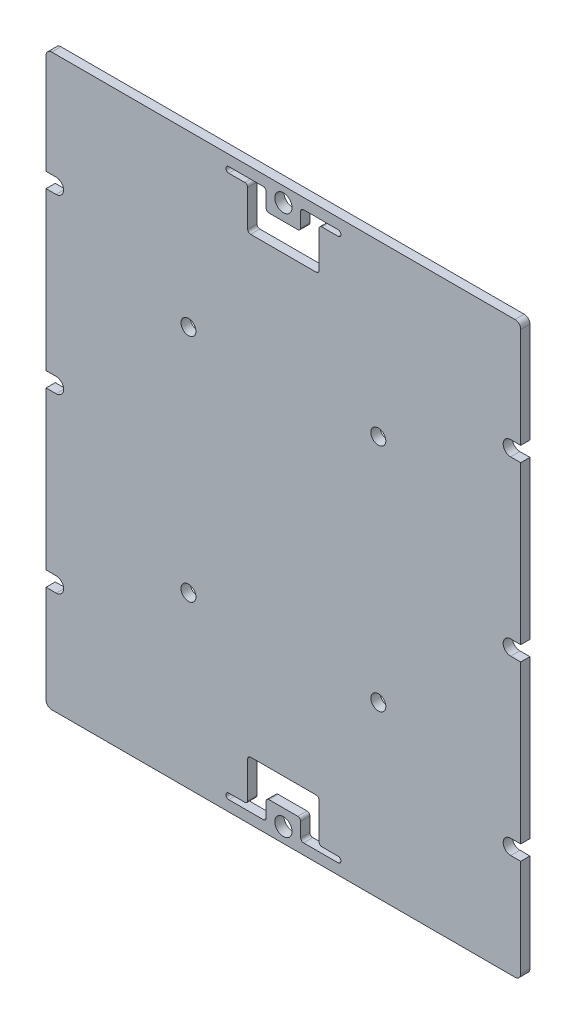
SolidWorks part; units mm, degrees
material "FR4_stuffedProtoboard"
ref_plane "Front Plane" through (0, 0, 0) normal (0, 0, 1) x (1, 0, 0)
ref_plane "Top Plane" through (0, 0, 0) normal (0, 1, 0) x (1, 0, 0)
ref_plane "Right Plane" through (0, 0, 0) normal (1, 0, 0) x (0, 0, -1)
sketch "Sketch2" plane through (0, 0, 0) normal (0, 0, 1) x (1, 0, 0)
  line L0 (39.5, 49.75) -> (-39.5, 49.75) construction
  line L1 (-41.5, 49.75) -> (41.5, 49.75) construction
  line L2 (-41.5, 49.75) -> (-41.5, -49.75) construction
  line L3 (-41.5, -49.75) -> (41.5, -49.75) construction
  line L4 (41.5, 49.75) -> (41.5, -49.75) construction
  line L5 (-41.5, 49.75) -> (41.5, -49.75) construction
  line L6 (-41.5, -49.75) -> (41.5, 49.75) construction
  line L7 (41.5, 51.75) -> (41.5, 40.35) construction
  line L8 (-41.5, 49.75) -> (41.5, 49.75) construction
  line L9 (41.5, 49.75) -> (41.5, -49.75) construction
  line L10 (-41.5, -49.75) -> (41.5, -49.75) construction
  line L11 (-41.5, 49.75) -> (-41.5, -49.75) construction
  line L12 (-37, -31.85) -> (37, -31.85) construction
  line L13 (-37, -30.25) -> (37, -30.25) construction
  line L14 (-37, -21.85) -> (37, -21.85) construction
  line L15 (-37, -20.25) -> (37, -20.25) construction
  line L16 (-37, -11.85) -> (37, -11.85) construction
  line L17 (-37, -10.25) -> (37, -10.25) construction
  line L18 (-37, -1.85) -> (37, -1.85) construction
  line L19 (-37, -0.25) -> (37, -0.25) construction
  line L20 (-37, 8.15) -> (37, 8.15) construction
  line L21 (-37, 9.75) -> (37, 9.75) construction
  line L22 (-37, 18.15) -> (37, 18.15) construction
  line L23 (-37, 19.75) -> (37, 19.75) construction
  line L24 (-37, 28.15) -> (37, 28.15) construction
  line L25 (-37, 29.75) -> (37, 29.75) construction
  line L26 (-37, 38.15) -> (37, 38.15) construction
  line L27 (-37, 39.75) -> (37, 39.75) construction
  line L28 (-37, -31.85) -> (37, -31.85) construction
  line L29 (-37, -30.25) -> (37, -30.25) construction
  line L30 (-37, -21.85) -> (37, -21.85) construction
  line L31 (-37, -20.25) -> (37, -20.25) construction
  line L32 (-37, -11.85) -> (37, -11.85) construction
  line L33 (-37, -10.25) -> (37, -10.25) construction
  line L34 (-37, -1.85) -> (37, -1.85) construction
  line L35 (-37, -0.25) -> (37, -0.25) construction
  line L36 (-37, 8.15) -> (37, 8.15) construction
  line L37 (-37, 9.75) -> (37, 9.75) construction
  line L38 (-37, 18.15) -> (37, 18.15) construction
  line L39 (-37, 19.75) -> (37, 19.75) construction
  line L40 (-37, 28.15) -> (37, 28.15) construction
  line L41 (-37, 29.75) -> (37, 29.75) construction
  line L42 (-37, 38.15) -> (37, 38.15) construction
  line L43 (-37, 39.75) -> (37, 39.75) construction
  line L44 (-37, -40.25) -> (37, -40.25) construction
  line L45 (-37, -41.85) -> (37, -41.85) construction
  line L46 (-41.5, 51.75) -> (-41.5, 40.35) construction
  line L47 (39.5, -49.75) -> (-39.5, -49.75) construction
  line L48 (41.5, -31.9) -> (41.5, -51.75) construction
  line L49 (-41.25, 49.5) -> (41.25, 49.5)
  line L50 (41.25, 49.5) -> (41.25, -49.5)
  line L51 (-41.25, -49.5) -> (41.25, -49.5)
  line L52 (-41.25, 49.5) -> (-41.25, -49.5)
  circle A0 centre (0, 46.95) radius 1.5 construction
  circle A1 centre (0, 46.95) radius 0.8 construction
  circle A2 centre (0, 46.95) radius 1.5 construction
  circle A3 centre (0, 46.95) radius 0.8
  circle A4 centre (-39.5, -30.25) radius 0.8 construction
  circle A5 centre (-39.5, -0.25) radius 0.8 construction
  circle A6 centre (-39.5, 29.75) radius 0.8 construction
  circle A7 centre (-39.5, -30.25) radius 0.8
  circle A8 centre (-39.5, -0.25) radius 0.8
  circle A9 centre (-39.5, 29.75) radius 0.8
  circle A10 centre (39.5, -30.25) radius 0.8 construction
  circle A11 centre (39.5, -0.25) radius 0.8 construction
  circle A12 centre (39.5, 29.75) radius 0.8 construction
  circle A13 centre (39.5, -30.25) radius 0.8
  circle A14 centre (39.5, -0.25) radius 0.8
  circle A15 centre (39.5, 29.75) radius 0.8
  circle A16 centre (0, -46.95) radius 0.8 construction
  circle A17 centre (0, -46.95) radius 0.8
  circle A18 centre (0, -46.95) radius 1.5 construction
  circle A19 centre (0, -46.95) radius 1.5
  circle A20 centre (-16.5, 20) radius 1.75 construction
  circle A21 centre (-16.5, 20) radius 0.8 construction
  circle A22 centre (-16.5, 20) radius 1.75 construction
  circle A23 centre (-16.5, 20) radius 0.8
  circle A24 centre (16.5, 20) radius 1.75 construction
  circle A25 centre (16.5, 20) radius 0.8 construction
  circle A26 centre (16.5, 20) radius 1.75 construction
  circle A27 centre (16.5, 20) radius 0.8
  circle A28 centre (16.5, -20) radius 1.75 construction
  circle A29 centre (-16.5, -20) radius 1.75 construction
  circle A30 centre (16.5, -20) radius 1.75 construction
  circle A31 centre (-16.5, -20) radius 1.75 construction
  circle A32 centre (-16.5, -20) radius 0.8 construction
  circle A33 centre (-16.5, -20) radius 0.8
  circle A34 centre (16.5, -20) radius 0.8 construction
  circle A35 centre (16.5, -20) radius 0.8
  point P0 (0, 0)
  point P74 (0, -40.25)
  point P75 (0, -31.85)
  point P76 (0, -41.85)
  dimension "D2" = 10
  dimension "D3" = 1.6
  dimension "D1" = 0.25
extrude "pcb extrude" add sketch "Sketch2" along normal mid plane 1.6 contours L4 L1 L2 L3 A2 | A2 A3 | L2 L1 L4 L3 region at (0, 0.0296, 0)
sketch "Debug Cutout" plane through (0, 0, 0.8) normal (0, 0, 1) x (1, 0, 0)
  line L0 (-37, -6.25) -> (-37, 5.75) construction
  line L17 (-29.5, -8.25) -> (-35, -8.25) construction
  line L18 (-35, 7.75) -> (-29.5, 7.75) construction
  line L19 (-27.5, 5.75) -> (-27.5, -6.25) construction
  line L20 (-37, -6.25) -> (-37, 5.75)
  line L21 (-29.5, -8.25) -> (-35, -8.25)
  line L22 (-35, 7.75) -> (-29.5, 7.75)
  line L23 (-27.5, 5.75) -> (-27.5, -6.25)
  arc A16 (-35, 7.75) -> (-37, 5.75) centre (-35, 5.75) ccw construction
  arc A17 (-37, -6.25) -> (-35, -8.25) centre (-35, -6.25) ccw construction
  arc A18 (-29.5, -8.25) -> (-27.5, -6.25) centre (-29.5, -6.25) ccw construction
  arc A19 (-27.5, 5.75) -> (-29.5, 7.75) centre (-29.5, 5.75) ccw construction
  arc A20 (-35, 7.75) -> (-37, 5.75) centre (-35, 5.75) ccw
  arc A21 (-37, -6.25) -> (-35, -8.25) centre (-35, -6.25) ccw
  arc A22 (-29.5, -8.25) -> (-27.5, -6.25) centre (-29.5, -6.25) ccw
  arc A23 (-27.5, 5.75) -> (-29.5, 7.75) centre (-29.5, 5.75) ccw
sketch "endcap connector" plane through (0, 0, 0.8) normal (0, 0, 1) x (1, 0, 0)
  line L0 (-10.3489, -47.209) -> (-10.3489, -49.749) construction
  line L1 (-36.1289, -47.209) -> (-10.3489, -47.209) construction
  line L2 (-36.1289, -47.209) -> (-10.3489, -47.209)
  line L3 (-36.1289, -49.749) -> (-36.1289, -47.209) construction
  line L4 (-10.3489, -47.209) -> (-10.3489, -49.749)
  line L5 (-36.1289, -49.749) -> (-36.1289, -47.209)
  point P3 (-23.2389, -47.209)
sketch "Sketch12" plane through (0, 0, 0) normal (0, 0, 1) x (1, 0, 0)
  line L0 (-40.25, -49.5) -> (40.25, -49.5)
  line L1 (-41.25, -31.55) -> (-39.5, -31.55)
  line L2 (-39.5, -28.95) -> (-41.25, -28.95)
  line L3 (-41.25, -1.55) -> (-39.5, -1.55)
  line L4 (-39.5, 1.05) -> (-41.25, 1.05)
  line L5 (-41.25, 28.45) -> (-39.5, 28.45)
  line L6 (-39.5, 31.05) -> (-41.25, 31.05)
  line L7 (-41.25, 48.5) -> (-41.25, 31.05)
  line L8 (40.25, 49.5) -> (-40.25, 49.5)
  line L9 (41.25, 31.05) -> (39.5, 31.05)
  line L10 (39.5, 28.45) -> (41.25, 28.45)
  line L11 (41.25, 1.05) -> (39.5, 1.05)
  line L12 (39.5, -1.55) -> (41.25, -1.55)
  line L13 (41.25, -28.95) -> (39.5, -28.95)
  line L14 (39.5, -31.55) -> (41.25, -31.55)
  line L15 (41.25, -48.5) -> (41.25, -31.55)
  line L16 (-41.25, -31.55) -> (-41.25, -48.5)
  line L17 (-41.25, 28.45) -> (-41.25, 1.05)
  line L18 (-41.25, -1.55) -> (-41.25, -28.95)
  line L19 (41.25, -28.95) -> (41.25, -1.55)
  line L20 (41.25, 1.05) -> (41.25, 28.45)
  line L21 (41.25, 31.05) -> (41.25, 48.5)
  line L22 (-3.5, 47.65) -> (-9.5, 47.65)
  line L23 (-9.5, 46.65) -> (-6.7, 46.65)
  line L24 (-6.2, 46.15) -> (-6.2, 39.85)
  line L25 (-5.7, 39.35) -> (5.7, 39.35)
  line L26 (6.2, 39.85) -> (6.2, 46.15)
  line L27 (6.7, 46.65) -> (9.5, 46.65)
  line L28 (9.5, 47.65) -> (3.5, 47.65)
  line L29 (3, 47.15) -> (3, 44.65)
  line L30 (2.5, 44.15) -> (-2.5, 44.15)
  line L31 (-3, 44.65) -> (-3, 47.15)
  line L32 (-3.5, -47.65) -> (-9.5, -47.65)
  line L33 (-3, -44.65) -> (-3, -47.15)
  line L34 (2.5, -44.15) -> (-2.5, -44.15)
  line L35 (3, -47.15) -> (3, -44.65)
  line L36 (9.5, -47.65) -> (3.5, -47.65)
  line L37 (6.7, -46.65) -> (9.5, -46.65)
  line L38 (6.2, -39.85) -> (6.2, -46.15)
  line L39 (-5.7, -39.35) -> (5.7, -39.35)
  line L40 (-6.2, -46.15) -> (-6.2, -39.85)
  line L41 (-9.5, -46.65) -> (-6.7, -46.65)
  line L42 (-9.91, 41.975) -> (-9.91, 41.225)
  line L43 (-9.16, 41.225) -> (-9.16, 41.975)
  line L44 (-9.91, 41.975) -> (-9.91, 41.225)
  line L45 (-9.16, 41.225) -> (-9.16, 41.975)
  line L46 (-9.16, 43.245) -> (-9.16, 43.995)
  line L47 (-9.91, 43.995) -> (-9.91, 43.245)
  line L48 (-9.16, 43.245) -> (-9.16, 43.995)
  line L49 (-9.91, 43.995) -> (-9.91, 43.245)
  line L50 (-11.18, 41.975) -> (-11.18, 41.225)
  line L51 (-10.43, 41.225) -> (-10.43, 41.975)
  line L52 (-11.18, 41.975) -> (-11.18, 41.225)
  line L53 (-10.43, 41.225) -> (-10.43, 41.975)
  line L54 (-10.43, 43.245) -> (-10.43, 43.995)
  line L55 (-11.18, 43.995) -> (-11.18, 43.245)
  line L56 (-10.43, 43.245) -> (-10.43, 43.995)
  line L57 (-11.18, 43.995) -> (-11.18, 43.245)
  line L58 (-12.45, 41.975) -> (-12.45, 41.225)
  line L59 (-11.7, 41.225) -> (-11.7, 41.975)
  line L60 (-12.45, 41.975) -> (-12.45, 41.225)
  line L61 (-11.7, 41.225) -> (-11.7, 41.975)
  line L62 (-11.7, 43.245) -> (-11.7, 43.995)
  line L63 (-12.45, 43.995) -> (-12.45, 43.245)
  line L64 (-11.7, 43.245) -> (-11.7, 43.995)
  line L65 (-12.45, 43.995) -> (-12.45, 43.245)
  line L66 (-13.72, 41.975) -> (-13.72, 41.225)
  line L67 (-12.97, 41.225) -> (-12.97, 41.975)
  line L68 (-13.72, 41.975) -> (-13.72, 41.225)
  line L69 (-12.97, 41.225) -> (-12.97, 41.975)
  line L70 (-12.97, 43.245) -> (-12.97, 43.995)
  line L71 (-13.72, 43.995) -> (-13.72, 43.245)
  line L72 (-12.97, 43.245) -> (-12.97, 43.995)
  line L73 (-13.72, 43.995) -> (-13.72, 43.245)
  line L74 (-14.99, 41.975) -> (-14.99, 41.225)
  line L75 (-14.24, 41.225) -> (-14.24, 41.975)
  line L76 (-14.99, 41.975) -> (-14.99, 41.225)
  line L77 (-14.24, 41.225) -> (-14.24, 41.975)
  line L78 (-14.24, 43.245) -> (-14.24, 43.995)
  line L79 (-14.99, 43.995) -> (-14.99, 43.245)
  line L80 (-14.24, 43.245) -> (-14.24, 43.995)
  line L81 (-14.99, 43.995) -> (-14.99, 43.245)
  line L82 (-16.26, 41.975) -> (-16.26, 41.225)
  line L83 (-15.51, 41.225) -> (-15.51, 41.975)
  line L84 (-16.26, 41.975) -> (-16.26, 41.225)
  line L85 (-15.51, 41.225) -> (-15.51, 41.975)
  line L86 (-15.51, 43.245) -> (-15.51, 43.995)
  line L87 (-16.26, 43.995) -> (-16.26, 43.245)
  line L88 (-15.51, 43.245) -> (-15.51, 43.995)
  line L89 (-16.26, 43.995) -> (-16.26, 43.245)
  line L90 (-17.53, 41.975) -> (-17.53, 41.225)
  line L91 (-16.78, 41.225) -> (-16.78, 41.975)
  line L92 (-17.53, 41.975) -> (-17.53, 41.225)
  line L93 (-16.78, 41.225) -> (-16.78, 41.975)
  line L94 (-16.78, 43.245) -> (-16.78, 43.995)
  line L95 (-17.53, 43.995) -> (-17.53, 43.245)
  line L96 (-16.78, 43.245) -> (-16.78, 43.995)
  line L97 (-17.53, 43.995) -> (-17.53, 43.245)
  line L98 (-18.8, 41.975) -> (-18.8, 41.225)
  line L99 (-18.05, 41.225) -> (-18.05, 41.975)
  line L100 (-18.8, 41.975) -> (-18.8, 41.225)
  line L101 (-18.05, 41.225) -> (-18.05, 41.975)
  line L102 (-18.05, 43.245) -> (-18.05, 43.995)
  line L103 (-18.8, 43.995) -> (-18.8, 43.245)
  line L104 (-18.05, 43.245) -> (-18.05, 43.995)
  line L105 (-18.8, 43.995) -> (-18.8, 43.245)
  line L106 (-20.07, 41.975) -> (-20.07, 41.225)
  line L107 (-19.32, 41.225) -> (-19.32, 41.975)
  line L108 (-20.07, 41.975) -> (-20.07, 41.225)
  line L109 (-19.32, 41.225) -> (-19.32, 41.975)
  line L110 (-19.32, 43.245) -> (-19.32, 43.995)
  line L111 (-20.07, 43.995) -> (-20.07, 43.245)
  line L112 (-19.32, 43.245) -> (-19.32, 43.995)
  line L113 (-20.07, 43.995) -> (-20.07, 43.245)
  line L114 (-21.34, 41.975) -> (-21.34, 41.225)
  line L115 (-20.59, 41.225) -> (-20.59, 41.975)
  line L116 (-21.34, 41.975) -> (-21.34, 41.225)
  line L117 (-20.59, 41.225) -> (-20.59, 41.975)
  line L118 (-20.59, 43.245) -> (-20.59, 43.995)
  line L119 (-21.34, 43.995) -> (-21.34, 43.245)
  line L120 (-20.59, 43.245) -> (-20.59, 43.995)
  line L121 (-21.34, 43.995) -> (-21.34, 43.245)
  line L122 (-22.61, 41.975) -> (-22.61, 41.225)
  line L123 (-21.86, 41.225) -> (-21.86, 41.975)
  line L124 (-22.61, 41.975) -> (-22.61, 41.225)
  line L125 (-21.86, 41.225) -> (-21.86, 41.975)
  line L126 (-21.86, 43.245) -> (-21.86, 43.995)
  line L127 (-22.61, 43.995) -> (-22.61, 43.245)
  line L128 (-21.86, 43.245) -> (-21.86, 43.995)
  line L129 (-22.61, 43.995) -> (-22.61, 43.245)
  line L130 (-23.88, 41.975) -> (-23.88, 41.225)
  line L131 (-23.13, 41.225) -> (-23.13, 41.975)
  line L132 (-23.88, 41.975) -> (-23.88, 41.225)
  line L133 (-23.13, 41.225) -> (-23.13, 41.975)
  line L134 (-23.13, 43.245) -> (-23.13, 43.995)
  line L135 (-23.88, 43.995) -> (-23.88, 43.245)
  line L136 (-23.13, 43.245) -> (-23.13, 43.995)
  line L137 (-23.88, 43.995) -> (-23.88, 43.245)
  line L138 (-25.15, 41.975) -> (-25.15, 41.225)
  line L139 (-24.4, 41.225) -> (-24.4, 41.975)
  line L140 (-25.15, 41.975) -> (-25.15, 41.225)
  line L141 (-24.4, 41.225) -> (-24.4, 41.975)
  line L142 (-24.4, 43.245) -> (-24.4, 43.995)
  line L143 (-25.15, 43.995) -> (-25.15, 43.245)
  line L144 (-24.4, 43.245) -> (-24.4, 43.995)
  line L145 (-25.15, 43.995) -> (-25.15, 43.245)
  line L146 (-26.42, 41.975) -> (-26.42, 41.225)
  line L147 (-25.67, 41.225) -> (-25.67, 41.975)
  line L148 (-26.42, 41.975) -> (-26.42, 41.225)
  line L149 (-25.67, 41.225) -> (-25.67, 41.975)
  line L150 (-25.67, 43.245) -> (-25.67, 43.995)
  line L151 (-26.42, 43.995) -> (-26.42, 43.245)
  line L152 (-25.67, 43.245) -> (-25.67, 43.995)
  line L153 (-26.42, 43.995) -> (-26.42, 43.245)
  line L154 (-27.69, 41.975) -> (-27.69, 41.225)
  line L155 (-26.94, 41.225) -> (-26.94, 41.975)
  line L156 (-27.69, 41.975) -> (-27.69, 41.225)
  line L157 (-26.94, 41.225) -> (-26.94, 41.975)
  line L158 (-26.94, 43.245) -> (-26.94, 43.995)
  line L159 (-27.69, 43.995) -> (-27.69, 43.245)
  line L160 (-26.94, 43.245) -> (-26.94, 43.995)
  line L161 (-27.69, 43.995) -> (-27.69, 43.245)
  line L162 (-28.96, 41.975) -> (-28.96, 41.225)
  line L163 (-28.21, 41.225) -> (-28.21, 41.975)
  line L164 (-28.96, 41.975) -> (-28.96, 41.225)
  line L165 (-28.21, 41.225) -> (-28.21, 41.975)
  line L166 (-28.21, 43.245) -> (-28.21, 43.995)
  line L167 (-28.96, 43.995) -> (-28.96, 43.245)
  line L168 (-28.21, 43.245) -> (-28.21, 43.995)
  line L169 (-28.96, 43.995) -> (-28.96, 43.245)
  line L170 (-30.23, 41.975) -> (-30.23, 41.225)
  line L171 (-29.48, 41.225) -> (-29.48, 41.975)
  line L172 (-30.23, 41.975) -> (-30.23, 41.225)
  line L173 (-29.48, 41.225) -> (-29.48, 41.975)
  line L174 (-29.48, 43.245) -> (-29.48, 43.995)
  line L175 (-30.23, 43.995) -> (-30.23, 43.245)
  line L176 (-29.48, 43.245) -> (-29.48, 43.995)
  line L177 (-30.23, 43.995) -> (-30.23, 43.245)
  line L178 (-31.5, 41.975) -> (-31.5, 41.225)
  line L179 (-30.75, 41.225) -> (-30.75, 41.975)
  line L180 (-31.5, 41.975) -> (-31.5, 41.225)
  line L181 (-30.75, 41.225) -> (-30.75, 41.975)
  line L182 (-30.75, 43.245) -> (-30.75, 43.995)
  line L183 (-31.5, 43.995) -> (-31.5, 43.245)
  line L184 (-30.75, 43.245) -> (-30.75, 43.995)
  line L185 (-31.5, 43.995) -> (-31.5, 43.245)
  line L186 (-32.77, 41.975) -> (-32.77, 41.225)
  line L187 (-32.02, 41.225) -> (-32.02, 41.975)
  line L188 (-32.77, 41.975) -> (-32.77, 41.225)
  line L189 (-32.02, 41.225) -> (-32.02, 41.975)
  line L190 (-32.02, 43.245) -> (-32.02, 43.995)
  line L191 (-32.77, 43.995) -> (-32.77, 43.245)
  line L192 (-32.02, 43.245) -> (-32.02, 43.995)
  line L193 (-32.77, 43.995) -> (-32.77, 43.245)
  line L194 (-34.04, 41.975) -> (-34.04, 41.225)
  line L195 (-33.29, 41.225) -> (-33.29, 41.975)
  line L196 (-34.04, 41.975) -> (-34.04, 41.225)
  line L197 (-33.29, 41.225) -> (-33.29, 41.975)
  line L198 (-33.29, 43.245) -> (-33.29, 43.995)
  line L199 (-34.04, 43.995) -> (-34.04, 43.245)
  line L200 (-33.29, 43.245) -> (-33.29, 43.995)
  line L201 (-34.04, 43.995) -> (-34.04, 43.245)
  line L202 (-22.66, 31.975) -> (-22.66, 31.225)
  line L203 (-21.91, 31.225) -> (-21.91, 31.975)
  line L204 (-22.66, 31.975) -> (-22.66, 31.225)
  line L205 (-21.91, 31.225) -> (-21.91, 31.975)
  line L206 (-21.91, 33.245) -> (-21.91, 33.995)
  line L207 (-22.66, 33.995) -> (-22.66, 33.245)
  line L208 (-21.91, 33.245) -> (-21.91, 33.995)
  line L209 (-22.66, 33.995) -> (-22.66, 33.245)
  line L210 (-23.93, 31.975) -> (-23.93, 31.225)
  line L211 (-23.18, 31.225) -> (-23.18, 31.975)
  line L212 (-23.93, 31.975) -> (-23.93, 31.225)
  line L213 (-23.18, 31.225) -> (-23.18, 31.975)
  line L214 (-23.18, 33.245) -> (-23.18, 33.995)
  line L215 (-23.93, 33.995) -> (-23.93, 33.245)
  line L216 (-23.18, 33.245) -> (-23.18, 33.995)
  line L217 (-23.93, 33.995) -> (-23.93, 33.245)
  line L218 (-25.2, 31.975) -> (-25.2, 31.225)
  line L219 (-24.45, 31.225) -> (-24.45, 31.975)
  line L220 (-25.2, 31.975) -> (-25.2, 31.225)
  line L221 (-24.45, 31.225) -> (-24.45, 31.975)
  line L222 (-24.45, 33.245) -> (-24.45, 33.995)
  line L223 (-25.2, 33.995) -> (-25.2, 33.245)
  line L224 (-24.45, 33.245) -> (-24.45, 33.995)
  line L225 (-25.2, 33.995) -> (-25.2, 33.245)
  line L226 (-26.47, 31.975) -> (-26.47, 31.225)
  line L227 (-25.72, 31.225) -> (-25.72, 31.975)
  line L228 (-26.47, 31.975) -> (-26.47, 31.225)
  line L229 (-25.72, 31.225) -> (-25.72, 31.975)
  line L230 (-25.72, 33.245) -> (-25.72, 33.995)
  line L231 (-26.47, 33.995) -> (-26.47, 33.245)
  line L232 (-25.72, 33.245) -> (-25.72, 33.995)
  line L233 (-26.47, 33.995) -> (-26.47, 33.245)
  line L234 (-27.74, 31.975) -> (-27.74, 31.225)
  line L235 (-26.99, 31.225) -> (-26.99, 31.975)
  line L236 (-27.74, 31.975) -> (-27.74, 31.225)
  line L237 (-26.99, 31.225) -> (-26.99, 31.975)
  line L238 (-26.99, 33.245) -> (-26.99, 33.995)
  line L239 (-27.74, 33.995) -> (-27.74, 33.245)
  line L240 (-26.99, 33.245) -> (-26.99, 33.995)
  line L241 (-27.74, 33.995) -> (-27.74, 33.245)
  line L242 (-29.01, 31.975) -> (-29.01, 31.225)
  line L243 (-28.26, 31.225) -> (-28.26, 31.975)
  line L244 (-29.01, 31.975) -> (-29.01, 31.225)
  line L245 (-28.26, 31.225) -> (-28.26, 31.975)
  line L246 (-28.26, 33.245) -> (-28.26, 33.995)
  line L247 (-29.01, 33.995) -> (-29.01, 33.245)
  line L248 (-28.26, 33.245) -> (-28.26, 33.995)
  line L249 (-29.01, 33.995) -> (-29.01, 33.245)
  line L250 (-30.28, 31.975) -> (-30.28, 31.225)
  line L251 (-29.53, 31.225) -> (-29.53, 31.975)
  line L252 (-30.28, 31.975) -> (-30.28, 31.225)
  line L253 (-29.53, 31.225) -> (-29.53, 31.975)
  line L254 (-29.53, 33.245) -> (-29.53, 33.995)
  line L255 (-30.28, 33.995) -> (-30.28, 33.245)
  line L256 (-29.53, 33.245) -> (-29.53, 33.995)
  line L257 (-30.28, 33.995) -> (-30.28, 33.245)
  line L258 (-31.55, 31.975) -> (-31.55, 31.225)
  line L259 (-30.8, 31.225) -> (-30.8, 31.975)
  line L260 (-31.55, 31.975) -> (-31.55, 31.225)
  line L261 (-30.8, 31.225) -> (-30.8, 31.975)
  line L262 (-30.8, 33.245) -> (-30.8, 33.995)
  line L263 (-31.55, 33.995) -> (-31.55, 33.245)
  line L264 (-30.8, 33.245) -> (-30.8, 33.995)
  line L265 (-31.55, 33.995) -> (-31.55, 33.245)
  line L266 (-32.82, 31.975) -> (-32.82, 31.225)
  line L267 (-32.07, 31.225) -> (-32.07, 31.975)
  line L268 (-32.82, 31.975) -> (-32.82, 31.225)
  line L269 (-32.07, 31.225) -> (-32.07, 31.975)
  line L270 (-32.07, 33.245) -> (-32.07, 33.995)
  line L271 (-32.82, 33.995) -> (-32.82, 33.245)
  line L272 (-32.07, 33.245) -> (-32.07, 33.995)
  line L273 (-32.82, 33.995) -> (-32.82, 33.245)
  line L274 (-34.09, 31.975) -> (-34.09, 31.225)
  line L275 (-33.34, 31.225) -> (-33.34, 31.975)
  line L276 (-34.09, 31.975) -> (-34.09, 31.225)
  line L277 (-33.34, 31.225) -> (-33.34, 31.975)
  line L278 (-33.34, 33.245) -> (-33.34, 33.995)
  line L279 (-34.09, 33.995) -> (-34.09, 33.245)
  line L280 (-33.34, 33.245) -> (-33.34, 33.995)
  line L281 (-34.09, 33.995) -> (-34.09, 33.245)
  line L282 (11.69, 31.975) -> (11.69, 31.225)
  line L283 (12.44, 31.225) -> (12.44, 31.975)
  line L284 (11.69, 31.975) -> (11.69, 31.225)
  line L285 (12.44, 31.225) -> (12.44, 31.975)
  line L286 (12.44, 33.245) -> (12.44, 33.995)
  line L287 (11.69, 33.995) -> (11.69, 33.245)
  line L288 (12.44, 33.245) -> (12.44, 33.995)
  line L289 (11.69, 33.995) -> (11.69, 33.245)
  line L290 (10.42, 31.975) -> (10.42, 31.225)
  line L291 (11.17, 31.225) -> (11.17, 31.975)
  line L292 (10.42, 31.975) -> (10.42, 31.225)
  line L293 (11.17, 31.225) -> (11.17, 31.975)
  line L294 (11.17, 33.245) -> (11.17, 33.995)
  line L295 (10.42, 33.995) -> (10.42, 33.245)
  line L296 (11.17, 33.245) -> (11.17, 33.995)
  line L297 (10.42, 33.995) -> (10.42, 33.245)
  line L298 (9.15, 31.975) -> (9.15, 31.225)
  line L299 (9.9, 31.225) -> (9.9, 31.975)
  line L300 (9.15, 31.975) -> (9.15, 31.225)
  line L301 (9.9, 31.225) -> (9.9, 31.975)
  line L302 (9.9, 33.245) -> (9.9, 33.995)
  line L303 (9.15, 33.995) -> (9.15, 33.245)
  line L304 (9.9, 33.245) -> (9.9, 33.995)
  line L305 (9.15, 33.995) -> (9.15, 33.245)
  line L306 (7.88, 31.975) -> (7.88, 31.225)
  line L307 (8.63, 31.225) -> (8.63, 31.975)
  line L308 (7.88, 31.975) -> (7.88, 31.225)
  line L309 (8.63, 31.225) -> (8.63, 31.975)
  line L310 (8.63, 33.245) -> (8.63, 33.995)
  line L311 (7.88, 33.995) -> (7.88, 33.245)
  line L312 (8.63, 33.245) -> (8.63, 33.995)
  line L313 (7.88, 33.995) -> (7.88, 33.245)
  line L314 (6.61, 31.975) -> (6.61, 31.225)
  line L315 (7.36, 31.225) -> (7.36, 31.975)
  line L316 (6.61, 31.975) -> (6.61, 31.225)
  line L317 (7.36, 31.225) -> (7.36, 31.975)
  line L318 (7.36, 33.245) -> (7.36, 33.995)
  line L319 (6.61, 33.995) -> (6.61, 33.245)
  line L320 (7.36, 33.245) -> (7.36, 33.995)
  line L321 (6.61, 33.995) -> (6.61, 33.245)
  line L322 (5.34, 31.975) -> (5.34, 31.225)
  line L323 (6.09, 31.225) -> (6.09, 31.975)
  line L324 (5.34, 31.975) -> (5.34, 31.225)
  line L325 (6.09, 31.225) -> (6.09, 31.975)
  line L326 (6.09, 33.245) -> (6.09, 33.995)
  line L327 (5.34, 33.995) -> (5.34, 33.245)
  line L328 (6.09, 33.245) -> (6.09, 33.995)
  line L329 (5.34, 33.995) -> (5.34, 33.245)
  line L330 (4.07, 31.975) -> (4.07, 31.225)
  line L331 (4.82, 31.225) -> (4.82, 31.975)
  line L332 (4.07, 31.975) -> (4.07, 31.225)
  line L333 (4.82, 31.225) -> (4.82, 31.975)
  line L334 (4.82, 33.245) -> (4.82, 33.995)
  line L335 (4.07, 33.995) -> (4.07, 33.245)
  line L336 (4.82, 33.245) -> (4.82, 33.995)
  line L337 (4.07, 33.995) -> (4.07, 33.245)
  line L338 (2.8, 31.975) -> (2.8, 31.225)
  line L339 (3.55, 31.225) -> (3.55, 31.975)
  line L340 (2.8, 31.975) -> (2.8, 31.225)
  line L341 (3.55, 31.225) -> (3.55, 31.975)
  line L342 (3.55, 33.245) -> (3.55, 33.995)
  line L343 (2.8, 33.995) -> (2.8, 33.245)
  line L344 (3.55, 33.245) -> (3.55, 33.995)
  line L345 (2.8, 33.995) -> (2.8, 33.245)
  line L346 (1.53, 31.975) -> (1.53, 31.225)
  line L347 (2.28, 31.225) -> (2.28, 31.975)
  line L348 (1.53, 31.975) -> (1.53, 31.225)
  line L349 (2.28, 31.225) -> (2.28, 31.975)
  line L350 (2.28, 33.245) -> (2.28, 33.995)
  line L351 (1.53, 33.995) -> (1.53, 33.245)
  line L352 (2.28, 33.245) -> (2.28, 33.995)
  line L353 (1.53, 33.995) -> (1.53, 33.245)
  line L354 (0.26, 31.975) -> (0.26, 31.225)
  line L355 (1.01, 31.225) -> (1.01, 31.975)
  line L356 (0.26, 31.975) -> (0.26, 31.225)
  line L357 (1.01, 31.225) -> (1.01, 31.975)
  line L358 (1.01, 33.245) -> (1.01, 33.995)
  line L359 (0.26, 33.995) -> (0.26, 33.245)
  line L360 (1.01, 33.245) -> (1.01, 33.995)
  line L361 (0.26, 33.995) -> (0.26, 33.245)
  line L362 (-1.01, 31.975) -> (-1.01, 31.225)
  line L363 (-0.26, 31.225) -> (-0.26, 31.975)
  line L364 (-1.01, 31.975) -> (-1.01, 31.225)
  line L365 (-0.26, 31.225) -> (-0.26, 31.975)
  line L366 (-0.26, 33.245) -> (-0.26, 33.995)
  line L367 (-1.01, 33.995) -> (-1.01, 33.245)
  line L368 (-0.26, 33.245) -> (-0.26, 33.995)
  line L369 (-1.01, 33.995) -> (-1.01, 33.245)
  line L370 (-2.28, 31.975) -> (-2.28, 31.225)
  line L371 (-1.53, 31.225) -> (-1.53, 31.975)
  line L372 (-2.28, 31.975) -> (-2.28, 31.225)
  line L373 (-1.53, 31.225) -> (-1.53, 31.975)
  line L374 (-1.53, 33.245) -> (-1.53, 33.995)
  line L375 (-2.28, 33.995) -> (-2.28, 33.245)
  line L376 (-1.53, 33.245) -> (-1.53, 33.995)
  line L377 (-2.28, 33.995) -> (-2.28, 33.245)
  line L378 (-3.55, 31.975) -> (-3.55, 31.225)
  line L379 (-2.8, 31.225) -> (-2.8, 31.975)
  line L380 (-3.55, 31.975) -> (-3.55, 31.225)
  line L381 (-2.8, 31.225) -> (-2.8, 31.975)
  line L382 (-2.8, 33.245) -> (-2.8, 33.995)
  line L383 (-3.55, 33.995) -> (-3.55, 33.245)
  line L384 (-2.8, 33.245) -> (-2.8, 33.995)
  line L385 (-3.55, 33.995) -> (-3.55, 33.245)
  line L386 (-4.82, 31.975) -> (-4.82, 31.225)
  line L387 (-4.07, 31.225) -> (-4.07, 31.975)
  line L388 (-4.82, 31.975) -> (-4.82, 31.225)
  line L389 (-4.07, 31.225) -> (-4.07, 31.975)
  line L390 (-4.07, 33.245) -> (-4.07, 33.995)
  line L391 (-4.82, 33.995) -> (-4.82, 33.245)
  line L392 (-4.07, 33.245) -> (-4.07, 33.995)
  line L393 (-4.82, 33.995) -> (-4.82, 33.245)
  line L394 (-6.09, 31.975) -> (-6.09, 31.225)
  line L395 (-5.34, 31.225) -> (-5.34, 31.975)
  line L396 (-6.09, 31.975) -> (-6.09, 31.225)
  line L397 (-5.34, 31.225) -> (-5.34, 31.975)
  line L398 (-5.34, 33.245) -> (-5.34, 33.995)
  line L399 (-6.09, 33.995) -> (-6.09, 33.245)
  line L400 (-5.34, 33.245) -> (-5.34, 33.995)
  line L401 (-6.09, 33.995) -> (-6.09, 33.245)
  line L402 (-7.36, 31.975) -> (-7.36, 31.225)
  line L403 (-6.61, 31.225) -> (-6.61, 31.975)
  line L404 (-7.36, 31.975) -> (-7.36, 31.225)
  line L405 (-6.61, 31.225) -> (-6.61, 31.975)
  line L406 (-6.61, 33.245) -> (-6.61, 33.995)
  line L407 (-7.36, 33.995) -> (-7.36, 33.245)
  line L408 (-6.61, 33.245) -> (-6.61, 33.995)
  line L409 (-7.36, 33.995) -> (-7.36, 33.245)
  line L410 (-8.63, 31.975) -> (-8.63, 31.225)
  line L411 (-7.88, 31.225) -> (-7.88, 31.975)
  line L412 (-8.63, 31.975) -> (-8.63, 31.225)
  line L413 (-7.88, 31.225) -> (-7.88, 31.975)
  line L414 (-7.88, 33.245) -> (-7.88, 33.995)
  line L415 (-8.63, 33.995) -> (-8.63, 33.245)
  line L416 (-7.88, 33.245) -> (-7.88, 33.995)
  line L417 (-8.63, 33.995) -> (-8.63, 33.245)
  line L418 (-9.9, 31.975) -> (-9.9, 31.225)
  line L419 (-9.15, 31.225) -> (-9.15, 31.975)
  line L420 (-9.9, 31.975) -> (-9.9, 31.225)
  line L421 (-9.15, 31.225) -> (-9.15, 31.975)
  line L422 (-9.15, 33.245) -> (-9.15, 33.995)
  line L423 (-9.9, 33.995) -> (-9.9, 33.245)
  line L424 (-9.15, 33.245) -> (-9.15, 33.995)
  line L425 (-9.9, 33.995) -> (-9.9, 33.245)
  line L426 (-11.17, 31.975) -> (-11.17, 31.225)
  line L427 (-10.42, 31.225) -> (-10.42, 31.975)
  line L428 (-11.17, 31.975) -> (-11.17, 31.225)
  line L429 (-10.42, 31.225) -> (-10.42, 31.975)
  line L430 (-10.42, 33.245) -> (-10.42, 33.995)
  line L431 (-11.17, 33.995) -> (-11.17, 33.245)
  line L432 (-10.42, 33.245) -> (-10.42, 33.995)
  line L433 (-11.17, 33.995) -> (-11.17, 33.245)
  line L434 (-12.44, 31.975) -> (-12.44, 31.225)
  line L435 (-11.69, 31.225) -> (-11.69, 31.975)
  line L436 (-12.44, 31.975) -> (-12.44, 31.225)
  line L437 (-11.69, 31.225) -> (-11.69, 31.975)
  line L438 (-11.69, 33.245) -> (-11.69, 33.995)
  line L439 (-12.44, 33.995) -> (-12.44, 33.245)
  line L440 (-11.69, 33.245) -> (-11.69, 33.995)
  line L441 (-12.44, 33.995) -> (-12.44, 33.245)
  line L442 (-22.66, 21.975) -> (-22.66, 21.225)
  line L443 (-21.91, 21.225) -> (-21.91, 21.975)
  line L444 (-22.66, 21.975) -> (-22.66, 21.225)
  line L445 (-21.91, 21.225) -> (-21.91, 21.975)
  line L446 (-21.91, 23.245) -> (-21.91, 23.995)
  line L447 (-22.66, 23.995) -> (-22.66, 23.245)
  line L448 (-21.91, 23.245) -> (-21.91, 23.995)
  line L449 (-22.66, 23.995) -> (-22.66, 23.245)
  line L450 (-23.93, 21.975) -> (-23.93, 21.225)
  line L451 (-23.18, 21.225) -> (-23.18, 21.975)
  line L452 (-23.93, 21.975) -> (-23.93, 21.225)
  line L453 (-23.18, 21.225) -> (-23.18, 21.975)
  line L454 (-23.18, 23.245) -> (-23.18, 23.995)
  line L455 (-23.93, 23.995) -> (-23.93, 23.245)
  line L456 (-23.18, 23.245) -> (-23.18, 23.995)
  line L457 (-23.93, 23.995) -> (-23.93, 23.245)
  line L458 (-25.2, 21.975) -> (-25.2, 21.225)
  line L459 (-24.45, 21.225) -> (-24.45, 21.975)
  line L460 (-25.2, 21.975) -> (-25.2, 21.225)
  line L461 (-24.45, 21.225) -> (-24.45, 21.975)
  line L462 (-24.45, 23.245) -> (-24.45, 23.995)
  line L463 (-25.2, 23.995) -> (-25.2, 23.245)
  line L464 (-24.45, 23.245) -> (-24.45, 23.995)
  line L465 (-25.2, 23.995) -> (-25.2, 23.245)
  line L466 (-26.47, 21.975) -> (-26.47, 21.225)
  line L467 (-25.72, 21.225) -> (-25.72, 21.975)
  line L468 (-26.47, 21.975) -> (-26.47, 21.225)
  line L469 (-25.72, 21.225) -> (-25.72, 21.975)
  line L470 (-25.72, 23.245) -> (-25.72, 23.995)
  line L471 (-26.47, 23.995) -> (-26.47, 23.245)
  line L472 (-25.72, 23.245) -> (-25.72, 23.995)
  line L473 (-26.47, 23.995) -> (-26.47, 23.245)
  line L474 (-27.74, 21.975) -> (-27.74, 21.225)
  line L475 (-26.99, 21.225) -> (-26.99, 21.975)
  line L476 (-27.74, 21.975) -> (-27.74, 21.225)
  line L477 (-26.99, 21.225) -> (-26.99, 21.975)
  line L478 (-26.99, 23.245) -> (-26.99, 23.995)
  line L479 (-27.74, 23.995) -> (-27.74, 23.245)
  line L480 (-26.99, 23.245) -> (-26.99, 23.995)
  line L481 (-27.74, 23.995) -> (-27.74, 23.245)
  line L482 (-29.01, 21.975) -> (-29.01, 21.225)
  line L483 (-28.26, 21.225) -> (-28.26, 21.975)
  line L484 (-29.01, 21.975) -> (-29.01, 21.225)
  line L485 (-28.26, 21.225) -> (-28.26, 21.975)
  line L486 (-28.26, 23.245) -> (-28.26, 23.995)
  line L487 (-29.01, 23.995) -> (-29.01, 23.245)
  line L488 (-28.26, 23.245) -> (-28.26, 23.995)
  line L489 (-29.01, 23.995) -> (-29.01, 23.245)
  line L490 (-30.28, 21.975) -> (-30.28, 21.225)
  line L491 (-29.53, 21.225) -> (-29.53, 21.975)
  line L492 (-30.28, 21.975) -> (-30.28, 21.225)
  line L493 (-29.53, 21.225) -> (-29.53, 21.975)
  line L494 (-29.53, 23.245) -> (-29.53, 23.995)
  line L495 (-30.28, 23.995) -> (-30.28, 23.245)
  line L496 (-29.53, 23.245) -> (-29.53, 23.995)
  line L497 (-30.28, 23.995) -> (-30.28, 23.245)
  line L498 (-31.55, 21.975) -> (-31.55, 21.225)
  line L499 (-30.8, 21.225) -> (-30.8, 21.975)
  line L500 (-31.55, 21.975) -> (-31.55, 21.225)
  line L501 (-30.8, 21.225) -> (-30.8, 21.975)
  line L502 (-30.8, 23.245) -> (-30.8, 23.995)
  line L503 (-31.55, 23.995) -> (-31.55, 23.245)
  line L504 (-30.8, 23.245) -> (-30.8, 23.995)
  line L505 (-31.55, 23.995) -> (-31.55, 23.245)
  line L506 (-32.82, 21.975) -> (-32.82, 21.225)
  line L507 (-32.07, 21.225) -> (-32.07, 21.975)
  line L508 (-32.82, 21.975) -> (-32.82, 21.225)
  line L509 (-32.07, 21.225) -> (-32.07, 21.975)
  line L510 (-32.07, 23.245) -> (-32.07, 23.995)
  line L511 (-32.82, 23.995) -> (-32.82, 23.245)
  line L512 (-32.07, 23.245) -> (-32.07, 23.995)
  line L513 (-32.82, 23.995) -> (-32.82, 23.245)
  line L514 (-34.09, 21.975) -> (-34.09, 21.225)
  line L515 (-33.34, 21.225) -> (-33.34, 21.975)
  line L516 (-34.09, 21.975) -> (-34.09, 21.225)
  line L517 (-33.34, 21.225) -> (-33.34, 21.975)
  line L518 (-33.34, 23.245) -> (-33.34, 23.995)
  line L519 (-34.09, 23.995) -> (-34.09, 23.245)
  line L520 (-33.34, 23.245) -> (-33.34, 23.995)
  line L521 (-34.09, 23.995) -> (-34.09, 23.245)
  line L522 (11.69, 21.975) -> (11.69, 21.225)
  line L523 (12.44, 21.225) -> (12.44, 21.975)
  line L524 (11.69, 21.975) -> (11.69, 21.225)
  line L525 (12.44, 21.225) -> (12.44, 21.975)
  line L526 (12.44, 23.245) -> (12.44, 23.995)
  line L527 (11.69, 23.995) -> (11.69, 23.245)
  line L528 (12.44, 23.245) -> (12.44, 23.995)
  line L529 (11.69, 23.995) -> (11.69, 23.245)
  line L530 (10.42, 21.975) -> (10.42, 21.225)
  line L531 (11.17, 21.225) -> (11.17, 21.975)
  line L532 (10.42, 21.975) -> (10.42, 21.225)
  line L533 (11.17, 21.225) -> (11.17, 21.975)
  line L534 (11.17, 23.245) -> (11.17, 23.995)
  line L535 (10.42, 23.995) -> (10.42, 23.245)
  line L536 (11.17, 23.245) -> (11.17, 23.995)
  line L537 (10.42, 23.995) -> (10.42, 23.245)
  line L538 (9.15, 21.975) -> (9.15, 21.225)
  line L539 (9.9, 21.225) -> (9.9, 21.975)
  line L540 (9.15, 21.975) -> (9.15, 21.225)
  line L541 (9.9, 21.225) -> (9.9, 21.975)
  line L542 (9.9, 23.245) -> (9.9, 23.995)
  line L543 (9.15, 23.995) -> (9.15, 23.245)
  line L544 (9.9, 23.245) -> (9.9, 23.995)
  line L545 (9.15, 23.995) -> (9.15, 23.245)
  line L546 (7.88, 21.975) -> (7.88, 21.225)
  line L547 (8.63, 21.225) -> (8.63, 21.975)
  line L548 (7.88, 21.975) -> (7.88, 21.225)
  line L549 (8.63, 21.225) -> (8.63, 21.975)
  line L550 (8.63, 23.245) -> (8.63, 23.995)
  line L551 (7.88, 23.995) -> (7.88, 23.245)
  line L552 (8.63, 23.245) -> (8.63, 23.995)
  line L553 (7.88, 23.995) -> (7.88, 23.245)
  line L554 (6.61, 21.975) -> (6.61, 21.225)
  line L555 (7.36, 21.225) -> (7.36, 21.975)
  line L556 (6.61, 21.975) -> (6.61, 21.225)
  line L557 (7.36, 21.225) -> (7.36, 21.975)
  line L558 (7.36, 23.245) -> (7.36, 23.995)
  line L559 (6.61, 23.995) -> (6.61, 23.245)
  line L560 (7.36, 23.245) -> (7.36, 23.995)
  line L561 (6.61, 23.995) -> (6.61, 23.245)
  line L562 (5.34, 21.975) -> (5.34, 21.225)
  line L563 (6.09, 21.225) -> (6.09, 21.975)
  line L564 (5.34, 21.975) -> (5.34, 21.225)
  line L565 (6.09, 21.225) -> (6.09, 21.975)
  line L566 (6.09, 23.245) -> (6.09, 23.995)
  line L567 (5.34, 23.995) -> (5.34, 23.245)
  line L568 (6.09, 23.245) -> (6.09, 23.995)
  line L569 (5.34, 23.995) -> (5.34, 23.245)
  line L570 (4.07, 21.975) -> (4.07, 21.225)
  line L571 (4.82, 21.225) -> (4.82, 21.975)
  line L572 (4.07, 21.975) -> (4.07, 21.225)
  line L573 (4.82, 21.225) -> (4.82, 21.975)
  line L574 (4.82, 23.245) -> (4.82, 23.995)
  line L575 (4.07, 23.995) -> (4.07, 23.245)
  line L576 (4.82, 23.245) -> (4.82, 23.995)
  line L577 (4.07, 23.995) -> (4.07, 23.245)
  line L578 (2.8, 21.975) -> (2.8, 21.225)
  line L579 (3.55, 21.225) -> (3.55, 21.975)
  line L580 (2.8, 21.975) -> (2.8, 21.225)
  line L581 (3.55, 21.225) -> (3.55, 21.975)
  line L582 (3.55, 23.245) -> (3.55, 23.995)
  line L583 (2.8, 23.995) -> (2.8, 23.245)
  line L584 (3.55, 23.245) -> (3.55, 23.995)
  line L585 (2.8, 23.995) -> (2.8, 23.245)
  line L586 (1.53, 21.975) -> (1.53, 21.225)
  line L587 (2.28, 21.225) -> (2.28, 21.975)
  line L588 (1.53, 21.975) -> (1.53, 21.225)
  line L589 (2.28, 21.225) -> (2.28, 21.975)
  line L590 (2.28, 23.245) -> (2.28, 23.995)
  line L591 (1.53, 23.995) -> (1.53, 23.245)
  line L592 (2.28, 23.245) -> (2.28, 23.995)
  line L593 (1.53, 23.995) -> (1.53, 23.245)
  line L594 (0.26, 21.975) -> (0.26, 21.225)
  line L595 (1.01, 21.225) -> (1.01, 21.975)
  line L596 (0.26, 21.975) -> (0.26, 21.225)
  line L597 (1.01, 21.225) -> (1.01, 21.975)
  line L598 (1.01, 23.245) -> (1.01, 23.995)
  line L599 (0.26, 23.995) -> (0.26, 23.245)
  line L600 (1.01, 23.245) -> (1.01, 23.995)
  line L601 (0.26, 23.995) -> (0.26, 23.245)
  line L602 (-1.01, 21.975) -> (-1.01, 21.225)
  line L603 (-0.26, 21.225) -> (-0.26, 21.975)
  line L604 (-1.01, 21.975) -> (-1.01, 21.225)
  line L605 (-0.26, 21.225) -> (-0.26, 21.975)
  line L606 (-0.26, 23.245) -> (-0.26, 23.995)
  line L607 (-1.01, 23.995) -> (-1.01, 23.245)
  line L608 (-0.26, 23.245) -> (-0.26, 23.995)
  line L609 (-1.01, 23.995) -> (-1.01, 23.245)
  line L610 (-2.28, 21.975) -> (-2.28, 21.225)
  line L611 (-1.53, 21.225) -> (-1.53, 21.975)
  line L612 (-2.28, 21.975) -> (-2.28, 21.225)
  line L613 (-1.53, 21.225) -> (-1.53, 21.975)
  line L614 (-1.53, 23.245) -> (-1.53, 23.995)
  line L615 (-2.28, 23.995) -> (-2.28, 23.245)
  line L616 (-1.53, 23.245) -> (-1.53, 23.995)
  line L617 (-2.28, 23.995) -> (-2.28, 23.245)
  line L618 (-3.55, 21.975) -> (-3.55, 21.225)
  line L619 (-2.8, 21.225) -> (-2.8, 21.975)
  line L620 (-3.55, 21.975) -> (-3.55, 21.225)
  line L621 (-2.8, 21.225) -> (-2.8, 21.975)
  line L622 (-2.8, 23.245) -> (-2.8, 23.995)
  line L623 (-3.55, 23.995) -> (-3.55, 23.245)
  line L624 (-2.8, 23.245) -> (-2.8, 23.995)
  line L625 (-3.55, 23.995) -> (-3.55, 23.245)
  line L626 (-4.82, 21.975) -> (-4.82, 21.225)
  line L627 (-4.07, 21.225) -> (-4.07, 21.975)
  line L628 (-4.82, 21.975) -> (-4.82, 21.225)
  line L629 (-4.07, 21.225) -> (-4.07, 21.975)
  line L630 (-4.07, 23.245) -> (-4.07, 23.995)
  line L631 (-4.82, 23.995) -> (-4.82, 23.245)
  line L632 (-4.07, 23.245) -> (-4.07, 23.995)
  line L633 (-4.82, 23.995) -> (-4.82, 23.245)
  line L634 (-6.09, 21.975) -> (-6.09, 21.225)
  line L635 (-5.34, 21.225) -> (-5.34, 21.975)
  line L636 (-6.09, 21.975) -> (-6.09, 21.225)
  line L637 (-5.34, 21.225) -> (-5.34, 21.975)
  line L638 (-5.34, 23.245) -> (-5.34, 23.995)
  line L639 (-6.09, 23.995) -> (-6.09, 23.245)
  line L640 (-5.34, 23.245) -> (-5.34, 23.995)
  line L641 (-6.09, 23.995) -> (-6.09, 23.245)
  line L642 (-7.36, 21.975) -> (-7.36, 21.225)
  line L643 (-6.61, 21.225) -> (-6.61, 21.975)
  line L644 (-7.36, 21.975) -> (-7.36, 21.225)
  line L645 (-6.61, 21.225) -> (-6.61, 21.975)
  line L646 (-6.61, 23.245) -> (-6.61, 23.995)
  line L647 (-7.36, 23.995) -> (-7.36, 23.245)
  line L648 (-6.61, 23.245) -> (-6.61, 23.995)
  line L649 (-7.36, 23.995) -> (-7.36, 23.245)
  line L650 (-8.63, 21.975) -> (-8.63, 21.225)
  line L651 (-7.88, 21.225) -> (-7.88, 21.975)
  line L652 (-8.63, 21.975) -> (-8.63, 21.225)
  line L653 (-7.88, 21.225) -> (-7.88, 21.975)
  line L654 (-7.88, 23.245) -> (-7.88, 23.995)
  line L655 (-8.63, 23.995) -> (-8.63, 23.245)
  line L656 (-7.88, 23.245) -> (-7.88, 23.995)
  line L657 (-8.63, 23.995) -> (-8.63, 23.245)
  line L658 (-9.9, 21.975) -> (-9.9, 21.225)
  line L659 (-9.15, 21.225) -> (-9.15, 21.975)
  line L660 (-9.9, 21.975) -> (-9.9, 21.225)
  line L661 (-9.15, 21.225) -> (-9.15, 21.975)
  line L662 (-9.15, 23.245) -> (-9.15, 23.995)
  line L663 (-9.9, 23.995) -> (-9.9, 23.245)
  line L664 (-9.15, 23.245) -> (-9.15, 23.995)
  line L665 (-9.9, 23.995) -> (-9.9, 23.245)
  line L666 (-11.17, 21.975) -> (-11.17, 21.225)
  line L667 (-10.42, 21.225) -> (-10.42, 21.975)
  line L668 (-11.17, 21.975) -> (-11.17, 21.225)
  line L669 (-10.42, 21.225) -> (-10.42, 21.975)
  line L670 (-10.42, 23.245) -> (-10.42, 23.995)
  line L671 (-11.17, 23.995) -> (-11.17, 23.245)
  line L672 (-10.42, 23.245) -> (-10.42, 23.995)
  line L673 (-11.17, 23.995) -> (-11.17, 23.245)
  line L674 (-12.44, 21.975) -> (-12.44, 21.225)
  line L675 (-11.69, 21.225) -> (-11.69, 21.975)
  line L676 (-12.44, 21.975) -> (-12.44, 21.225)
  line L677 (-11.69, 21.225) -> (-11.69, 21.975)
  line L678 (-11.69, 23.245) -> (-11.69, 23.995)
  line L679 (-12.44, 23.995) -> (-12.44, 23.245)
  line L680 (-11.69, 23.245) -> (-11.69, 23.995)
  line L681 (-12.44, 23.995) -> (-12.44, 23.245)
  line L682 (-22.66, 11.975) -> (-22.66, 11.225)
  line L683 (-21.91, 11.225) -> (-21.91, 11.975)
  line L684 (-22.66, 11.975) -> (-22.66, 11.225)
  line L685 (-21.91, 11.225) -> (-21.91, 11.975)
  line L686 (-21.91, 13.245) -> (-21.91, 13.995)
  line L687 (-22.66, 13.995) -> (-22.66, 13.245)
  line L688 (-21.91, 13.245) -> (-21.91, 13.995)
  line L689 (-22.66, 13.995) -> (-22.66, 13.245)
  line L690 (-23.93, 11.975) -> (-23.93, 11.225)
  line L691 (-23.18, 11.225) -> (-23.18, 11.975)
  line L692 (-23.93, 11.975) -> (-23.93, 11.225)
  line L693 (-23.18, 11.225) -> (-23.18, 11.975)
  line L694 (-23.18, 13.245) -> (-23.18, 13.995)
  line L695 (-23.93, 13.995) -> (-23.93, 13.245)
  line L696 (-23.18, 13.245) -> (-23.18, 13.995)
  line L697 (-23.93, 13.995) -> (-23.93, 13.245)
  line L698 (-25.2, 11.975) -> (-25.2, 11.225)
  line L699 (-24.45, 11.225) -> (-24.45, 11.975)
  line L700 (-25.2, 11.975) -> (-25.2, 11.225)
  line L701 (-24.45, 11.225) -> (-24.45, 11.975)
  line L702 (-24.45, 13.245) -> (-24.45, 13.995)
  line L703 (-25.2, 13.995) -> (-25.2, 13.245)
  line L704 (-24.45, 13.245) -> (-24.45, 13.995)
  line L705 (-25.2, 13.995) -> (-25.2, 13.245)
  line L706 (-26.47, 11.975) -> (-26.47, 11.225)
  line L707 (-25.72, 11.225) -> (-25.72, 11.975)
  line L708 (-26.47, 11.975) -> (-26.47, 11.225)
  line L709 (-25.72, 11.225) -> (-25.72, 11.975)
  line L710 (-25.72, 13.245) -> (-25.72, 13.995)
  line L711 (-26.47, 13.995) -> (-26.47, 13.245)
  line L712 (-25.72, 13.245) -> (-25.72, 13.995)
  line L713 (-26.47, 13.995) -> (-26.47, 13.245)
  line L714 (-27.74, 11.975) -> (-27.74, 11.225)
  line L715 (-26.99, 11.225) -> (-26.99, 11.975)
  line L716 (-27.74, 11.975) -> (-27.74, 11.225)
  line L717 (-26.99, 11.225) -> (-26.99, 11.975)
  line L718 (-26.99, 13.245) -> (-26.99, 13.995)
  line L719 (-27.74, 13.995) -> (-27.74, 13.245)
  line L720 (-26.99, 13.245) -> (-26.99, 13.995)
  line L721 (-27.74, 13.995) -> (-27.74, 13.245)
  line L722 (-29.01, 11.975) -> (-29.01, 11.225)
  line L723 (-28.26, 11.225) -> (-28.26, 11.975)
  line L724 (-29.01, 11.975) -> (-29.01, 11.225)
  line L725 (-28.26, 11.225) -> (-28.26, 11.975)
  line L726 (-28.26, 13.245) -> (-28.26, 13.995)
  line L727 (-29.01, 13.995) -> (-29.01, 13.245)
  line L728 (-28.26, 13.245) -> (-28.26, 13.995)
  line L729 (-29.01, 13.995) -> (-29.01, 13.245)
  line L730 (-30.28, 11.975) -> (-30.28, 11.225)
  line L731 (-29.53, 11.225) -> (-29.53, 11.975)
  line L732 (-30.28, 11.975) -> (-30.28, 11.225)
  line L733 (-29.53, 11.225) -> (-29.53, 11.975)
  line L734 (-29.53, 13.245) -> (-29.53, 13.995)
  line L735 (-30.28, 13.995) -> (-30.28, 13.245)
  line L736 (-29.53, 13.245) -> (-29.53, 13.995)
  line L737 (-30.28, 13.995) -> (-30.28, 13.245)
  line L738 (-31.55, 11.975) -> (-31.55, 11.225)
  line L739 (-30.8, 11.225) -> (-30.8, 11.975)
  line L740 (-31.55, 11.975) -> (-31.55, 11.225)
  line L741 (-30.8, 11.225) -> (-30.8, 11.975)
  line L742 (-30.8, 13.245) -> (-30.8, 13.995)
  line L743 (-31.55, 13.995) -> (-31.55, 13.245)
  line L744 (-30.8, 13.245) -> (-30.8, 13.995)
  line L745 (-31.55, 13.995) -> (-31.55, 13.245)
  line L746 (-32.82, 11.975) -> (-32.82, 11.225)
  line L747 (-32.07, 11.225) -> (-32.07, 11.975)
  line L748 (-32.82, 11.975) -> (-32.82, 11.225)
  line L749 (-32.07, 11.225) -> (-32.07, 11.975)
  line L750 (-32.07, 13.245) -> (-32.07, 13.995)
  line L751 (-32.82, 13.995) -> (-32.82, 13.245)
  line L752 (-32.07, 13.245) -> (-32.07, 13.995)
  line L753 (-32.82, 13.995) -> (-32.82, 13.245)
  line L754 (-34.09, 11.975) -> (-34.09, 11.225)
  line L755 (-33.34, 11.225) -> (-33.34, 11.975)
  line L756 (-34.09, 11.975) -> (-34.09, 11.225)
  line L757 (-33.34, 11.225) -> (-33.34, 11.975)
  line L758 (-33.34, 13.245) -> (-33.34, 13.995)
  line L759 (-34.09, 13.995) -> (-34.09, 13.245)
  line L760 (-33.34, 13.245) -> (-33.34, 13.995)
  line L761 (-34.09, 13.995) -> (-34.09, 13.245)
  line L762 (11.69, 11.975) -> (11.69, 11.225)
  line L763 (12.44, 11.225) -> (12.44, 11.975)
  line L764 (11.69, 11.975) -> (11.69, 11.225)
  line L765 (12.44, 11.225) -> (12.44, 11.975)
  line L766 (12.44, 13.245) -> (12.44, 13.995)
  line L767 (11.69, 13.995) -> (11.69, 13.245)
  line L768 (12.44, 13.245) -> (12.44, 13.995)
  line L769 (11.69, 13.995) -> (11.69, 13.245)
  line L770 (10.42, 11.975) -> (10.42, 11.225)
  line L771 (11.17, 11.225) -> (11.17, 11.975)
  line L772 (10.42, 11.975) -> (10.42, 11.225)
  line L773 (11.17, 11.225) -> (11.17, 11.975)
  line L774 (11.17, 13.245) -> (11.17, 13.995)
  line L775 (10.42, 13.995) -> (10.42, 13.245)
  line L776 (11.17, 13.245) -> (11.17, 13.995)
  line L777 (10.42, 13.995) -> (10.42, 13.245)
  line L778 (9.15, 11.975) -> (9.15, 11.225)
  line L779 (9.9, 11.225) -> (9.9, 11.975)
  line L780 (9.15, 11.975) -> (9.15, 11.225)
  line L781 (9.9, 11.225) -> (9.9, 11.975)
  line L782 (9.9, 13.245) -> (9.9, 13.995)
  line L783 (9.15, 13.995) -> (9.15, 13.245)
  line L784 (9.9, 13.245) -> (9.9, 13.995)
  line L785 (9.15, 13.995) -> (9.15, 13.245)
  line L786 (7.88, 11.975) -> (7.88, 11.225)
  line L787 (8.63, 11.225) -> (8.63, 11.975)
  line L788 (7.88, 11.975) -> (7.88, 11.225)
  line L789 (8.63, 11.225) -> (8.63, 11.975)
  line L790 (8.63, 13.245) -> (8.63, 13.995)
  line L791 (7.88, 13.995) -> (7.88, 13.245)
  line L792 (8.63, 13.245) -> (8.63, 13.995)
  line L793 (7.88, 13.995) -> (7.88, 13.245)
  line L794 (6.61, 11.975) -> (6.61, 11.225)
  line L795 (7.36, 11.225) -> (7.36, 11.975)
  line L796 (6.61, 11.975) -> (6.61, 11.225)
  line L797 (7.36, 11.225) -> (7.36, 11.975)
  line L798 (7.36, 13.245) -> (7.36, 13.995)
  line L799 (6.61, 13.995) -> (6.61, 13.245)
  line L800 (7.36, 13.245) -> (7.36, 13.995)
  line L801 (6.61, 13.995) -> (6.61, 13.245)
  line L802 (5.34, 11.975) -> (5.34, 11.225)
  line L803 (6.09, 11.225) -> (6.09, 11.975)
  line L804 (5.34, 11.975) -> (5.34, 11.225)
  line L805 (6.09, 11.225) -> (6.09, 11.975)
  line L806 (6.09, 13.245) -> (6.09, 13.995)
  line L807 (5.34, 13.995) -> (5.34, 13.245)
  line L808 (6.09, 13.245) -> (6.09, 13.995)
  line L809 (5.34, 13.995) -> (5.34, 13.245)
  line L810 (4.07, 11.975) -> (4.07, 11.225)
  line L811 (4.82, 11.225) -> (4.82, 11.975)
  line L812 (4.07, 11.975) -> (4.07, 11.225)
  line L813 (4.82, 11.225) -> (4.82, 11.975)
  line L814 (4.82, 13.245) -> (4.82, 13.995)
  line L815 (4.07, 13.995) -> (4.07, 13.245)
  line L816 (4.82, 13.245) -> (4.82, 13.995)
  line L817 (4.07, 13.995) -> (4.07, 13.245)
  line L818 (2.8, 11.975) -> (2.8, 11.225)
  line L819 (3.55, 11.225) -> (3.55, 11.975)
  line L820 (2.8, 11.975) -> (2.8, 11.225)
  line L821 (3.55, 11.225) -> (3.55, 11.975)
  line L822 (3.55, 13.245) -> (3.55, 13.995)
  line L823 (2.8, 13.995) -> (2.8, 13.245)
  line L824 (3.55, 13.245) -> (3.55, 13.995)
  line L825 (2.8, 13.995) -> (2.8, 13.245)
  line L826 (1.53, 11.975) -> (1.53, 11.225)
  line L827 (2.28, 11.225) -> (2.28, 11.975)
  line L828 (1.53, 11.975) -> (1.53, 11.225)
  line L829 (2.28, 11.225) -> (2.28, 11.975)
  line L830 (2.28, 13.245) -> (2.28, 13.995)
  line L831 (1.53, 13.995) -> (1.53, 13.245)
  line L832 (2.28, 13.245) -> (2.28, 13.995)
  line L833 (1.53, 13.995) -> (1.53, 13.245)
  line L834 (0.26, 11.975) -> (0.26, 11.225)
  line L835 (1.01, 11.225) -> (1.01, 11.975)
  line L836 (0.26, 11.975) -> (0.26, 11.225)
  line L837 (1.01, 11.225) -> (1.01, 11.975)
  line L838 (1.01, 13.245) -> (1.01, 13.995)
  line L839 (0.26, 13.995) -> (0.26, 13.245)
  line L840 (1.01, 13.245) -> (1.01, 13.995)
  line L841 (0.26, 13.995) -> (0.26, 13.245)
  line L842 (-1.01, 11.975) -> (-1.01, 11.225)
  line L843 (-0.26, 11.225) -> (-0.26, 11.975)
  line L844 (-1.01, 11.975) -> (-1.01, 11.225)
  line L845 (-0.26, 11.225) -> (-0.26, 11.975)
  line L846 (-0.26, 13.245) -> (-0.26, 13.995)
  line L847 (-1.01, 13.995) -> (-1.01, 13.245)
  line L848 (-0.26, 13.245) -> (-0.26, 13.995)
  line L849 (-1.01, 13.995) -> (-1.01, 13.245)
  line L850 (-2.28, 11.975) -> (-2.28, 11.225)
  line L851 (-1.53, 11.225) -> (-1.53, 11.975)
  line L852 (-2.28, 11.975) -> (-2.28, 11.225)
  line L853 (-1.53, 11.225) -> (-1.53, 11.975)
  line L854 (-1.53, 13.245) -> (-1.53, 13.995)
  line L855 (-2.28, 13.995) -> (-2.28, 13.245)
  line L856 (-1.53, 13.245) -> (-1.53, 13.995)
  line L857 (-2.28, 13.995) -> (-2.28, 13.245)
  line L858 (-3.55, 11.975) -> (-3.55, 11.225)
  line L859 (-2.8, 11.225) -> (-2.8, 11.975)
  line L860 (-3.55, 11.975) -> (-3.55, 11.225)
  line L861 (-2.8, 11.225) -> (-2.8, 11.975)
  line L862 (-2.8, 13.245) -> (-2.8, 13.995)
  line L863 (-3.55, 13.995) -> (-3.55, 13.245)
  line L864 (-2.8, 13.245) -> (-2.8, 13.995)
  line L865 (-3.55, 13.995) -> (-3.55, 13.245)
  line L866 (-4.82, 11.975) -> (-4.82, 11.225)
  line L867 (-4.07, 11.225) -> (-4.07, 11.975)
  line L868 (-4.82, 11.975) -> (-4.82, 11.225)
  line L869 (-4.07, 11.225) -> (-4.07, 11.975)
  line L870 (-4.07, 13.245) -> (-4.07, 13.995)
  line L871 (-4.82, 13.995) -> (-4.82, 13.245)
  line L872 (-4.07, 13.245) -> (-4.07, 13.995)
  line L873 (-4.82, 13.995) -> (-4.82, 13.245)
  line L874 (-6.09, 11.975) -> (-6.09, 11.225)
  line L875 (-5.34, 11.225) -> (-5.34, 11.975)
  line L876 (-6.09, 11.975) -> (-6.09, 11.225)
  line L877 (-5.34, 11.225) -> (-5.34, 11.975)
  line L878 (-5.34, 13.245) -> (-5.34, 13.995)
  line L879 (-6.09, 13.995) -> (-6.09, 13.245)
  line L880 (-5.34, 13.245) -> (-5.34, 13.995)
  line L881 (-6.09, 13.995) -> (-6.09, 13.245)
  line L882 (-7.36, 11.975) -> (-7.36, 11.225)
  line L883 (-6.61, 11.225) -> (-6.61, 11.975)
  line L884 (-7.36, 11.975) -> (-7.36, 11.225)
  line L885 (-6.61, 11.225) -> (-6.61, 11.975)
  line L886 (-6.61, 13.245) -> (-6.61, 13.995)
  line L887 (-7.36, 13.995) -> (-7.36, 13.245)
  line L888 (-6.61, 13.245) -> (-6.61, 13.995)
  line L889 (-7.36, 13.995) -> (-7.36, 13.245)
  line L890 (-8.63, 11.975) -> (-8.63, 11.225)
  line L891 (-7.88, 11.225) -> (-7.88, 11.975)
  line L892 (-8.63, 11.975) -> (-8.63, 11.225)
  line L893 (-7.88, 11.225) -> (-7.88, 11.975)
  line L894 (-7.88, 13.245) -> (-7.88, 13.995)
  line L895 (-8.63, 13.995) -> (-8.63, 13.245)
  line L896 (-7.88, 13.245) -> (-7.88, 13.995)
  line L897 (-8.63, 13.995) -> (-8.63, 13.245)
  line L898 (-9.9, 11.975) -> (-9.9, 11.225)
  line L899 (-9.15, 11.225) -> (-9.15, 11.975)
  line L900 (-9.9, 11.975) -> (-9.9, 11.225)
  line L901 (-9.15, 11.225) -> (-9.15, 11.975)
  line L902 (-9.15, 13.245) -> (-9.15, 13.995)
  line L903 (-9.9, 13.995) -> (-9.9, 13.245)
  line L904 (-9.15, 13.245) -> (-9.15, 13.995)
  line L905 (-9.9, 13.995) -> (-9.9, 13.245)
  line L906 (-11.17, 11.975) -> (-11.17, 11.225)
  line L907 (-10.42, 11.225) -> (-10.42, 11.975)
  line L908 (-11.17, 11.975) -> (-11.17, 11.225)
  line L909 (-10.42, 11.225) -> (-10.42, 11.975)
  line L910 (-10.42, 13.245) -> (-10.42, 13.995)
  line L911 (-11.17, 13.995) -> (-11.17, 13.245)
  line L912 (-10.42, 13.245) -> (-10.42, 13.995)
  line L913 (-11.17, 13.995) -> (-11.17, 13.245)
  line L914 (-12.44, 11.975) -> (-12.44, 11.225)
  line L915 (-11.69, 11.225) -> (-11.69, 11.975)
  line L916 (-12.44, 11.975) -> (-12.44, 11.225)
  line L917 (-11.69, 11.225) -> (-11.69, 11.975)
  line L918 (-11.69, 13.245) -> (-11.69, 13.995)
  line L919 (-12.44, 13.995) -> (-12.44, 13.245)
  line L920 (-11.69, 13.245) -> (-11.69, 13.995)
  line L921 (-12.44, 13.995) -> (-12.44, 13.245)
  line L922 (11.69, 1.975) -> (11.69, 1.225)
  line L923 (12.44, 1.225) -> (12.44, 1.975)
  line L924 (11.69, 1.975) -> (11.69, 1.225)
  line L925 (12.44, 1.225) -> (12.44, 1.975)
  line L926 (12.44, 3.245) -> (12.44, 3.995)
  line L927 (11.69, 3.995) -> (11.69, 3.245)
  line L928 (12.44, 3.245) -> (12.44, 3.995)
  line L929 (11.69, 3.995) -> (11.69, 3.245)
  line L930 (10.42, 1.975) -> (10.42, 1.225)
  line L931 (11.17, 1.225) -> (11.17, 1.975)
  line L932 (10.42, 1.975) -> (10.42, 1.225)
  line L933 (11.17, 1.225) -> (11.17, 1.975)
  line L934 (11.17, 3.245) -> (11.17, 3.995)
  line L935 (10.42, 3.995) -> (10.42, 3.245)
  line L936 (11.17, 3.245) -> (11.17, 3.995)
  line L937 (10.42, 3.995) -> (10.42, 3.245)
  line L938 (9.15, 1.975) -> (9.15, 1.225)
  line L939 (9.9, 1.225) -> (9.9, 1.975)
  line L940 (9.15, 1.975) -> (9.15, 1.225)
  line L941 (9.9, 1.225) -> (9.9, 1.975)
  line L942 (9.9, 3.245) -> (9.9, 3.995)
  line L943 (9.15, 3.995) -> (9.15, 3.245)
  line L944 (9.9, 3.245) -> (9.9, 3.995)
  line L945 (9.15, 3.995) -> (9.15, 3.245)
  line L946 (7.88, 1.975) -> (7.88, 1.225)
  line L947 (8.63, 1.225) -> (8.63, 1.975)
  line L948 (7.88, 1.975) -> (7.88, 1.225)
  line L949 (8.63, 1.225) -> (8.63, 1.975)
  line L950 (8.63, 3.245) -> (8.63, 3.995)
  line L951 (7.88, 3.995) -> (7.88, 3.245)
  line L952 (8.63, 3.245) -> (8.63, 3.995)
  line L953 (7.88, 3.995) -> (7.88, 3.245)
  line L954 (6.61, 1.975) -> (6.61, 1.225)
  line L955 (7.36, 1.225) -> (7.36, 1.975)
  line L956 (6.61, 1.975) -> (6.61, 1.225)
  line L957 (7.36, 1.225) -> (7.36, 1.975)
  line L958 (7.36, 3.245) -> (7.36, 3.995)
  line L959 (6.61, 3.995) -> (6.61, 3.245)
  line L960 (7.36, 3.245) -> (7.36, 3.995)
  line L961 (6.61, 3.995) -> (6.61, 3.245)
  line L962 (5.34, 1.975) -> (5.34, 1.225)
  line L963 (6.09, 1.225) -> (6.09, 1.975)
  line L964 (5.34, 1.975) -> (5.34, 1.225)
  line L965 (6.09, 1.225) -> (6.09, 1.975)
  line L966 (6.09, 3.245) -> (6.09, 3.995)
  line L967 (5.34, 3.995) -> (5.34, 3.245)
  line L968 (6.09, 3.245) -> (6.09, 3.995)
  line L969 (5.34, 3.995) -> (5.34, 3.245)
  line L970 (4.07, 1.975) -> (4.07, 1.225)
  line L971 (4.82, 1.225) -> (4.82, 1.975)
  line L972 (4.07, 1.975) -> (4.07, 1.225)
  line L973 (4.82, 1.225) -> (4.82, 1.975)
  line L974 (4.82, 3.245) -> (4.82, 3.995)
  line L975 (4.07, 3.995) -> (4.07, 3.245)
  line L976 (4.82, 3.245) -> (4.82, 3.995)
  line L977 (4.07, 3.995) -> (4.07, 3.245)
  line L978 (2.8, 1.975) -> (2.8, 1.225)
  line L979 (3.55, 1.225) -> (3.55, 1.975)
  line L980 (2.8, 1.975) -> (2.8, 1.225)
  line L981 (3.55, 1.225) -> (3.55, 1.975)
  line L982 (3.55, 3.245) -> (3.55, 3.995)
  line L983 (2.8, 3.995) -> (2.8, 3.245)
  line L984 (3.55, 3.245) -> (3.55, 3.995)
  line L985 (2.8, 3.995) -> (2.8, 3.245)
  line L986 (1.53, 1.975) -> (1.53, 1.225)
  line L987 (2.28, 1.225) -> (2.28, 1.975)
  line L988 (1.53, 1.975) -> (1.53, 1.225)
  line L989 (2.28, 1.225) -> (2.28, 1.975)
  line L990 (2.28, 3.245) -> (2.28, 3.995)
  line L991 (1.53, 3.995) -> (1.53, 3.245)
  line L992 (2.28, 3.245) -> (2.28, 3.995)
  line L993 (1.53, 3.995) -> (1.53, 3.245)
  line L994 (0.26, 1.975) -> (0.26, 1.225)
  line L995 (1.01, 1.225) -> (1.01, 1.975)
  line L996 (0.26, 1.975) -> (0.26, 1.225)
  line L997 (1.01, 1.225) -> (1.01, 1.975)
  line L998 (1.01, 3.245) -> (1.01, 3.995)
  line L999 (0.26, 3.995) -> (0.26, 3.245)
  line L1000 (1.01, 3.245) -> (1.01, 3.995)
  line L1001 (0.26, 3.995) -> (0.26, 3.245)
  line L1002 (-1.01, 1.975) -> (-1.01, 1.225)
  line L1003 (-0.26, 1.225) -> (-0.26, 1.975)
  line L1004 (-1.01, 1.975) -> (-1.01, 1.225)
  line L1005 (-0.26, 1.225) -> (-0.26, 1.975)
  line L1006 (-0.26, 3.245) -> (-0.26, 3.995)
  line L1007 (-1.01, 3.995) -> (-1.01, 3.245)
  line L1008 (-0.26, 3.245) -> (-0.26, 3.995)
  line L1009 (-1.01, 3.995) -> (-1.01, 3.245)
  line L1010 (-2.28, 1.975) -> (-2.28, 1.225)
  line L1011 (-1.53, 1.225) -> (-1.53, 1.975)
  line L1012 (-2.28, 1.975) -> (-2.28, 1.225)
  line L1013 (-1.53, 1.225) -> (-1.53, 1.975)
  line L1014 (-1.53, 3.245) -> (-1.53, 3.995)
  line L1015 (-2.28, 3.995) -> (-2.28, 3.245)
  line L1016 (-1.53, 3.245) -> (-1.53, 3.995)
  line L1017 (-2.28, 3.995) -> (-2.28, 3.245)
  line L1018 (-3.55, 1.975) -> (-3.55, 1.225)
  line L1019 (-2.8, 1.225) -> (-2.8, 1.975)
  line L1020 (-3.55, 1.975) -> (-3.55, 1.225)
  line L1021 (-2.8, 1.225) -> (-2.8, 1.975)
  line L1022 (-2.8, 3.245) -> (-2.8, 3.995)
  line L1023 (-3.55, 3.995) -> (-3.55, 3.245)
  line L1024 (-2.8, 3.245) -> (-2.8, 3.995)
  line L1025 (-3.55, 3.995) -> (-3.55, 3.245)
  line L1026 (-4.82, 1.975) -> (-4.82, 1.225)
  line L1027 (-4.07, 1.225) -> (-4.07, 1.975)
  line L1028 (-4.82, 1.975) -> (-4.82, 1.225)
  line L1029 (-4.07, 1.225) -> (-4.07, 1.975)
  line L1030 (-4.07, 3.245) -> (-4.07, 3.995)
  line L1031 (-4.82, 3.995) -> (-4.82, 3.245)
  line L1032 (-4.07, 3.245) -> (-4.07, 3.995)
  line L1033 (-4.82, 3.995) -> (-4.82, 3.245)
  line L1034 (-6.09, 1.975) -> (-6.09, 1.225)
  line L1035 (-5.34, 1.225) -> (-5.34, 1.975)
  line L1036 (-6.09, 1.975) -> (-6.09, 1.225)
  line L1037 (-5.34, 1.225) -> (-5.34, 1.975)
  line L1038 (-5.34, 3.245) -> (-5.34, 3.995)
  line L1039 (-6.09, 3.995) -> (-6.09, 3.245)
  line L1040 (-5.34, 3.245) -> (-5.34, 3.995)
  line L1041 (-6.09, 3.995) -> (-6.09, 3.245)
  line L1042 (-7.36, 1.975) -> (-7.36, 1.225)
  line L1043 (-6.61, 1.225) -> (-6.61, 1.975)
  line L1044 (-7.36, 1.975) -> (-7.36, 1.225)
  line L1045 (-6.61, 1.225) -> (-6.61, 1.975)
  line L1046 (-6.61, 3.245) -> (-6.61, 3.995)
  line L1047 (-7.36, 3.995) -> (-7.36, 3.245)
  line L1048 (-6.61, 3.245) -> (-6.61, 3.995)
  line L1049 (-7.36, 3.995) -> (-7.36, 3.245)
  line L1050 (-8.63, 1.975) -> (-8.63, 1.225)
  line L1051 (-7.88, 1.225) -> (-7.88, 1.975)
  line L1052 (-8.63, 1.975) -> (-8.63, 1.225)
  line L1053 (-7.88, 1.225) -> (-7.88, 1.975)
  line L1054 (-7.88, 3.245) -> (-7.88, 3.995)
  line L1055 (-8.63, 3.995) -> (-8.63, 3.245)
  line L1056 (-7.88, 3.245) -> (-7.88, 3.995)
  line L1057 (-8.63, 3.995) -> (-8.63, 3.245)
  line L1058 (-9.9, 1.975) -> (-9.9, 1.225)
  line L1059 (-9.15, 1.225) -> (-9.15, 1.975)
  line L1060 (-9.9, 1.975) -> (-9.9, 1.225)
  line L1061 (-9.15, 1.225) -> (-9.15, 1.975)
  line L1062 (-9.15, 3.245) -> (-9.15, 3.995)
  line L1063 (-9.9, 3.995) -> (-9.9, 3.245)
  line L1064 (-9.15, 3.245) -> (-9.15, 3.995)
  line L1065 (-9.9, 3.995) -> (-9.9, 3.245)
  line L1066 (-11.17, 1.975) -> (-11.17, 1.225)
  line L1067 (-10.42, 1.225) -> (-10.42, 1.975)
  line L1068 (-11.17, 1.975) -> (-11.17, 1.225)
  line L1069 (-10.42, 1.225) -> (-10.42, 1.975)
  line L1070 (-10.42, 3.245) -> (-10.42, 3.995)
  line L1071 (-11.17, 3.995) -> (-11.17, 3.245)
  line L1072 (-10.42, 3.245) -> (-10.42, 3.995)
  line L1073 (-11.17, 3.995) -> (-11.17, 3.245)
  line L1074 (-12.44, 1.975) -> (-12.44, 1.225)
  line L1075 (-11.69, 1.225) -> (-11.69, 1.975)
  line L1076 (-12.44, 1.975) -> (-12.44, 1.225)
  line L1077 (-11.69, 1.225) -> (-11.69, 1.975)
  line L1078 (-11.69, 3.245) -> (-11.69, 3.995)
  line L1079 (-12.44, 3.995) -> (-12.44, 3.245)
  line L1080 (-11.69, 3.245) -> (-11.69, 3.995)
  line L1081 (-12.44, 3.995) -> (-12.44, 3.245)
  line L1082 (11.69, -8.025) -> (11.69, -8.775)
  line L1083 (12.44, -8.775) -> (12.44, -8.025)
  line L1084 (11.69, -8.025) -> (11.69, -8.775)
  line L1085 (12.44, -8.775) -> (12.44, -8.025)
  line L1086 (12.44, -6.755) -> (12.44, -6.005)
  line L1087 (11.69, -6.005) -> (11.69, -6.755)
  line L1088 (12.44, -6.755) -> (12.44, -6.005)
  line L1089 (11.69, -6.005) -> (11.69, -6.755)
  line L1090 (10.42, -8.025) -> (10.42, -8.775)
  line L1091 (11.17, -8.775) -> (11.17, -8.025)
  line L1092 (10.42, -8.025) -> (10.42, -8.775)
  line L1093 (11.17, -8.775) -> (11.17, -8.025)
  line L1094 (11.17, -6.755) -> (11.17, -6.005)
  line L1095 (10.42, -6.005) -> (10.42, -6.755)
  line L1096 (11.17, -6.755) -> (11.17, -6.005)
  line L1097 (10.42, -6.005) -> (10.42, -6.755)
  line L1098 (9.15, -8.025) -> (9.15, -8.775)
  line L1099 (9.9, -8.775) -> (9.9, -8.025)
  line L1100 (9.15, -8.025) -> (9.15, -8.775)
  line L1101 (9.9, -8.775) -> (9.9, -8.025)
  line L1102 (9.9, -6.755) -> (9.9, -6.005)
  line L1103 (9.15, -6.005) -> (9.15, -6.755)
  line L1104 (9.9, -6.755) -> (9.9, -6.005)
  line L1105 (9.15, -6.005) -> (9.15, -6.755)
  line L1106 (7.88, -8.025) -> (7.88, -8.775)
  line L1107 (8.63, -8.775) -> (8.63, -8.025)
  line L1108 (7.88, -8.025) -> (7.88, -8.775)
  line L1109 (8.63, -8.775) -> (8.63, -8.025)
  line L1110 (8.63, -6.755) -> (8.63, -6.005)
  line L1111 (7.88, -6.005) -> (7.88, -6.755)
  line L1112 (8.63, -6.755) -> (8.63, -6.005)
  line L1113 (7.88, -6.005) -> (7.88, -6.755)
  line L1114 (6.61, -8.025) -> (6.61, -8.775)
  line L1115 (7.36, -8.775) -> (7.36, -8.025)
  line L1116 (6.61, -8.025) -> (6.61, -8.775)
  line L1117 (7.36, -8.775) -> (7.36, -8.025)
  line L1118 (7.36, -6.755) -> (7.36, -6.005)
  line L1119 (6.61, -6.005) -> (6.61, -6.755)
  line L1120 (7.36, -6.755) -> (7.36, -6.005)
  line L1121 (6.61, -6.005) -> (6.61, -6.755)
  line L1122 (5.34, -8.025) -> (5.34, -8.775)
  line L1123 (6.09, -8.775) -> (6.09, -8.025)
  line L1124 (5.34, -8.025) -> (5.34, -8.775)
  line L1125 (6.09, -8.775) -> (6.09, -8.025)
  line L1126 (6.09, -6.755) -> (6.09, -6.005)
  line L1127 (5.34, -6.005) -> (5.34, -6.755)
  line L1128 (6.09, -6.755) -> (6.09, -6.005)
  line L1129 (5.34, -6.005) -> (5.34, -6.755)
  line L1130 (4.07, -8.025) -> (4.07, -8.775)
  line L1131 (4.82, -8.775) -> (4.82, -8.025)
  line L1132 (4.07, -8.025) -> (4.07, -8.775)
  line L1133 (4.82, -8.775) -> (4.82, -8.025)
  line L1134 (4.82, -6.755) -> (4.82, -6.005)
  line L1135 (4.07, -6.005) -> (4.07, -6.755)
  line L1136 (4.82, -6.755) -> (4.82, -6.005)
  line L1137 (4.07, -6.005) -> (4.07, -6.755)
  line L1138 (2.8, -8.025) -> (2.8, -8.775)
  line L1139 (3.55, -8.775) -> (3.55, -8.025)
  line L1140 (2.8, -8.025) -> (2.8, -8.775)
  line L1141 (3.55, -8.775) -> (3.55, -8.025)
  line L1142 (3.55, -6.755) -> (3.55, -6.005)
  line L1143 (2.8, -6.005) -> (2.8, -6.755)
  line L1144 (3.55, -6.755) -> (3.55, -6.005)
  line L1145 (2.8, -6.005) -> (2.8, -6.755)
  line L1146 (1.53, -8.025) -> (1.53, -8.775)
  line L1147 (2.28, -8.775) -> (2.28, -8.025)
  line L1148 (1.53, -8.025) -> (1.53, -8.775)
  line L1149 (2.28, -8.775) -> (2.28, -8.025)
  line L1150 (2.28, -6.755) -> (2.28, -6.005)
  line L1151 (1.53, -6.005) -> (1.53, -6.755)
  line L1152 (2.28, -6.755) -> (2.28, -6.005)
  line L1153 (1.53, -6.005) -> (1.53, -6.755)
  line L1154 (0.26, -8.025) -> (0.26, -8.775)
  line L1155 (1.01, -8.775) -> (1.01, -8.025)
  line L1156 (0.26, -8.025) -> (0.26, -8.775)
  line L1157 (1.01, -8.775) -> (1.01, -8.025)
  line L1158 (1.01, -6.755) -> (1.01, -6.005)
  line L1159 (0.26, -6.005) -> (0.26, -6.755)
  line L1160 (1.01, -6.755) -> (1.01, -6.005)
  line L1161 (0.26, -6.005) -> (0.26, -6.755)
  line L1162 (-1.01, -8.025) -> (-1.01, -8.775)
  line L1163 (-0.26, -8.775) -> (-0.26, -8.025)
  line L1164 (-1.01, -8.025) -> (-1.01, -8.775)
  line L1165 (-0.26, -8.775) -> (-0.26, -8.025)
  line L1166 (-0.26, -6.755) -> (-0.26, -6.005)
  line L1167 (-1.01, -6.005) -> (-1.01, -6.755)
  line L1168 (-0.26, -6.755) -> (-0.26, -6.005)
  line L1169 (-1.01, -6.005) -> (-1.01, -6.755)
  line L1170 (-2.28, -8.025) -> (-2.28, -8.775)
  line L1171 (-1.53, -8.775) -> (-1.53, -8.025)
  line L1172 (-2.28, -8.025) -> (-2.28, -8.775)
  line L1173 (-1.53, -8.775) -> (-1.53, -8.025)
  line L1174 (-1.53, -6.755) -> (-1.53, -6.005)
  line L1175 (-2.28, -6.005) -> (-2.28, -6.755)
  line L1176 (-1.53, -6.755) -> (-1.53, -6.005)
  line L1177 (-2.28, -6.005) -> (-2.28, -6.755)
  line L1178 (-3.55, -8.025) -> (-3.55, -8.775)
  line L1179 (-2.8, -8.775) -> (-2.8, -8.025)
  line L1180 (-3.55, -8.025) -> (-3.55, -8.775)
  line L1181 (-2.8, -8.775) -> (-2.8, -8.025)
  line L1182 (-2.8, -6.755) -> (-2.8, -6.005)
  line L1183 (-3.55, -6.005) -> (-3.55, -6.755)
  line L1184 (-2.8, -6.755) -> (-2.8, -6.005)
  line L1185 (-3.55, -6.005) -> (-3.55, -6.755)
  line L1186 (-4.82, -8.025) -> (-4.82, -8.775)
  line L1187 (-4.07, -8.775) -> (-4.07, -8.025)
  line L1188 (-4.82, -8.025) -> (-4.82, -8.775)
  line L1189 (-4.07, -8.775) -> (-4.07, -8.025)
  line L1190 (-4.07, -6.755) -> (-4.07, -6.005)
  line L1191 (-4.82, -6.005) -> (-4.82, -6.755)
  line L1192 (-4.07, -6.755) -> (-4.07, -6.005)
  line L1193 (-4.82, -6.005) -> (-4.82, -6.755)
  line L1194 (-6.09, -8.025) -> (-6.09, -8.775)
  line L1195 (-5.34, -8.775) -> (-5.34, -8.025)
  line L1196 (-6.09, -8.025) -> (-6.09, -8.775)
  line L1197 (-5.34, -8.775) -> (-5.34, -8.025)
  line L1198 (-5.34, -6.755) -> (-5.34, -6.005)
  line L1199 (-6.09, -6.005) -> (-6.09, -6.755)
  line L1200 (-5.34, -6.755) -> (-5.34, -6.005)
  line L1201 (-6.09, -6.005) -> (-6.09, -6.755)
  line L1202 (-7.36, -8.025) -> (-7.36, -8.775)
  line L1203 (-6.61, -8.775) -> (-6.61, -8.025)
  line L1204 (-7.36, -8.025) -> (-7.36, -8.775)
  line L1205 (-6.61, -8.775) -> (-6.61, -8.025)
  line L1206 (-6.61, -6.755) -> (-6.61, -6.005)
  line L1207 (-7.36, -6.005) -> (-7.36, -6.755)
  line L1208 (-6.61, -6.755) -> (-6.61, -6.005)
  line L1209 (-7.36, -6.005) -> (-7.36, -6.755)
  line L1210 (-8.63, -8.025) -> (-8.63, -8.775)
  line L1211 (-7.88, -8.775) -> (-7.88, -8.025)
  line L1212 (-8.63, -8.025) -> (-8.63, -8.775)
  line L1213 (-7.88, -8.775) -> (-7.88, -8.025)
  line L1214 (-7.88, -6.755) -> (-7.88, -6.005)
  line L1215 (-8.63, -6.005) -> (-8.63, -6.755)
  line L1216 (-7.88, -6.755) -> (-7.88, -6.005)
  line L1217 (-8.63, -6.005) -> (-8.63, -6.755)
  line L1218 (-9.9, -8.025) -> (-9.9, -8.775)
  line L1219 (-9.15, -8.775) -> (-9.15, -8.025)
  line L1220 (-9.9, -8.025) -> (-9.9, -8.775)
  line L1221 (-9.15, -8.775) -> (-9.15, -8.025)
  line L1222 (-9.15, -6.755) -> (-9.15, -6.005)
  line L1223 (-9.9, -6.005) -> (-9.9, -6.755)
  line L1224 (-9.15, -6.755) -> (-9.15, -6.005)
  line L1225 (-9.9, -6.005) -> (-9.9, -6.755)
  line L1226 (-11.17, -8.025) -> (-11.17, -8.775)
  line L1227 (-10.42, -8.775) -> (-10.42, -8.025)
  line L1228 (-11.17, -8.025) -> (-11.17, -8.775)
  line L1229 (-10.42, -8.775) -> (-10.42, -8.025)
  line L1230 (-10.42, -6.755) -> (-10.42, -6.005)
  line L1231 (-11.17, -6.005) -> (-11.17, -6.755)
  line L1232 (-10.42, -6.755) -> (-10.42, -6.005)
  line L1233 (-11.17, -6.005) -> (-11.17, -6.755)
  line L1234 (-12.44, -8.025) -> (-12.44, -8.775)
  line L1235 (-11.69, -8.775) -> (-11.69, -8.025)
  line L1236 (-12.44, -8.025) -> (-12.44, -8.775)
  line L1237 (-11.69, -8.775) -> (-11.69, -8.025)
  line L1238 (-11.69, -6.755) -> (-11.69, -6.005)
  line L1239 (-12.44, -6.005) -> (-12.44, -6.755)
  line L1240 (-11.69, -6.755) -> (-11.69, -6.005)
  line L1241 (-12.44, -6.005) -> (-12.44, -6.755)
  line L1242 (-22.66, -18.025) -> (-22.66, -18.775)
  line L1243 (-21.91, -18.775) -> (-21.91, -18.025)
  line L1244 (-22.66, -18.025) -> (-22.66, -18.775)
  line L1245 (-21.91, -18.775) -> (-21.91, -18.025)
  line L1246 (-21.91, -16.755) -> (-21.91, -16.005)
  line L1247 (-22.66, -16.005) -> (-22.66, -16.755)
  line L1248 (-21.91, -16.755) -> (-21.91, -16.005)
  line L1249 (-22.66, -16.005) -> (-22.66, -16.755)
  line L1250 (-23.93, -18.025) -> (-23.93, -18.775)
  line L1251 (-23.18, -18.775) -> (-23.18, -18.025)
  line L1252 (-23.93, -18.025) -> (-23.93, -18.775)
  line L1253 (-23.18, -18.775) -> (-23.18, -18.025)
  line L1254 (-23.18, -16.755) -> (-23.18, -16.005)
  line L1255 (-23.93, -16.005) -> (-23.93, -16.755)
  line L1256 (-23.18, -16.755) -> (-23.18, -16.005)
  line L1257 (-23.93, -16.005) -> (-23.93, -16.755)
  line L1258 (-25.2, -18.025) -> (-25.2, -18.775)
  line L1259 (-24.45, -18.775) -> (-24.45, -18.025)
  line L1260 (-25.2, -18.025) -> (-25.2, -18.775)
  line L1261 (-24.45, -18.775) -> (-24.45, -18.025)
  line L1262 (-24.45, -16.755) -> (-24.45, -16.005)
  line L1263 (-25.2, -16.005) -> (-25.2, -16.755)
  line L1264 (-24.45, -16.755) -> (-24.45, -16.005)
  line L1265 (-25.2, -16.005) -> (-25.2, -16.755)
  line L1266 (-26.47, -18.025) -> (-26.47, -18.775)
  line L1267 (-25.72, -18.775) -> (-25.72, -18.025)
  line L1268 (-26.47, -18.025) -> (-26.47, -18.775)
  line L1269 (-25.72, -18.775) -> (-25.72, -18.025)
  line L1270 (-25.72, -16.755) -> (-25.72, -16.005)
  line L1271 (-26.47, -16.005) -> (-26.47, -16.755)
  line L1272 (-25.72, -16.755) -> (-25.72, -16.005)
  line L1273 (-26.47, -16.005) -> (-26.47, -16.755)
  line L1274 (-27.74, -18.025) -> (-27.74, -18.775)
  line L1275 (-26.99, -18.775) -> (-26.99, -18.025)
  line L1276 (-27.74, -18.025) -> (-27.74, -18.775)
  line L1277 (-26.99, -18.775) -> (-26.99, -18.025)
  line L1278 (-26.99, -16.755) -> (-26.99, -16.005)
  line L1279 (-27.74, -16.005) -> (-27.74, -16.755)
  line L1280 (-26.99, -16.755) -> (-26.99, -16.005)
  line L1281 (-27.74, -16.005) -> (-27.74, -16.755)
  line L1282 (-29.01, -18.025) -> (-29.01, -18.775)
  line L1283 (-28.26, -18.775) -> (-28.26, -18.025)
  line L1284 (-29.01, -18.025) -> (-29.01, -18.775)
  line L1285 (-28.26, -18.775) -> (-28.26, -18.025)
  line L1286 (-28.26, -16.755) -> (-28.26, -16.005)
  line L1287 (-29.01, -16.005) -> (-29.01, -16.755)
  line L1288 (-28.26, -16.755) -> (-28.26, -16.005)
  line L1289 (-29.01, -16.005) -> (-29.01, -16.755)
  line L1290 (-30.28, -18.025) -> (-30.28, -18.775)
  line L1291 (-29.53, -18.775) -> (-29.53, -18.025)
  line L1292 (-30.28, -18.025) -> (-30.28, -18.775)
  line L1293 (-29.53, -18.775) -> (-29.53, -18.025)
  line L1294 (-29.53, -16.755) -> (-29.53, -16.005)
  line L1295 (-30.28, -16.005) -> (-30.28, -16.755)
  line L1296 (-29.53, -16.755) -> (-29.53, -16.005)
  line L1297 (-30.28, -16.005) -> (-30.28, -16.755)
  line L1298 (-31.55, -18.025) -> (-31.55, -18.775)
  line L1299 (-30.8, -18.775) -> (-30.8, -18.025)
  line L1300 (-31.55, -18.025) -> (-31.55, -18.775)
  line L1301 (-30.8, -18.775) -> (-30.8, -18.025)
  line L1302 (-30.8, -16.755) -> (-30.8, -16.005)
  line L1303 (-31.55, -16.005) -> (-31.55, -16.755)
  line L1304 (-30.8, -16.755) -> (-30.8, -16.005)
  line L1305 (-31.55, -16.005) -> (-31.55, -16.755)
  line L1306 (-32.82, -18.025) -> (-32.82, -18.775)
  line L1307 (-32.07, -18.775) -> (-32.07, -18.025)
  line L1308 (-32.82, -18.025) -> (-32.82, -18.775)
  line L1309 (-32.07, -18.775) -> (-32.07, -18.025)
  line L1310 (-32.07, -16.755) -> (-32.07, -16.005)
  line L1311 (-32.82, -16.005) -> (-32.82, -16.755)
  line L1312 (-32.07, -16.755) -> (-32.07, -16.005)
  line L1313 (-32.82, -16.005) -> (-32.82, -16.755)
  line L1314 (-34.09, -18.025) -> (-34.09, -18.775)
  line L1315 (-33.34, -18.775) -> (-33.34, -18.025)
  line L1316 (-34.09, -18.025) -> (-34.09, -18.775)
  line L1317 (-33.34, -18.775) -> (-33.34, -18.025)
  line L1318 (-33.34, -16.755) -> (-33.34, -16.005)
  line L1319 (-34.09, -16.005) -> (-34.09, -16.755)
  line L1320 (-33.34, -16.755) -> (-33.34, -16.005)
  line L1321 (-34.09, -16.005) -> (-34.09, -16.755)
  line L1322 (11.69, -18.025) -> (11.69, -18.775)
  line L1323 (12.44, -18.775) -> (12.44, -18.025)
  line L1324 (11.69, -18.025) -> (11.69, -18.775)
  line L1325 (12.44, -18.775) -> (12.44, -18.025)
  line L1326 (12.44, -16.755) -> (12.44, -16.005)
  line L1327 (11.69, -16.005) -> (11.69, -16.755)
  line L1328 (12.44, -16.755) -> (12.44, -16.005)
  line L1329 (11.69, -16.005) -> (11.69, -16.755)
  line L1330 (10.42, -18.025) -> (10.42, -18.775)
  line L1331 (11.17, -18.775) -> (11.17, -18.025)
  line L1332 (10.42, -18.025) -> (10.42, -18.775)
  line L1333 (11.17, -18.775) -> (11.17, -18.025)
  line L1334 (11.17, -16.755) -> (11.17, -16.005)
  line L1335 (10.42, -16.005) -> (10.42, -16.755)
  line L1336 (11.17, -16.755) -> (11.17, -16.005)
  line L1337 (10.42, -16.005) -> (10.42, -16.755)
  line L1338 (9.15, -18.025) -> (9.15, -18.775)
  line L1339 (9.9, -18.775) -> (9.9, -18.025)
  line L1340 (9.15, -18.025) -> (9.15, -18.775)
  line L1341 (9.9, -18.775) -> (9.9, -18.025)
  line L1342 (9.9, -16.755) -> (9.9, -16.005)
  line L1343 (9.15, -16.005) -> (9.15, -16.755)
  line L1344 (9.9, -16.755) -> (9.9, -16.005)
  line L1345 (9.15, -16.005) -> (9.15, -16.755)
  line L1346 (7.88, -18.025) -> (7.88, -18.775)
  line L1347 (8.63, -18.775) -> (8.63, -18.025)
  line L1348 (7.88, -18.025) -> (7.88, -18.775)
  line L1349 (8.63, -18.775) -> (8.63, -18.025)
  line L1350 (8.63, -16.755) -> (8.63, -16.005)
  line L1351 (7.88, -16.005) -> (7.88, -16.755)
  line L1352 (8.63, -16.755) -> (8.63, -16.005)
  line L1353 (7.88, -16.005) -> (7.88, -16.755)
  line L1354 (6.61, -18.025) -> (6.61, -18.775)
  line L1355 (7.36, -18.775) -> (7.36, -18.025)
  line L1356 (6.61, -18.025) -> (6.61, -18.775)
  line L1357 (7.36, -18.775) -> (7.36, -18.025)
  line L1358 (7.36, -16.755) -> (7.36, -16.005)
  line L1359 (6.61, -16.005) -> (6.61, -16.755)
  line L1360 (7.36, -16.755) -> (7.36, -16.005)
  line L1361 (6.61, -16.005) -> (6.61, -16.755)
  line L1362 (5.34, -18.025) -> (5.34, -18.775)
  line L1363 (6.09, -18.775) -> (6.09, -18.025)
  line L1364 (5.34, -18.025) -> (5.34, -18.775)
  line L1365 (6.09, -18.775) -> (6.09, -18.025)
  line L1366 (6.09, -16.755) -> (6.09, -16.005)
  line L1367 (5.34, -16.005) -> (5.34, -16.755)
  line L1368 (6.09, -16.755) -> (6.09, -16.005)
  line L1369 (5.34, -16.005) -> (5.34, -16.755)
  line L1370 (4.07, -18.025) -> (4.07, -18.775)
  line L1371 (4.82, -18.775) -> (4.82, -18.025)
  line L1372 (4.07, -18.025) -> (4.07, -18.775)
  line L1373 (4.82, -18.775) -> (4.82, -18.025)
  line L1374 (4.82, -16.755) -> (4.82, -16.005)
  line L1375 (4.07, -16.005) -> (4.07, -16.755)
  line L1376 (4.82, -16.755) -> (4.82, -16.005)
  line L1377 (4.07, -16.005) -> (4.07, -16.755)
  line L1378 (2.8, -18.025) -> (2.8, -18.775)
  line L1379 (3.55, -18.775) -> (3.55, -18.025)
  line L1380 (2.8, -18.025) -> (2.8, -18.775)
  line L1381 (3.55, -18.775) -> (3.55, -18.025)
  line L1382 (3.55, -16.755) -> (3.55, -16.005)
  line L1383 (2.8, -16.005) -> (2.8, -16.755)
  line L1384 (3.55, -16.755) -> (3.55, -16.005)
  line L1385 (2.8, -16.005) -> (2.8, -16.755)
  line L1386 (1.53, -18.025) -> (1.53, -18.775)
  line L1387 (2.28, -18.775) -> (2.28, -18.025)
  line L1388 (1.53, -18.025) -> (1.53, -18.775)
  line L1389 (2.28, -18.775) -> (2.28, -18.025)
  line L1390 (2.28, -16.755) -> (2.28, -16.005)
  line L1391 (1.53, -16.005) -> (1.53, -16.755)
  line L1392 (2.28, -16.755) -> (2.28, -16.005)
  line L1393 (1.53, -16.005) -> (1.53, -16.755)
  line L1394 (0.26, -18.025) -> (0.26, -18.775)
  line L1395 (1.01, -18.775) -> (1.01, -18.025)
  line L1396 (0.26, -18.025) -> (0.26, -18.775)
  line L1397 (1.01, -18.775) -> (1.01, -18.025)
  line L1398 (1.01, -16.755) -> (1.01, -16.005)
  line L1399 (0.26, -16.005) -> (0.26, -16.755)
  line L1400 (1.01, -16.755) -> (1.01, -16.005)
  line L1401 (0.26, -16.005) -> (0.26, -16.755)
  line L1402 (-1.01, -18.025) -> (-1.01, -18.775)
  line L1403 (-0.26, -18.775) -> (-0.26, -18.025)
  line L1404 (-1.01, -18.025) -> (-1.01, -18.775)
  line L1405 (-0.26, -18.775) -> (-0.26, -18.025)
  line L1406 (-0.26, -16.755) -> (-0.26, -16.005)
  line L1407 (-1.01, -16.005) -> (-1.01, -16.755)
  line L1408 (-0.26, -16.755) -> (-0.26, -16.005)
  line L1409 (-1.01, -16.005) -> (-1.01, -16.755)
  line L1410 (-2.28, -18.025) -> (-2.28, -18.775)
  line L1411 (-1.53, -18.775) -> (-1.53, -18.025)
  line L1412 (-2.28, -18.025) -> (-2.28, -18.775)
  line L1413 (-1.53, -18.775) -> (-1.53, -18.025)
  line L1414 (-1.53, -16.755) -> (-1.53, -16.005)
  line L1415 (-2.28, -16.005) -> (-2.28, -16.755)
  line L1416 (-1.53, -16.755) -> (-1.53, -16.005)
  line L1417 (-2.28, -16.005) -> (-2.28, -16.755)
  line L1418 (-3.55, -18.025) -> (-3.55, -18.775)
  line L1419 (-2.8, -18.775) -> (-2.8, -18.025)
  line L1420 (-3.55, -18.025) -> (-3.55, -18.775)
  line L1421 (-2.8, -18.775) -> (-2.8, -18.025)
  line L1422 (-2.8, -16.755) -> (-2.8, -16.005)
  line L1423 (-3.55, -16.005) -> (-3.55, -16.755)
  line L1424 (-2.8, -16.755) -> (-2.8, -16.005)
  line L1425 (-3.55, -16.005) -> (-3.55, -16.755)
  line L1426 (-4.82, -18.025) -> (-4.82, -18.775)
  line L1427 (-4.07, -18.775) -> (-4.07, -18.025)
  line L1428 (-4.82, -18.025) -> (-4.82, -18.775)
  line L1429 (-4.07, -18.775) -> (-4.07, -18.025)
  line L1430 (-4.07, -16.755) -> (-4.07, -16.005)
  line L1431 (-4.82, -16.005) -> (-4.82, -16.755)
  line L1432 (-4.07, -16.755) -> (-4.07, -16.005)
  line L1433 (-4.82, -16.005) -> (-4.82, -16.755)
  line L1434 (-6.09, -18.025) -> (-6.09, -18.775)
  line L1435 (-5.34, -18.775) -> (-5.34, -18.025)
  line L1436 (-6.09, -18.025) -> (-6.09, -18.775)
  line L1437 (-5.34, -18.775) -> (-5.34, -18.025)
  line L1438 (-5.34, -16.755) -> (-5.34, -16.005)
  line L1439 (-6.09, -16.005) -> (-6.09, -16.755)
  line L1440 (-5.34, -16.755) -> (-5.34, -16.005)
  line L1441 (-6.09, -16.005) -> (-6.09, -16.755)
  line L1442 (-7.36, -18.025) -> (-7.36, -18.775)
  line L1443 (-6.61, -18.775) -> (-6.61, -18.025)
  line L1444 (-7.36, -18.025) -> (-7.36, -18.775)
  line L1445 (-6.61, -18.775) -> (-6.61, -18.025)
  line L1446 (-6.61, -16.755) -> (-6.61, -16.005)
  line L1447 (-7.36, -16.005) -> (-7.36, -16.755)
  line L1448 (-6.61, -16.755) -> (-6.61, -16.005)
  line L1449 (-7.36, -16.005) -> (-7.36, -16.755)
  line L1450 (-8.63, -18.025) -> (-8.63, -18.775)
  line L1451 (-7.88, -18.775) -> (-7.88, -18.025)
  line L1452 (-8.63, -18.025) -> (-8.63, -18.775)
  line L1453 (-7.88, -18.775) -> (-7.88, -18.025)
  line L1454 (-7.88, -16.755) -> (-7.88, -16.005)
  line L1455 (-8.63, -16.005) -> (-8.63, -16.755)
  line L1456 (-7.88, -16.755) -> (-7.88, -16.005)
  line L1457 (-8.63, -16.005) -> (-8.63, -16.755)
  line L1458 (-9.9, -18.025) -> (-9.9, -18.775)
  line L1459 (-9.15, -18.775) -> (-9.15, -18.025)
  line L1460 (-9.9, -18.025) -> (-9.9, -18.775)
  line L1461 (-9.15, -18.775) -> (-9.15, -18.025)
  line L1462 (-9.15, -16.755) -> (-9.15, -16.005)
  line L1463 (-9.9, -16.005) -> (-9.9, -16.755)
  line L1464 (-9.15, -16.755) -> (-9.15, -16.005)
  line L1465 (-9.9, -16.005) -> (-9.9, -16.755)
  line L1466 (-11.17, -18.025) -> (-11.17, -18.775)
  line L1467 (-10.42, -18.775) -> (-10.42, -18.025)
  line L1468 (-11.17, -18.025) -> (-11.17, -18.775)
  line L1469 (-10.42, -18.775) -> (-10.42, -18.025)
  line L1470 (-10.42, -16.755) -> (-10.42, -16.005)
  line L1471 (-11.17, -16.005) -> (-11.17, -16.755)
  line L1472 (-10.42, -16.755) -> (-10.42, -16.005)
  line L1473 (-11.17, -16.005) -> (-11.17, -16.755)
  line L1474 (-12.44, -18.025) -> (-12.44, -18.775)
  line L1475 (-11.69, -18.775) -> (-11.69, -18.025)
  line L1476 (-12.44, -18.025) -> (-12.44, -18.775)
  line L1477 (-11.69, -18.775) -> (-11.69, -18.025)
  line L1478 (-11.69, -16.755) -> (-11.69, -16.005)
  line L1479 (-12.44, -16.005) -> (-12.44, -16.755)
  line L1480 (-11.69, -16.755) -> (-11.69, -16.005)
  line L1481 (-12.44, -16.005) -> (-12.44, -16.755)
  line L1482 (-22.66, -28.025) -> (-22.66, -28.775)
  line L1483 (-21.91, -28.775) -> (-21.91, -28.025)
  line L1484 (-22.66, -28.025) -> (-22.66, -28.775)
  line L1485 (-21.91, -28.775) -> (-21.91, -28.025)
  line L1486 (-21.91, -26.755) -> (-21.91, -26.005)
  line L1487 (-22.66, -26.005) -> (-22.66, -26.755)
  line L1488 (-21.91, -26.755) -> (-21.91, -26.005)
  line L1489 (-22.66, -26.005) -> (-22.66, -26.755)
  line L1490 (-23.93, -28.025) -> (-23.93, -28.775)
  line L1491 (-23.18, -28.775) -> (-23.18, -28.025)
  line L1492 (-23.93, -28.025) -> (-23.93, -28.775)
  line L1493 (-23.18, -28.775) -> (-23.18, -28.025)
  line L1494 (-23.18, -26.755) -> (-23.18, -26.005)
  line L1495 (-23.93, -26.005) -> (-23.93, -26.755)
  line L1496 (-23.18, -26.755) -> (-23.18, -26.005)
  line L1497 (-23.93, -26.005) -> (-23.93, -26.755)
  line L1498 (-25.2, -28.025) -> (-25.2, -28.775)
  line L1499 (-24.45, -28.775) -> (-24.45, -28.025)
  line L1500 (-25.2, -28.025) -> (-25.2, -28.775)
  line L1501 (-24.45, -28.775) -> (-24.45, -28.025)
  line L1502 (-24.45, -26.755) -> (-24.45, -26.005)
  line L1503 (-25.2, -26.005) -> (-25.2, -26.755)
  line L1504 (-24.45, -26.755) -> (-24.45, -26.005)
  line L1505 (-25.2, -26.005) -> (-25.2, -26.755)
  line L1506 (-26.47, -28.025) -> (-26.47, -28.775)
  line L1507 (-25.72, -28.775) -> (-25.72, -28.025)
  line L1508 (-26.47, -28.025) -> (-26.47, -28.775)
  line L1509 (-25.72, -28.775) -> (-25.72, -28.025)
  line L1510 (-25.72, -26.755) -> (-25.72, -26.005)
  line L1511 (-26.47, -26.005) -> (-26.47, -26.755)
  line L1512 (-25.72, -26.755) -> (-25.72, -26.005)
  line L1513 (-26.47, -26.005) -> (-26.47, -26.755)
  line L1514 (-27.74, -28.025) -> (-27.74, -28.775)
  line L1515 (-26.99, -28.775) -> (-26.99, -28.025)
  line L1516 (-27.74, -28.025) -> (-27.74, -28.775)
  line L1517 (-26.99, -28.775) -> (-26.99, -28.025)
  line L1518 (-26.99, -26.755) -> (-26.99, -26.005)
  line L1519 (-27.74, -26.005) -> (-27.74, -26.755)
  line L1520 (-26.99, -26.755) -> (-26.99, -26.005)
  line L1521 (-27.74, -26.005) -> (-27.74, -26.755)
  line L1522 (-29.01, -28.025) -> (-29.01, -28.775)
  line L1523 (-28.26, -28.775) -> (-28.26, -28.025)
  line L1524 (-29.01, -28.025) -> (-29.01, -28.775)
  line L1525 (-28.26, -28.775) -> (-28.26, -28.025)
  line L1526 (-28.26, -26.755) -> (-28.26, -26.005)
  line L1527 (-29.01, -26.005) -> (-29.01, -26.755)
  line L1528 (-28.26, -26.755) -> (-28.26, -26.005)
  line L1529 (-29.01, -26.005) -> (-29.01, -26.755)
  line L1530 (-30.28, -28.025) -> (-30.28, -28.775)
  line L1531 (-29.53, -28.775) -> (-29.53, -28.025)
  line L1532 (-30.28, -28.025) -> (-30.28, -28.775)
  line L1533 (-29.53, -28.775) -> (-29.53, -28.025)
  line L1534 (-29.53, -26.755) -> (-29.53, -26.005)
  line L1535 (-30.28, -26.005) -> (-30.28, -26.755)
  line L1536 (-29.53, -26.755) -> (-29.53, -26.005)
  line L1537 (-30.28, -26.005) -> (-30.28, -26.755)
  line L1538 (-31.55, -28.025) -> (-31.55, -28.775)
  line L1539 (-30.8, -28.775) -> (-30.8, -28.025)
  line L1540 (-31.55, -28.025) -> (-31.55, -28.775)
  line L1541 (-30.8, -28.775) -> (-30.8, -28.025)
  line L1542 (-30.8, -26.755) -> (-30.8, -26.005)
  line L1543 (-31.55, -26.005) -> (-31.55, -26.755)
  line L1544 (-30.8, -26.755) -> (-30.8, -26.005)
  line L1545 (-31.55, -26.005) -> (-31.55, -26.755)
  line L1546 (-32.82, -28.025) -> (-32.82, -28.775)
  line L1547 (-32.07, -28.775) -> (-32.07, -28.025)
  line L1548 (-32.82, -28.025) -> (-32.82, -28.775)
  line L1549 (-32.07, -28.775) -> (-32.07, -28.025)
  line L1550 (-32.07, -26.755) -> (-32.07, -26.005)
  line L1551 (-32.82, -26.005) -> (-32.82, -26.755)
  line L1552 (-32.07, -26.755) -> (-32.07, -26.005)
  line L1553 (-32.82, -26.005) -> (-32.82, -26.755)
  line L1554 (-34.09, -28.025) -> (-34.09, -28.775)
  line L1555 (-33.34, -28.775) -> (-33.34, -28.025)
  line L1556 (-34.09, -28.025) -> (-34.09, -28.775)
  line L1557 (-33.34, -28.775) -> (-33.34, -28.025)
  line L1558 (-33.34, -26.755) -> (-33.34, -26.005)
  line L1559 (-34.09, -26.005) -> (-34.09, -26.755)
  line L1560 (-33.34, -26.755) -> (-33.34, -26.005)
  line L1561 (-34.09, -26.005) -> (-34.09, -26.755)
  line L1562 (11.69, -28.025) -> (11.69, -28.775)
  line L1563 (12.44, -28.775) -> (12.44, -28.025)
  line L1564 (11.69, -28.025) -> (11.69, -28.775)
  line L1565 (12.44, -28.775) -> (12.44, -28.025)
  line L1566 (12.44, -26.755) -> (12.44, -26.005)
  line L1567 (11.69, -26.005) -> (11.69, -26.755)
  line L1568 (12.44, -26.755) -> (12.44, -26.005)
  line L1569 (11.69, -26.005) -> (11.69, -26.755)
  line L1570 (10.42, -28.025) -> (10.42, -28.775)
  line L1571 (11.17, -28.775) -> (11.17, -28.025)
  line L1572 (10.42, -28.025) -> (10.42, -28.775)
  line L1573 (11.17, -28.775) -> (11.17, -28.025)
  line L1574 (11.17, -26.755) -> (11.17, -26.005)
  line L1575 (10.42, -26.005) -> (10.42, -26.755)
  line L1576 (11.17, -26.755) -> (11.17, -26.005)
  line L1577 (10.42, -26.005) -> (10.42, -26.755)
  line L1578 (9.15, -28.025) -> (9.15, -28.775)
  line L1579 (9.9, -28.775) -> (9.9, -28.025)
  line L1580 (9.15, -28.025) -> (9.15, -28.775)
  line L1581 (9.9, -28.775) -> (9.9, -28.025)
  line L1582 (9.9, -26.755) -> (9.9, -26.005)
  line L1583 (9.15, -26.005) -> (9.15, -26.755)
  line L1584 (9.9, -26.755) -> (9.9, -26.005)
  line L1585 (9.15, -26.005) -> (9.15, -26.755)
  line L1586 (7.88, -28.025) -> (7.88, -28.775)
  line L1587 (8.63, -28.775) -> (8.63, -28.025)
  line L1588 (7.88, -28.025) -> (7.88, -28.775)
  line L1589 (8.63, -28.775) -> (8.63, -28.025)
  line L1590 (8.63, -26.755) -> (8.63, -26.005)
  line L1591 (7.88, -26.005) -> (7.88, -26.755)
  line L1592 (8.63, -26.755) -> (8.63, -26.005)
  line L1593 (7.88, -26.005) -> (7.88, -26.755)
  line L1594 (6.61, -28.025) -> (6.61, -28.775)
  line L1595 (7.36, -28.775) -> (7.36, -28.025)
  line L1596 (6.61, -28.025) -> (6.61, -28.775)
  line L1597 (7.36, -28.775) -> (7.36, -28.025)
  line L1598 (7.36, -26.755) -> (7.36, -26.005)
  line L1599 (6.61, -26.005) -> (6.61, -26.755)
  line L1600 (7.36, -26.755) -> (7.36, -26.005)
  line L1601 (6.61, -26.005) -> (6.61, -26.755)
  line L1602 (5.34, -28.025) -> (5.34, -28.775)
  line L1603 (6.09, -28.775) -> (6.09, -28.025)
  line L1604 (5.34, -28.025) -> (5.34, -28.775)
  line L1605 (6.09, -28.775) -> (6.09, -28.025)
  line L1606 (6.09, -26.755) -> (6.09, -26.005)
  line L1607 (5.34, -26.005) -> (5.34, -26.755)
  line L1608 (6.09, -26.755) -> (6.09, -26.005)
  line L1609 (5.34, -26.005) -> (5.34, -26.755)
  line L1610 (4.07, -28.025) -> (4.07, -28.775)
  line L1611 (4.82, -28.775) -> (4.82, -28.025)
  line L1612 (4.07, -28.025) -> (4.07, -28.775)
  line L1613 (4.82, -28.775) -> (4.82, -28.025)
  line L1614 (4.82, -26.755) -> (4.82, -26.005)
  line L1615 (4.07, -26.005) -> (4.07, -26.755)
  line L1616 (4.82, -26.755) -> (4.82, -26.005)
  line L1617 (4.07, -26.005) -> (4.07, -26.755)
  line L1618 (2.8, -28.025) -> (2.8, -28.775)
  line L1619 (3.55, -28.775) -> (3.55, -28.025)
  line L1620 (2.8, -28.025) -> (2.8, -28.775)
  line L1621 (3.55, -28.775) -> (3.55, -28.025)
  line L1622 (3.55, -26.755) -> (3.55, -26.005)
  line L1623 (2.8, -26.005) -> (2.8, -26.755)
  line L1624 (3.55, -26.755) -> (3.55, -26.005)
  line L1625 (2.8, -26.005) -> (2.8, -26.755)
  line L1626 (1.53, -28.025) -> (1.53, -28.775)
  line L1627 (2.28, -28.775) -> (2.28, -28.025)
  line L1628 (1.53, -28.025) -> (1.53, -28.775)
  line L1629 (2.28, -28.775) -> (2.28, -28.025)
  line L1630 (2.28, -26.755) -> (2.28, -26.005)
  line L1631 (1.53, -26.005) -> (1.53, -26.755)
  line L1632 (2.28, -26.755) -> (2.28, -26.005)
  line L1633 (1.53, -26.005) -> (1.53, -26.755)
  line L1634 (0.26, -28.025) -> (0.26, -28.775)
  line L1635 (1.01, -28.775) -> (1.01, -28.025)
  line L1636 (0.26, -28.025) -> (0.26, -28.775)
  line L1637 (1.01, -28.775) -> (1.01, -28.025)
  line L1638 (1.01, -26.755) -> (1.01, -26.005)
  line L1639 (0.26, -26.005) -> (0.26, -26.755)
  line L1640 (1.01, -26.755) -> (1.01, -26.005)
  line L1641 (0.26, -26.005) -> (0.26, -26.755)
  line L1642 (-1.01, -28.025) -> (-1.01, -28.775)
  line L1643 (-0.26, -28.775) -> (-0.26, -28.025)
  line L1644 (-1.01, -28.025) -> (-1.01, -28.775)
  line L1645 (-0.26, -28.775) -> (-0.26, -28.025)
  line L1646 (-0.26, -26.755) -> (-0.26, -26.005)
  line L1647 (-1.01, -26.005) -> (-1.01, -26.755)
  line L1648 (-0.26, -26.755) -> (-0.26, -26.005)
  line L1649 (-1.01, -26.005) -> (-1.01, -26.755)
  line L1650 (-2.28, -28.025) -> (-2.28, -28.775)
  line L1651 (-1.53, -28.775) -> (-1.53, -28.025)
  line L1652 (-2.28, -28.025) -> (-2.28, -28.775)
  line L1653 (-1.53, -28.775) -> (-1.53, -28.025)
  line L1654 (-1.53, -26.755) -> (-1.53, -26.005)
  line L1655 (-2.28, -26.005) -> (-2.28, -26.755)
  line L1656 (-1.53, -26.755) -> (-1.53, -26.005)
  line L1657 (-2.28, -26.005) -> (-2.28, -26.755)
  line L1658 (-3.55, -28.025) -> (-3.55, -28.775)
  line L1659 (-2.8, -28.775) -> (-2.8, -28.025)
  line L1660 (-3.55, -28.025) -> (-3.55, -28.775)
  line L1661 (-2.8, -28.775) -> (-2.8, -28.025)
  line L1662 (-2.8, -26.755) -> (-2.8, -26.005)
  line L1663 (-3.55, -26.005) -> (-3.55, -26.755)
  line L1664 (-2.8, -26.755) -> (-2.8, -26.005)
  line L1665 (-3.55, -26.005) -> (-3.55, -26.755)
  line L1666 (-4.82, -28.025) -> (-4.82, -28.775)
  line L1667 (-4.07, -28.775) -> (-4.07, -28.025)
  line L1668 (-4.82, -28.025) -> (-4.82, -28.775)
  line L1669 (-4.07, -28.775) -> (-4.07, -28.025)
  line L1670 (-4.07, -26.755) -> (-4.07, -26.005)
  line L1671 (-4.82, -26.005) -> (-4.82, -26.755)
  line L1672 (-4.07, -26.755) -> (-4.07, -26.005)
  line L1673 (-4.82, -26.005) -> (-4.82, -26.755)
  line L1674 (-6.09, -28.025) -> (-6.09, -28.775)
  line L1675 (-5.34, -28.775) -> (-5.34, -28.025)
  line L1676 (-6.09, -28.025) -> (-6.09, -28.775)
  line L1677 (-5.34, -28.775) -> (-5.34, -28.025)
  line L1678 (-5.34, -26.755) -> (-5.34, -26.005)
  line L1679 (-6.09, -26.005) -> (-6.09, -26.755)
  line L1680 (-5.34, -26.755) -> (-5.34, -26.005)
  line L1681 (-6.09, -26.005) -> (-6.09, -26.755)
  line L1682 (-7.36, -28.025) -> (-7.36, -28.775)
  line L1683 (-6.61, -28.775) -> (-6.61, -28.025)
  line L1684 (-7.36, -28.025) -> (-7.36, -28.775)
  line L1685 (-6.61, -28.775) -> (-6.61, -28.025)
  line L1686 (-6.61, -26.755) -> (-6.61, -26.005)
  line L1687 (-7.36, -26.005) -> (-7.36, -26.755)
  line L1688 (-6.61, -26.755) -> (-6.61, -26.005)
  line L1689 (-7.36, -26.005) -> (-7.36, -26.755)
  line L1690 (-8.63, -28.025) -> (-8.63, -28.775)
  line L1691 (-7.88, -28.775) -> (-7.88, -28.025)
  line L1692 (-8.63, -28.025) -> (-8.63, -28.775)
  line L1693 (-7.88, -28.775) -> (-7.88, -28.025)
  line L1694 (-7.88, -26.755) -> (-7.88, -26.005)
  line L1695 (-8.63, -26.005) -> (-8.63, -26.755)
  line L1696 (-7.88, -26.755) -> (-7.88, -26.005)
  line L1697 (-8.63, -26.005) -> (-8.63, -26.755)
  line L1698 (-9.9, -28.025) -> (-9.9, -28.775)
  line L1699 (-9.15, -28.775) -> (-9.15, -28.025)
  line L1700 (-9.9, -28.025) -> (-9.9, -28.775)
  line L1701 (-9.15, -28.775) -> (-9.15, -28.025)
  line L1702 (-9.15, -26.755) -> (-9.15, -26.005)
  line L1703 (-9.9, -26.005) -> (-9.9, -26.755)
  line L1704 (-9.15, -26.755) -> (-9.15, -26.005)
  line L1705 (-9.9, -26.005) -> (-9.9, -26.755)
  line L1706 (-11.17, -28.025) -> (-11.17, -28.775)
  line L1707 (-10.42, -28.775) -> (-10.42, -28.025)
  line L1708 (-11.17, -28.025) -> (-11.17, -28.775)
  line L1709 (-10.42, -28.775) -> (-10.42, -28.025)
  line L1710 (-10.42, -26.755) -> (-10.42, -26.005)
  line L1711 (-11.17, -26.005) -> (-11.17, -26.755)
  line L1712 (-10.42, -26.755) -> (-10.42, -26.005)
  line L1713 (-11.17, -26.005) -> (-11.17, -26.755)
  line L1714 (-12.44, -28.025) -> (-12.44, -28.775)
  line L1715 (-11.69, -28.775) -> (-11.69, -28.025)
  line L1716 (-12.44, -28.025) -> (-12.44, -28.775)
  line L1717 (-11.69, -28.775) -> (-11.69, -28.025)
  line L1718 (-11.69, -26.755) -> (-11.69, -26.005)
  line L1719 (-12.44, -26.005) -> (-12.44, -26.755)
  line L1720 (-11.69, -26.755) -> (-11.69, -26.005)
  line L1721 (-12.44, -26.005) -> (-12.44, -26.755)
  line L1722 (-34.865, -38.6) -> (-34.865, -37.7)
  line L1723 (-35.765, -37.7) -> (-35.765, -38.6)
  line L1724 (-34.865, -38.6) -> (-34.865, -37.7)
  line L1725 (-35.765, -37.7) -> (-35.765, -38.6)
  line L1726 (-33.595, -38.6) -> (-33.595, -37.7)
  line L1727 (-34.495, -37.7) -> (-34.495, -38.6)
  line L1728 (-33.595, -38.6) -> (-33.595, -37.7)
  line L1729 (-34.495, -37.7) -> (-34.495, -38.6)
  line L1730 (-32.325, -38.6) -> (-32.325, -37.7)
  line L1731 (-33.225, -37.7) -> (-33.225, -38.6)
  line L1732 (-32.325, -38.6) -> (-32.325, -37.7)
  line L1733 (-33.225, -37.7) -> (-33.225, -38.6)
  line L1734 (-31.055, -38.6) -> (-31.055, -37.7)
  line L1735 (-31.955, -37.7) -> (-31.955, -38.6)
  line L1736 (-31.055, -38.6) -> (-31.055, -37.7)
  line L1737 (-31.955, -37.7) -> (-31.955, -38.6)
  line L1738 (-29.785, -38.6) -> (-29.785, -37.7)
  line L1739 (-30.685, -37.7) -> (-30.685, -38.6)
  line L1740 (-29.785, -38.6) -> (-29.785, -37.7)
  line L1741 (-30.685, -37.7) -> (-30.685, -38.6)
  line L1742 (-28.515, -38.6) -> (-28.515, -37.7)
  line L1743 (-29.415, -37.7) -> (-29.415, -38.6)
  line L1744 (-28.515, -38.6) -> (-28.515, -37.7)
  line L1745 (-29.415, -37.7) -> (-29.415, -38.6)
  line L1746 (-27.245, -38.6) -> (-27.245, -37.7)
  line L1747 (-28.145, -37.7) -> (-28.145, -38.6)
  line L1748 (-27.245, -38.6) -> (-27.245, -37.7)
  line L1749 (-28.145, -37.7) -> (-28.145, -38.6)
  line L1750 (-25.975, -38.6) -> (-25.975, -37.7)
  line L1751 (-26.875, -37.7) -> (-26.875, -38.6)
  line L1752 (-25.975, -38.6) -> (-25.975, -37.7)
  line L1753 (-26.875, -37.7) -> (-26.875, -38.6)
  line L1754 (-24.705, -38.6) -> (-24.705, -37.7)
  line L1755 (-25.605, -37.7) -> (-25.605, -38.6)
  line L1756 (-24.705, -38.6) -> (-24.705, -37.7)
  line L1757 (-25.605, -37.7) -> (-25.605, -38.6)
  line L1758 (-23.435, -38.6) -> (-23.435, -37.7)
  line L1759 (-24.335, -37.7) -> (-24.335, -38.6)
  line L1760 (-23.435, -38.6) -> (-23.435, -37.7)
  line L1761 (-24.335, -37.7) -> (-24.335, -38.6)
  line L1762 (-22.165, -38.6) -> (-22.165, -37.7)
  line L1763 (-23.065, -37.7) -> (-23.065, -38.6)
  line L1764 (-22.165, -38.6) -> (-22.165, -37.7)
  line L1765 (-23.065, -37.7) -> (-23.065, -38.6)
  line L1766 (-20.895, -38.6) -> (-20.895, -37.7)
  line L1767 (-21.795, -37.7) -> (-21.795, -38.6)
  line L1768 (-20.895, -38.6) -> (-20.895, -37.7)
  line L1769 (-21.795, -37.7) -> (-21.795, -38.6)
  line L1770 (-19.625, -38.6) -> (-19.625, -37.7)
  line L1771 (-20.525, -37.7) -> (-20.525, -38.6)
  line L1772 (-19.625, -38.6) -> (-19.625, -37.7)
  line L1773 (-20.525, -37.7) -> (-20.525, -38.6)
  line L1774 (-18.355, -38.6) -> (-18.355, -37.7)
  line L1775 (-19.255, -37.7) -> (-19.255, -38.6)
  line L1776 (-18.355, -38.6) -> (-18.355, -37.7)
  line L1777 (-19.255, -37.7) -> (-19.255, -38.6)
  line L1778 (-17.085, -38.6) -> (-17.085, -37.7)
  line L1779 (-17.985, -37.7) -> (-17.985, -38.6)
  line L1780 (-17.085, -38.6) -> (-17.085, -37.7)
  line L1781 (-17.985, -37.7) -> (-17.985, -38.6)
  line L1782 (-15.815, -38.6) -> (-15.815, -37.7)
  line L1783 (-16.715, -37.7) -> (-16.715, -38.6)
  line L1784 (-15.815, -38.6) -> (-15.815, -37.7)
  line L1785 (-16.715, -37.7) -> (-16.715, -38.6)
  line L1786 (-14.545, -38.6) -> (-14.545, -37.7)
  line L1787 (-15.445, -37.7) -> (-15.445, -38.6)
  line L1788 (-14.545, -38.6) -> (-14.545, -37.7)
  line L1789 (-15.445, -37.7) -> (-15.445, -38.6)
  line L1790 (-13.275, -38.6) -> (-13.275, -37.7)
  line L1791 (-14.175, -37.7) -> (-14.175, -38.6)
  line L1792 (-13.275, -38.6) -> (-13.275, -37.7)
  line L1793 (-14.175, -37.7) -> (-14.175, -38.6)
  line L1794 (-12.005, -38.6) -> (-12.005, -37.7)
  line L1795 (-12.905, -37.7) -> (-12.905, -38.6)
  line L1796 (-12.005, -38.6) -> (-12.005, -37.7)
  line L1797 (-12.905, -37.7) -> (-12.905, -38.6)
  line L1798 (-10.735, -38.6) -> (-10.735, -37.7)
  line L1799 (-11.635, -37.7) -> (-11.635, -38.6)
  line L1800 (-10.735, -38.6) -> (-10.735, -37.7)
  line L1801 (-11.635, -37.7) -> (-11.635, -38.6)
  line L1802 (-31.885, 5.9476) -> (-32.8502, 5.9476)
  line L1803 (-32.8502, 4.9824) -> (-31.885, 4.9824)
  line L1804 (-31.885, 5.9476) -> (-32.8502, 5.9476)
  line L1805 (-32.8502, 4.9824) -> (-31.885, 4.9824)
  line L1806 (-30.615, 4.9824) -> (-29.6498, 4.9824)
  line L1807 (-29.6498, 5.9476) -> (-30.615, 5.9476)
  line L1808 (-30.615, 4.9824) -> (-29.6498, 4.9824)
  line L1809 (-29.6498, 5.9476) -> (-30.615, 5.9476)
  line L1810 (-31.885, 4.6776) -> (-32.8502, 4.6776)
  line L1811 (-32.8502, 3.7124) -> (-31.885, 3.7124)
  line L1812 (-31.885, 4.6776) -> (-32.8502, 4.6776)
  line L1813 (-32.8502, 3.7124) -> (-31.885, 3.7124)
  line L1814 (-30.615, 3.7124) -> (-29.6498, 3.7124)
  line L1815 (-29.6498, 4.6776) -> (-30.615, 4.6776)
  line L1816 (-30.615, 3.7124) -> (-29.6498, 3.7124)
  line L1817 (-29.6498, 4.6776) -> (-30.615, 4.6776)
  line L1818 (-31.885, 3.4076) -> (-32.8502, 3.4076)
  line L1819 (-32.8502, 2.4424) -> (-31.885, 2.4424)
  line L1820 (-31.885, 3.4076) -> (-32.8502, 3.4076)
  line L1821 (-32.8502, 2.4424) -> (-31.885, 2.4424)
  line L1822 (-30.615, 2.4424) -> (-29.6498, 2.4424)
  line L1823 (-29.6498, 3.4076) -> (-30.615, 3.4076)
  line L1824 (-30.615, 2.4424) -> (-29.6498, 2.4424)
  line L1825 (-29.6498, 3.4076) -> (-30.615, 3.4076)
  line L1826 (-31.885, 2.1376) -> (-32.8502, 2.1376)
  line L1827 (-32.8502, 1.1724) -> (-31.885, 1.1724)
  line L1828 (-31.885, 2.1376) -> (-32.8502, 2.1376)
  line L1829 (-32.8502, 1.1724) -> (-31.885, 1.1724)
  line L1830 (-30.615, 1.1724) -> (-29.6498, 1.1724)
  line L1831 (-29.6498, 2.1376) -> (-30.615, 2.1376)
  line L1832 (-30.615, 1.1724) -> (-29.6498, 1.1724)
  line L1833 (-29.6498, 2.1376) -> (-30.615, 2.1376)
  line L1834 (-31.885, 0.8676) -> (-32.8502, 0.8676)
  line L1835 (-32.8502, -0.0976) -> (-31.885, -0.0976)
  line L1836 (-31.885, 0.8676) -> (-32.8502, 0.8676)
  line L1837 (-32.8502, -0.0976) -> (-31.885, -0.0976)
  line L1838 (-30.615, -0.0976) -> (-29.6498, -0.0976)
  line L1839 (-29.6498, 0.8676) -> (-30.615, 0.8676)
  line L1840 (-30.615, -0.0976) -> (-29.6498, -0.0976)
  line L1841 (-29.6498, 0.8676) -> (-30.615, 0.8676)
  line L1842 (-31.885, -0.4024) -> (-32.8502, -0.4024)
  line L1843 (-32.8502, -1.3676) -> (-31.885, -1.3676)
  line L1844 (-31.885, -0.4024) -> (-32.8502, -0.4024)
  line L1845 (-32.8502, -1.3676) -> (-31.885, -1.3676)
  line L1846 (-30.615, -1.3676) -> (-29.6498, -1.3676)
  line L1847 (-29.6498, -0.4024) -> (-30.615, -0.4024)
  line L1848 (-30.615, -1.3676) -> (-29.6498, -1.3676)
  line L1849 (-29.6498, -0.4024) -> (-30.615, -0.4024)
  line L1850 (-31.885, -1.6724) -> (-32.8502, -1.6724)
  line L1851 (-32.8502, -2.6376) -> (-31.885, -2.6376)
  line L1852 (-31.885, -1.6724) -> (-32.8502, -1.6724)
  line L1853 (-32.8502, -2.6376) -> (-31.885, -2.6376)
  line L1854 (-30.615, -2.6376) -> (-29.6498, -2.6376)
  line L1855 (-29.6498, -1.6724) -> (-30.615, -1.6724)
  line L1856 (-30.615, -2.6376) -> (-29.6498, -2.6376)
  line L1857 (-29.6498, -1.6724) -> (-30.615, -1.6724)
  line L1858 (-31.885, -2.9424) -> (-32.8502, -2.9424)
  line L1859 (-32.8502, -3.9076) -> (-31.885, -3.9076)
  line L1860 (-31.885, -2.9424) -> (-32.8502, -2.9424)
  line L1861 (-32.8502, -3.9076) -> (-31.885, -3.9076)
  line L1862 (-30.615, -3.9076) -> (-29.6498, -3.9076)
  line L1863 (-29.6498, -2.9424) -> (-30.615, -2.9424)
  line L1864 (-30.615, -3.9076) -> (-29.6498, -3.9076)
  line L1865 (-29.6498, -2.9424) -> (-30.615, -2.9424)
  line L1866 (-31.885, -4.2124) -> (-32.8502, -4.2124)
  line L1867 (-32.8502, -5.1776) -> (-31.885, -5.1776)
  line L1868 (-31.885, -4.2124) -> (-32.8502, -4.2124)
  line L1869 (-32.8502, -5.1776) -> (-31.885, -5.1776)
  line L1870 (-30.615, -5.1776) -> (-29.6498, -5.1776)
  line L1871 (-29.6498, -4.2124) -> (-30.615, -4.2124)
  line L1872 (-30.615, -5.1776) -> (-29.6498, -5.1776)
  line L1873 (-29.6498, -4.2124) -> (-30.615, -4.2124)
  line L1874 (-31.885, -5.4824) -> (-32.8502, -5.4824)
  line L1875 (-32.8502, -6.4476) -> (-31.885, -6.4476)
  line L1876 (-31.885, -5.4824) -> (-32.8502, -5.4824)
  line L1877 (-32.8502, -6.4476) -> (-31.885, -6.4476)
  line L1878 (-30.615, -6.4476) -> (-29.6498, -6.4476)
  line L1879 (-29.6498, -5.4824) -> (-30.615, -5.4824)
  line L1880 (-30.615, -6.4476) -> (-29.6498, -6.4476)
  line L1881 (-29.6498, -5.4824) -> (-30.615, -5.4824)
  arc A0 (40.25, -49.5) -> (41.25, -48.5) centre (40.25, -48.5) ccw
  arc A1 (-41.25, -48.5) -> (-40.25, -49.5) centre (-40.25, -48.5) ccw
  arc A2 (-39.5, -31.55) -> (-39.5, -28.95) centre (-39.5, -30.25) ccw
  arc A3 (-39.5, -1.55) -> (-39.5, 1.05) centre (-39.5, -0.25) ccw
  arc A4 (-39.5, 28.45) -> (-39.5, 31.05) centre (-39.5, 29.75) ccw
  arc A5 (-40.25, 49.5) -> (-41.25, 48.5) centre (-40.25, 48.5) ccw
  arc A6 (41.25, 48.5) -> (40.25, 49.5) centre (40.25, 48.5) ccw
  arc A7 (39.5, 31.05) -> (39.5, 28.45) centre (39.5, 29.75) ccw
  arc A8 (39.5, 1.05) -> (39.5, -1.55) centre (39.5, -0.25) ccw
  arc A9 (39.5, -28.95) -> (39.5, -31.55) centre (39.5, -30.25) ccw
  arc A10 (-3, 47.15) -> (-3.5, 47.65) centre (-3.5, 47.15) ccw
  arc A11 (-9.5, 47.65) -> (-9.5, 46.65) centre (-9.5, 47.15) ccw
  arc A12 (-6.2, 46.15) -> (-6.7, 46.65) centre (-6.7, 46.15) ccw
  arc A13 (-6.2, 39.85) -> (-5.7, 39.35) centre (-5.7, 39.85) ccw
  arc A14 (5.7, 39.35) -> (6.2, 39.85) centre (5.7, 39.85) ccw
  arc A15 (6.7, 46.65) -> (6.2, 46.15) centre (6.7, 46.15) ccw
  arc A16 (9.5, 46.65) -> (9.5, 47.65) centre (9.5, 47.15) ccw
  arc A17 (3.5, 47.65) -> (3, 47.15) centre (3.5, 47.15) ccw
  arc A18 (2.5, 44.15) -> (3, 44.65) centre (2.5, 44.65) ccw
  arc A19 (-3, 44.65) -> (-2.5, 44.15) centre (-2.5, 44.65) ccw
  arc A20 (-9.5, -46.65) -> (-9.5, -47.65) centre (-9.5, -47.15) ccw
  arc A21 (-3.5, -47.65) -> (-3, -47.15) centre (-3.5, -47.15) ccw
  arc A22 (-2.5, -44.15) -> (-3, -44.65) centre (-2.5, -44.65) ccw
  arc A23 (3, -44.65) -> (2.5, -44.15) centre (2.5, -44.65) ccw
  arc A24 (3, -47.15) -> (3.5, -47.65) centre (3.5, -47.15) ccw
  arc A25 (9.5, -47.65) -> (9.5, -46.65) centre (9.5, -47.15) ccw
  arc A26 (6.2, -46.15) -> (6.7, -46.65) centre (6.7, -46.15) ccw
  arc A27 (6.2, -39.85) -> (5.7, -39.35) centre (5.7, -39.85) ccw
  arc A28 (-5.7, -39.35) -> (-6.2, -39.85) centre (-5.7, -39.85) ccw
  arc A29 (-6.7, -46.65) -> (-6.2, -46.15) centre (-6.7, -46.15) ccw
  circle A30 centre (0, -46.95) radius 1.5
  circle A31 centre (0, 46.95) radius 1.5
  arc A32 (-9.91, 41.225) -> (-9.16, 41.225) centre (-9.535, 41.225) ccw
  arc A33 (-9.16, 41.975) -> (-9.91, 41.975) centre (-9.535, 41.975) ccw
  arc A34 (-9.91, 41.225) -> (-9.16, 41.225) centre (-9.535, 41.225) ccw
  arc A35 (-9.16, 41.975) -> (-9.91, 41.975) centre (-9.535, 41.975) ccw
  arc A36 (-9.16, 43.995) -> (-9.91, 43.995) centre (-9.535, 43.995) ccw
  arc A37 (-9.91, 43.245) -> (-9.16, 43.245) centre (-9.535, 43.245) ccw
  arc A38 (-9.16, 43.995) -> (-9.91, 43.995) centre (-9.535, 43.995) ccw
  arc A39 (-9.91, 43.245) -> (-9.16, 43.245) centre (-9.535, 43.245) ccw
  arc A40 (-11.18, 41.225) -> (-10.43, 41.225) centre (-10.805, 41.225) ccw
  arc A41 (-10.43, 41.975) -> (-11.18, 41.975) centre (-10.805, 41.975) ccw
  arc A42 (-11.18, 41.225) -> (-10.43, 41.225) centre (-10.805, 41.225) ccw
  arc A43 (-10.43, 41.975) -> (-11.18, 41.975) centre (-10.805, 41.975) ccw
  arc A44 (-10.43, 43.995) -> (-11.18, 43.995) centre (-10.805, 43.995) ccw
  arc A45 (-11.18, 43.245) -> (-10.43, 43.245) centre (-10.805, 43.245) ccw
  arc A46 (-10.43, 43.995) -> (-11.18, 43.995) centre (-10.805, 43.995) ccw
  arc A47 (-11.18, 43.245) -> (-10.43, 43.245) centre (-10.805, 43.245) ccw
  arc A48 (-12.45, 41.225) -> (-11.7, 41.225) centre (-12.075, 41.225) ccw
  arc A49 (-11.7, 41.975) -> (-12.45, 41.975) centre (-12.075, 41.975) ccw
  arc A50 (-12.45, 41.225) -> (-11.7, 41.225) centre (-12.075, 41.225) ccw
  arc A51 (-11.7, 41.975) -> (-12.45, 41.975) centre (-12.075, 41.975) ccw
  arc A52 (-11.7, 43.995) -> (-12.45, 43.995) centre (-12.075, 43.995) ccw
  arc A53 (-12.45, 43.245) -> (-11.7, 43.245) centre (-12.075, 43.245) ccw
  arc A54 (-11.7, 43.995) -> (-12.45, 43.995) centre (-12.075, 43.995) ccw
  arc A55 (-12.45, 43.245) -> (-11.7, 43.245) centre (-12.075, 43.245) ccw
  arc A56 (-13.72, 41.225) -> (-12.97, 41.225) centre (-13.345, 41.225) ccw
  arc A57 (-12.97, 41.975) -> (-13.72, 41.975) centre (-13.345, 41.975) ccw
  arc A58 (-13.72, 41.225) -> (-12.97, 41.225) centre (-13.345, 41.225) ccw
  arc A59 (-12.97, 41.975) -> (-13.72, 41.975) centre (-13.345, 41.975) ccw
  arc A60 (-12.97, 43.995) -> (-13.72, 43.995) centre (-13.345, 43.995) ccw
  arc A61 (-13.72, 43.245) -> (-12.97, 43.245) centre (-13.345, 43.245) ccw
  arc A62 (-12.97, 43.995) -> (-13.72, 43.995) centre (-13.345, 43.995) ccw
  arc A63 (-13.72, 43.245) -> (-12.97, 43.245) centre (-13.345, 43.245) ccw
  arc A64 (-14.99, 41.225) -> (-14.24, 41.225) centre (-14.615, 41.225) ccw
  arc A65 (-14.24, 41.975) -> (-14.99, 41.975) centre (-14.615, 41.975) ccw
  arc A66 (-14.99, 41.225) -> (-14.24, 41.225) centre (-14.615, 41.225) ccw
  arc A67 (-14.24, 41.975) -> (-14.99, 41.975) centre (-14.615, 41.975) ccw
  arc A68 (-14.24, 43.995) -> (-14.99, 43.995) centre (-14.615, 43.995) ccw
  arc A69 (-14.99, 43.245) -> (-14.24, 43.245) centre (-14.615, 43.245) ccw
  arc A70 (-14.24, 43.995) -> (-14.99, 43.995) centre (-14.615, 43.995) ccw
  arc A71 (-14.99, 43.245) -> (-14.24, 43.245) centre (-14.615, 43.245) ccw
  arc A72 (-16.26, 41.225) -> (-15.51, 41.225) centre (-15.885, 41.225) ccw
  arc A73 (-15.51, 41.975) -> (-16.26, 41.975) centre (-15.885, 41.975) ccw
  arc A74 (-16.26, 41.225) -> (-15.51, 41.225) centre (-15.885, 41.225) ccw
  arc A75 (-15.51, 41.975) -> (-16.26, 41.975) centre (-15.885, 41.975) ccw
  arc A76 (-15.51, 43.995) -> (-16.26, 43.995) centre (-15.885, 43.995) ccw
  arc A77 (-16.26, 43.245) -> (-15.51, 43.245) centre (-15.885, 43.245) ccw
  arc A78 (-15.51, 43.995) -> (-16.26, 43.995) centre (-15.885, 43.995) ccw
  arc A79 (-16.26, 43.245) -> (-15.51, 43.245) centre (-15.885, 43.245) ccw
  arc A80 (-17.53, 41.225) -> (-16.78, 41.225) centre (-17.155, 41.225) ccw
  arc A81 (-16.78, 41.975) -> (-17.53, 41.975) centre (-17.155, 41.975) ccw
  arc A82 (-17.53, 41.225) -> (-16.78, 41.225) centre (-17.155, 41.225) ccw
  arc A83 (-16.78, 41.975) -> (-17.53, 41.975) centre (-17.155, 41.975) ccw
  arc A84 (-16.78, 43.995) -> (-17.53, 43.995) centre (-17.155, 43.995) ccw
  arc A85 (-17.53, 43.245) -> (-16.78, 43.245) centre (-17.155, 43.245) ccw
  arc A86 (-16.78, 43.995) -> (-17.53, 43.995) centre (-17.155, 43.995) ccw
  arc A87 (-17.53, 43.245) -> (-16.78, 43.245) centre (-17.155, 43.245) ccw
  arc A88 (-18.8, 41.225) -> (-18.05, 41.225) centre (-18.425, 41.225) ccw
  arc A89 (-18.05, 41.975) -> (-18.8, 41.975) centre (-18.425, 41.975) ccw
  arc A90 (-18.8, 41.225) -> (-18.05, 41.225) centre (-18.425, 41.225) ccw
  arc A91 (-18.05, 41.975) -> (-18.8, 41.975) centre (-18.425, 41.975) ccw
  arc A92 (-18.05, 43.995) -> (-18.8, 43.995) centre (-18.425, 43.995) ccw
  arc A93 (-18.8, 43.245) -> (-18.05, 43.245) centre (-18.425, 43.245) ccw
  arc A94 (-18.05, 43.995) -> (-18.8, 43.995) centre (-18.425, 43.995) ccw
  arc A95 (-18.8, 43.245) -> (-18.05, 43.245) centre (-18.425, 43.245) ccw
  arc A96 (-20.07, 41.225) -> (-19.32, 41.225) centre (-19.695, 41.225) ccw
  arc A97 (-19.32, 41.975) -> (-20.07, 41.975) centre (-19.695, 41.975) ccw
  arc A98 (-20.07, 41.225) -> (-19.32, 41.225) centre (-19.695, 41.225) ccw
  arc A99 (-19.32, 41.975) -> (-20.07, 41.975) centre (-19.695, 41.975) ccw
  arc A100 (-19.32, 43.995) -> (-20.07, 43.995) centre (-19.695, 43.995) ccw
  arc A101 (-20.07, 43.245) -> (-19.32, 43.245) centre (-19.695, 43.245) ccw
  arc A102 (-19.32, 43.995) -> (-20.07, 43.995) centre (-19.695, 43.995) ccw
  arc A103 (-20.07, 43.245) -> (-19.32, 43.245) centre (-19.695, 43.245) ccw
  arc A104 (-21.34, 41.225) -> (-20.59, 41.225) centre (-20.965, 41.225) ccw
  arc A105 (-20.59, 41.975) -> (-21.34, 41.975) centre (-20.965, 41.975) ccw
  arc A106 (-21.34, 41.225) -> (-20.59, 41.225) centre (-20.965, 41.225) ccw
  arc A107 (-20.59, 41.975) -> (-21.34, 41.975) centre (-20.965, 41.975) ccw
  arc A108 (-20.59, 43.995) -> (-21.34, 43.995) centre (-20.965, 43.995) ccw
  arc A109 (-21.34, 43.245) -> (-20.59, 43.245) centre (-20.965, 43.245) ccw
  arc A110 (-20.59, 43.995) -> (-21.34, 43.995) centre (-20.965, 43.995) ccw
  arc A111 (-21.34, 43.245) -> (-20.59, 43.245) centre (-20.965, 43.245) ccw
  arc A112 (-22.61, 41.225) -> (-21.86, 41.225) centre (-22.235, 41.225) ccw
  arc A113 (-21.86, 41.975) -> (-22.61, 41.975) centre (-22.235, 41.975) ccw
  arc A114 (-22.61, 41.225) -> (-21.86, 41.225) centre (-22.235, 41.225) ccw
  arc A115 (-21.86, 41.975) -> (-22.61, 41.975) centre (-22.235, 41.975) ccw
  arc A116 (-21.86, 43.995) -> (-22.61, 43.995) centre (-22.235, 43.995) ccw
  arc A117 (-22.61, 43.245) -> (-21.86, 43.245) centre (-22.235, 43.245) ccw
  arc A118 (-21.86, 43.995) -> (-22.61, 43.995) centre (-22.235, 43.995) ccw
  arc A119 (-22.61, 43.245) -> (-21.86, 43.245) centre (-22.235, 43.245) ccw
  arc A120 (-23.88, 41.225) -> (-23.13, 41.225) centre (-23.505, 41.225) ccw
  arc A121 (-23.13, 41.975) -> (-23.88, 41.975) centre (-23.505, 41.975) ccw
  arc A122 (-23.88, 41.225) -> (-23.13, 41.225) centre (-23.505, 41.225) ccw
  arc A123 (-23.13, 41.975) -> (-23.88, 41.975) centre (-23.505, 41.975) ccw
  arc A124 (-23.13, 43.995) -> (-23.88, 43.995) centre (-23.505, 43.995) ccw
  arc A125 (-23.88, 43.245) -> (-23.13, 43.245) centre (-23.505, 43.245) ccw
  arc A126 (-23.13, 43.995) -> (-23.88, 43.995) centre (-23.505, 43.995) ccw
  arc A127 (-23.88, 43.245) -> (-23.13, 43.245) centre (-23.505, 43.245) ccw
  arc A128 (-25.15, 41.225) -> (-24.4, 41.225) centre (-24.775, 41.225) ccw
  arc A129 (-24.4, 41.975) -> (-25.15, 41.975) centre (-24.775, 41.975) ccw
  arc A130 (-25.15, 41.225) -> (-24.4, 41.225) centre (-24.775, 41.225) ccw
  arc A131 (-24.4, 41.975) -> (-25.15, 41.975) centre (-24.775, 41.975) ccw
  arc A132 (-24.4, 43.995) -> (-25.15, 43.995) centre (-24.775, 43.995) ccw
  arc A133 (-25.15, 43.245) -> (-24.4, 43.245) centre (-24.775, 43.245) ccw
  arc A134 (-24.4, 43.995) -> (-25.15, 43.995) centre (-24.775, 43.995) ccw
  arc A135 (-25.15, 43.245) -> (-24.4, 43.245) centre (-24.775, 43.245) ccw
  arc A136 (-26.42, 41.225) -> (-25.67, 41.225) centre (-26.045, 41.225) ccw
  arc A137 (-25.67, 41.975) -> (-26.42, 41.975) centre (-26.045, 41.975) ccw
  arc A138 (-26.42, 41.225) -> (-25.67, 41.225) centre (-26.045, 41.225) ccw
  arc A139 (-25.67, 41.975) -> (-26.42, 41.975) centre (-26.045, 41.975) ccw
  arc A140 (-25.67, 43.995) -> (-26.42, 43.995) centre (-26.045, 43.995) ccw
  arc A141 (-26.42, 43.245) -> (-25.67, 43.245) centre (-26.045, 43.245) ccw
  arc A142 (-25.67, 43.995) -> (-26.42, 43.995) centre (-26.045, 43.995) ccw
  arc A143 (-26.42, 43.245) -> (-25.67, 43.245) centre (-26.045, 43.245) ccw
  arc A144 (-27.69, 41.225) -> (-26.94, 41.225) centre (-27.315, 41.225) ccw
  arc A145 (-26.94, 41.975) -> (-27.69, 41.975) centre (-27.315, 41.975) ccw
  arc A146 (-27.69, 41.225) -> (-26.94, 41.225) centre (-27.315, 41.225) ccw
  arc A147 (-26.94, 41.975) -> (-27.69, 41.975) centre (-27.315, 41.975) ccw
  arc A148 (-26.94, 43.995) -> (-27.69, 43.995) centre (-27.315, 43.995) ccw
  arc A149 (-27.69, 43.245) -> (-26.94, 43.245) centre (-27.315, 43.245) ccw
  arc A150 (-26.94, 43.995) -> (-27.69, 43.995) centre (-27.315, 43.995) ccw
  arc A151 (-27.69, 43.245) -> (-26.94, 43.245) centre (-27.315, 43.245) ccw
  arc A152 (-28.96, 41.225) -> (-28.21, 41.225) centre (-28.585, 41.225) ccw
  arc A153 (-28.21, 41.975) -> (-28.96, 41.975) centre (-28.585, 41.975) ccw
  arc A154 (-28.96, 41.225) -> (-28.21, 41.225) centre (-28.585, 41.225) ccw
  arc A155 (-28.21, 41.975) -> (-28.96, 41.975) centre (-28.585, 41.975) ccw
  arc A156 (-28.21, 43.995) -> (-28.96, 43.995) centre (-28.585, 43.995) ccw
  arc A157 (-28.96, 43.245) -> (-28.21, 43.245) centre (-28.585, 43.245) ccw
  arc A158 (-28.21, 43.995) -> (-28.96, 43.995) centre (-28.585, 43.995) ccw
  arc A159 (-28.96, 43.245) -> (-28.21, 43.245) centre (-28.585, 43.245) ccw
  arc A160 (-30.23, 41.225) -> (-29.48, 41.225) centre (-29.855, 41.225) ccw
  arc A161 (-29.48, 41.975) -> (-30.23, 41.975) centre (-29.855, 41.975) ccw
  arc A162 (-30.23, 41.225) -> (-29.48, 41.225) centre (-29.855, 41.225) ccw
  arc A163 (-29.48, 41.975) -> (-30.23, 41.975) centre (-29.855, 41.975) ccw
  arc A164 (-29.48, 43.995) -> (-30.23, 43.995) centre (-29.855, 43.995) ccw
  arc A165 (-30.23, 43.245) -> (-29.48, 43.245) centre (-29.855, 43.245) ccw
  arc A166 (-29.48, 43.995) -> (-30.23, 43.995) centre (-29.855, 43.995) ccw
  arc A167 (-30.23, 43.245) -> (-29.48, 43.245) centre (-29.855, 43.245) ccw
  arc A168 (-31.5, 41.225) -> (-30.75, 41.225) centre (-31.125, 41.225) ccw
  arc A169 (-30.75, 41.975) -> (-31.5, 41.975) centre (-31.125, 41.975) ccw
  arc A170 (-31.5, 41.225) -> (-30.75, 41.225) centre (-31.125, 41.225) ccw
  arc A171 (-30.75, 41.975) -> (-31.5, 41.975) centre (-31.125, 41.975) ccw
  arc A172 (-30.75, 43.995) -> (-31.5, 43.995) centre (-31.125, 43.995) ccw
  arc A173 (-31.5, 43.245) -> (-30.75, 43.245) centre (-31.125, 43.245) ccw
  arc A174 (-30.75, 43.995) -> (-31.5, 43.995) centre (-31.125, 43.995) ccw
  arc A175 (-31.5, 43.245) -> (-30.75, 43.245) centre (-31.125, 43.245) ccw
  arc A176 (-32.77, 41.225) -> (-32.02, 41.225) centre (-32.395, 41.225) ccw
  arc A177 (-32.02, 41.975) -> (-32.77, 41.975) centre (-32.395, 41.975) ccw
  arc A178 (-32.77, 41.225) -> (-32.02, 41.225) centre (-32.395, 41.225) ccw
  arc A179 (-32.02, 41.975) -> (-32.77, 41.975) centre (-32.395, 41.975) ccw
  arc A180 (-32.02, 43.995) -> (-32.77, 43.995) centre (-32.395, 43.995) ccw
  arc A181 (-32.77, 43.245) -> (-32.02, 43.245) centre (-32.395, 43.245) ccw
  arc A182 (-32.02, 43.995) -> (-32.77, 43.995) centre (-32.395, 43.995) ccw
  arc A183 (-32.77, 43.245) -> (-32.02, 43.245) centre (-32.395, 43.245) ccw
  arc A184 (-34.04, 41.225) -> (-33.29, 41.225) centre (-33.665, 41.225) ccw
  arc A185 (-33.29, 41.975) -> (-34.04, 41.975) centre (-33.665, 41.975) ccw
  arc A186 (-34.04, 41.225) -> (-33.29, 41.225) centre (-33.665, 41.225) ccw
  arc A187 (-33.29, 41.975) -> (-34.04, 41.975) centre (-33.665, 41.975) ccw
  arc A188 (-33.29, 43.995) -> (-34.04, 43.995) centre (-33.665, 43.995) ccw
  arc A189 (-34.04, 43.245) -> (-33.29, 43.245) centre (-33.665, 43.245) ccw
  arc A190 (-33.29, 43.995) -> (-34.04, 43.995) centre (-33.665, 43.995) ccw
  arc A191 (-34.04, 43.245) -> (-33.29, 43.245) centre (-33.665, 43.245) ccw
  circle A192 centre (-7.9475, 42.61) radius 0.8954
  circle A193 centre (-7.9475, 42.61) radius 0.8954
  circle A194 centre (-35.2525, 42.61) radius 0.8954
  circle A195 centre (-35.2525, 42.61) radius 0.8954
  arc A196 (-22.66, 31.225) -> (-21.91, 31.225) centre (-22.285, 31.225) ccw
  arc A197 (-21.91, 31.975) -> (-22.66, 31.975) centre (-22.285, 31.975) ccw
  arc A198 (-22.66, 31.225) -> (-21.91, 31.225) centre (-22.285, 31.225) ccw
  arc A199 (-21.91, 31.975) -> (-22.66, 31.975) centre (-22.285, 31.975) ccw
  arc A200 (-21.91, 33.995) -> (-22.66, 33.995) centre (-22.285, 33.995) ccw
  arc A201 (-22.66, 33.245) -> (-21.91, 33.245) centre (-22.285, 33.245) ccw
  arc A202 (-21.91, 33.995) -> (-22.66, 33.995) centre (-22.285, 33.995) ccw
  arc A203 (-22.66, 33.245) -> (-21.91, 33.245) centre (-22.285, 33.245) ccw
  arc A204 (-23.93, 31.225) -> (-23.18, 31.225) centre (-23.555, 31.225) ccw
  arc A205 (-23.18, 31.975) -> (-23.93, 31.975) centre (-23.555, 31.975) ccw
  arc A206 (-23.93, 31.225) -> (-23.18, 31.225) centre (-23.555, 31.225) ccw
  arc A207 (-23.18, 31.975) -> (-23.93, 31.975) centre (-23.555, 31.975) ccw
  arc A208 (-23.18, 33.995) -> (-23.93, 33.995) centre (-23.555, 33.995) ccw
  arc A209 (-23.93, 33.245) -> (-23.18, 33.245) centre (-23.555, 33.245) ccw
  arc A210 (-23.18, 33.995) -> (-23.93, 33.995) centre (-23.555, 33.995) ccw
  arc A211 (-23.93, 33.245) -> (-23.18, 33.245) centre (-23.555, 33.245) ccw
  arc A212 (-25.2, 31.225) -> (-24.45, 31.225) centre (-24.825, 31.225) ccw
  arc A213 (-24.45, 31.975) -> (-25.2, 31.975) centre (-24.825, 31.975) ccw
  arc A214 (-25.2, 31.225) -> (-24.45, 31.225) centre (-24.825, 31.225) ccw
  arc A215 (-24.45, 31.975) -> (-25.2, 31.975) centre (-24.825, 31.975) ccw
  arc A216 (-24.45, 33.995) -> (-25.2, 33.995) centre (-24.825, 33.995) ccw
  arc A217 (-25.2, 33.245) -> (-24.45, 33.245) centre (-24.825, 33.245) ccw
  arc A218 (-24.45, 33.995) -> (-25.2, 33.995) centre (-24.825, 33.995) ccw
  arc A219 (-25.2, 33.245) -> (-24.45, 33.245) centre (-24.825, 33.245) ccw
  arc A220 (-26.47, 31.225) -> (-25.72, 31.225) centre (-26.095, 31.225) ccw
  arc A221 (-25.72, 31.975) -> (-26.47, 31.975) centre (-26.095, 31.975) ccw
  arc A222 (-26.47, 31.225) -> (-25.72, 31.225) centre (-26.095, 31.225) ccw
  arc A223 (-25.72, 31.975) -> (-26.47, 31.975) centre (-26.095, 31.975) ccw
  arc A224 (-25.72, 33.995) -> (-26.47, 33.995) centre (-26.095, 33.995) ccw
  arc A225 (-26.47, 33.245) -> (-25.72, 33.245) centre (-26.095, 33.245) ccw
  arc A226 (-25.72, 33.995) -> (-26.47, 33.995) centre (-26.095, 33.995) ccw
  arc A227 (-26.47, 33.245) -> (-25.72, 33.245) centre (-26.095, 33.245) ccw
  arc A228 (-27.74, 31.225) -> (-26.99, 31.225) centre (-27.365, 31.225) ccw
  arc A229 (-26.99, 31.975) -> (-27.74, 31.975) centre (-27.365, 31.975) ccw
  arc A230 (-27.74, 31.225) -> (-26.99, 31.225) centre (-27.365, 31.225) ccw
  arc A231 (-26.99, 31.975) -> (-27.74, 31.975) centre (-27.365, 31.975) ccw
  arc A232 (-26.99, 33.995) -> (-27.74, 33.995) centre (-27.365, 33.995) ccw
  arc A233 (-27.74, 33.245) -> (-26.99, 33.245) centre (-27.365, 33.245) ccw
  arc A234 (-26.99, 33.995) -> (-27.74, 33.995) centre (-27.365, 33.995) ccw
  arc A235 (-27.74, 33.245) -> (-26.99, 33.245) centre (-27.365, 33.245) ccw
  arc A236 (-29.01, 31.225) -> (-28.26, 31.225) centre (-28.635, 31.225) ccw
  arc A237 (-28.26, 31.975) -> (-29.01, 31.975) centre (-28.635, 31.975) ccw
  arc A238 (-29.01, 31.225) -> (-28.26, 31.225) centre (-28.635, 31.225) ccw
  arc A239 (-28.26, 31.975) -> (-29.01, 31.975) centre (-28.635, 31.975) ccw
  arc A240 (-28.26, 33.995) -> (-29.01, 33.995) centre (-28.635, 33.995) ccw
  arc A241 (-29.01, 33.245) -> (-28.26, 33.245) centre (-28.635, 33.245) ccw
  arc A242 (-28.26, 33.995) -> (-29.01, 33.995) centre (-28.635, 33.995) ccw
  arc A243 (-29.01, 33.245) -> (-28.26, 33.245) centre (-28.635, 33.245) ccw
  arc A244 (-30.28, 31.225) -> (-29.53, 31.225) centre (-29.905, 31.225) ccw
  arc A245 (-29.53, 31.975) -> (-30.28, 31.975) centre (-29.905, 31.975) ccw
  arc A246 (-30.28, 31.225) -> (-29.53, 31.225) centre (-29.905, 31.225) ccw
  arc A247 (-29.53, 31.975) -> (-30.28, 31.975) centre (-29.905, 31.975) ccw
  arc A248 (-29.53, 33.995) -> (-30.28, 33.995) centre (-29.905, 33.995) ccw
  arc A249 (-30.28, 33.245) -> (-29.53, 33.245) centre (-29.905, 33.245) ccw
  arc A250 (-29.53, 33.995) -> (-30.28, 33.995) centre (-29.905, 33.995) ccw
  arc A251 (-30.28, 33.245) -> (-29.53, 33.245) centre (-29.905, 33.245) ccw
  arc A252 (-31.55, 31.225) -> (-30.8, 31.225) centre (-31.175, 31.225) ccw
  arc A253 (-30.8, 31.975) -> (-31.55, 31.975) centre (-31.175, 31.975) ccw
  arc A254 (-31.55, 31.225) -> (-30.8, 31.225) centre (-31.175, 31.225) ccw
  arc A255 (-30.8, 31.975) -> (-31.55, 31.975) centre (-31.175, 31.975) ccw
  arc A256 (-30.8, 33.995) -> (-31.55, 33.995) centre (-31.175, 33.995) ccw
  arc A257 (-31.55, 33.245) -> (-30.8, 33.245) centre (-31.175, 33.245) ccw
  arc A258 (-30.8, 33.995) -> (-31.55, 33.995) centre (-31.175, 33.995) ccw
  arc A259 (-31.55, 33.245) -> (-30.8, 33.245) centre (-31.175, 33.245) ccw
  arc A260 (-32.82, 31.225) -> (-32.07, 31.225) centre (-32.445, 31.225) ccw
  arc A261 (-32.07, 31.975) -> (-32.82, 31.975) centre (-32.445, 31.975) ccw
  arc A262 (-32.82, 31.225) -> (-32.07, 31.225) centre (-32.445, 31.225) ccw
  arc A263 (-32.07, 31.975) -> (-32.82, 31.975) centre (-32.445, 31.975) ccw
  arc A264 (-32.07, 33.995) -> (-32.82, 33.995) centre (-32.445, 33.995) ccw
  arc A265 (-32.82, 33.245) -> (-32.07, 33.245) centre (-32.445, 33.245) ccw
  arc A266 (-32.07, 33.995) -> (-32.82, 33.995) centre (-32.445, 33.995) ccw
  arc A267 (-32.82, 33.245) -> (-32.07, 33.245) centre (-32.445, 33.245) ccw
  arc A268 (-34.09, 31.225) -> (-33.34, 31.225) centre (-33.715, 31.225) ccw
  arc A269 (-33.34, 31.975) -> (-34.09, 31.975) centre (-33.715, 31.975) ccw
  arc A270 (-34.09, 31.225) -> (-33.34, 31.225) centre (-33.715, 31.225) ccw
  arc A271 (-33.34, 31.975) -> (-34.09, 31.975) centre (-33.715, 31.975) ccw
  arc A272 (-33.34, 33.995) -> (-34.09, 33.995) centre (-33.715, 33.995) ccw
  arc A273 (-34.09, 33.245) -> (-33.34, 33.245) centre (-33.715, 33.245) ccw
  arc A274 (-33.34, 33.995) -> (-34.09, 33.995) centre (-33.715, 33.995) ccw
  arc A275 (-34.09, 33.245) -> (-33.34, 33.245) centre (-33.715, 33.245) ccw
  circle A276 centre (-20.6975, 32.61) radius 0.8953
  circle A277 centre (-20.6975, 32.61) radius 0.8953
  circle A278 centre (-35.3025, 32.61) radius 0.8953
  circle A279 centre (-35.3025, 32.61) radius 0.8953
  arc A280 (11.69, 31.225) -> (12.44, 31.225) centre (12.065, 31.225) ccw
  arc A281 (12.44, 31.975) -> (11.69, 31.975) centre (12.065, 31.975) ccw
  arc A282 (11.69, 31.225) -> (12.44, 31.225) centre (12.065, 31.225) ccw
  arc A283 (12.44, 31.975) -> (11.69, 31.975) centre (12.065, 31.975) ccw
  arc A284 (12.44, 33.995) -> (11.69, 33.995) centre (12.065, 33.995) ccw
  arc A285 (11.69, 33.245) -> (12.44, 33.245) centre (12.065, 33.245) ccw
  arc A286 (12.44, 33.995) -> (11.69, 33.995) centre (12.065, 33.995) ccw
  arc A287 (11.69, 33.245) -> (12.44, 33.245) centre (12.065, 33.245) ccw
  arc A288 (10.42, 31.225) -> (11.17, 31.225) centre (10.795, 31.225) ccw
  arc A289 (11.17, 31.975) -> (10.42, 31.975) centre (10.795, 31.975) ccw
  arc A290 (10.42, 31.225) -> (11.17, 31.225) centre (10.795, 31.225) ccw
  arc A291 (11.17, 31.975) -> (10.42, 31.975) centre (10.795, 31.975) ccw
  arc A292 (11.17, 33.995) -> (10.42, 33.995) centre (10.795, 33.995) ccw
  arc A293 (10.42, 33.245) -> (11.17, 33.245) centre (10.795, 33.245) ccw
  arc A294 (11.17, 33.995) -> (10.42, 33.995) centre (10.795, 33.995) ccw
  arc A295 (10.42, 33.245) -> (11.17, 33.245) centre (10.795, 33.245) ccw
  arc A296 (9.15, 31.225) -> (9.9, 31.225) centre (9.525, 31.225) ccw
  arc A297 (9.9, 31.975) -> (9.15, 31.975) centre (9.525, 31.975) ccw
  arc A298 (9.15, 31.225) -> (9.9, 31.225) centre (9.525, 31.225) ccw
  arc A299 (9.9, 31.975) -> (9.15, 31.975) centre (9.525, 31.975) ccw
  arc A300 (9.9, 33.995) -> (9.15, 33.995) centre (9.525, 33.995) ccw
  arc A301 (9.15, 33.245) -> (9.9, 33.245) centre (9.525, 33.245) ccw
  arc A302 (9.9, 33.995) -> (9.15, 33.995) centre (9.525, 33.995) ccw
  arc A303 (9.15, 33.245) -> (9.9, 33.245) centre (9.525, 33.245) ccw
  arc A304 (7.88, 31.225) -> (8.63, 31.225) centre (8.255, 31.225) ccw
  arc A305 (8.63, 31.975) -> (7.88, 31.975) centre (8.255, 31.975) ccw
  arc A306 (7.88, 31.225) -> (8.63, 31.225) centre (8.255, 31.225) ccw
  arc A307 (8.63, 31.975) -> (7.88, 31.975) centre (8.255, 31.975) ccw
  arc A308 (8.63, 33.995) -> (7.88, 33.995) centre (8.255, 33.995) ccw
  arc A309 (7.88, 33.245) -> (8.63, 33.245) centre (8.255, 33.245) ccw
  arc A310 (8.63, 33.995) -> (7.88, 33.995) centre (8.255, 33.995) ccw
  arc A311 (7.88, 33.245) -> (8.63, 33.245) centre (8.255, 33.245) ccw
  arc A312 (6.61, 31.225) -> (7.36, 31.225) centre (6.985, 31.225) ccw
  arc A313 (7.36, 31.975) -> (6.61, 31.975) centre (6.985, 31.975) ccw
  arc A314 (6.61, 31.225) -> (7.36, 31.225) centre (6.985, 31.225) ccw
  arc A315 (7.36, 31.975) -> (6.61, 31.975) centre (6.985, 31.975) ccw
  arc A316 (7.36, 33.995) -> (6.61, 33.995) centre (6.985, 33.995) ccw
  arc A317 (6.61, 33.245) -> (7.36, 33.245) centre (6.985, 33.245) ccw
  arc A318 (7.36, 33.995) -> (6.61, 33.995) centre (6.985, 33.995) ccw
  arc A319 (6.61, 33.245) -> (7.36, 33.245) centre (6.985, 33.245) ccw
  arc A320 (5.34, 31.225) -> (6.09, 31.225) centre (5.715, 31.225) ccw
  arc A321 (6.09, 31.975) -> (5.34, 31.975) centre (5.715, 31.975) ccw
  arc A322 (5.34, 31.225) -> (6.09, 31.225) centre (5.715, 31.225) ccw
  arc A323 (6.09, 31.975) -> (5.34, 31.975) centre (5.715, 31.975) ccw
  arc A324 (6.09, 33.995) -> (5.34, 33.995) centre (5.715, 33.995) ccw
  arc A325 (5.34, 33.245) -> (6.09, 33.245) centre (5.715, 33.245) ccw
  arc A326 (6.09, 33.995) -> (5.34, 33.995) centre (5.715, 33.995) ccw
  arc A327 (5.34, 33.245) -> (6.09, 33.245) centre (5.715, 33.245) ccw
  arc A328 (4.07, 31.225) -> (4.82, 31.225) centre (4.445, 31.225) ccw
  arc A329 (4.82, 31.975) -> (4.07, 31.975) centre (4.445, 31.975) ccw
  arc A330 (4.07, 31.225) -> (4.82, 31.225) centre (4.445, 31.225) ccw
  arc A331 (4.82, 31.975) -> (4.07, 31.975) centre (4.445, 31.975) ccw
  arc A332 (4.82, 33.995) -> (4.07, 33.995) centre (4.445, 33.995) ccw
  arc A333 (4.07, 33.245) -> (4.82, 33.245) centre (4.445, 33.245) ccw
  arc A334 (4.82, 33.995) -> (4.07, 33.995) centre (4.445, 33.995) ccw
  arc A335 (4.07, 33.245) -> (4.82, 33.245) centre (4.445, 33.245) ccw
  arc A336 (2.8, 31.225) -> (3.55, 31.225) centre (3.175, 31.225) ccw
  arc A337 (3.55, 31.975) -> (2.8, 31.975) centre (3.175, 31.975) ccw
  arc A338 (2.8, 31.225) -> (3.55, 31.225) centre (3.175, 31.225) ccw
  arc A339 (3.55, 31.975) -> (2.8, 31.975) centre (3.175, 31.975) ccw
  arc A340 (3.55, 33.995) -> (2.8, 33.995) centre (3.175, 33.995) ccw
  arc A341 (2.8, 33.245) -> (3.55, 33.245) centre (3.175, 33.245) ccw
  arc A342 (3.55, 33.995) -> (2.8, 33.995) centre (3.175, 33.995) ccw
  arc A343 (2.8, 33.245) -> (3.55, 33.245) centre (3.175, 33.245) ccw
  arc A344 (1.53, 31.225) -> (2.28, 31.225) centre (1.905, 31.225) ccw
  arc A345 (2.28, 31.975) -> (1.53, 31.975) centre (1.905, 31.975) ccw
  arc A346 (1.53, 31.225) -> (2.28, 31.225) centre (1.905, 31.225) ccw
  arc A347 (2.28, 31.975) -> (1.53, 31.975) centre (1.905, 31.975) ccw
  arc A348 (2.28, 33.995) -> (1.53, 33.995) centre (1.905, 33.995) ccw
  arc A349 (1.53, 33.245) -> (2.28, 33.245) centre (1.905, 33.245) ccw
  arc A350 (2.28, 33.995) -> (1.53, 33.995) centre (1.905, 33.995) ccw
  arc A351 (1.53, 33.245) -> (2.28, 33.245) centre (1.905, 33.245) ccw
  arc A352 (0.26, 31.225) -> (1.01, 31.225) centre (0.635, 31.225) ccw
  arc A353 (1.01, 31.975) -> (0.26, 31.975) centre (0.635, 31.975) ccw
  arc A354 (0.26, 31.225) -> (1.01, 31.225) centre (0.635, 31.225) ccw
  arc A355 (1.01, 31.975) -> (0.26, 31.975) centre (0.635, 31.975) ccw
  arc A356 (1.01, 33.995) -> (0.26, 33.995) centre (0.635, 33.995) ccw
  arc A357 (0.26, 33.245) -> (1.01, 33.245) centre (0.635, 33.245) ccw
  arc A358 (1.01, 33.995) -> (0.26, 33.995) centre (0.635, 33.995) ccw
  arc A359 (0.26, 33.245) -> (1.01, 33.245) centre (0.635, 33.245) ccw
  arc A360 (-1.01, 31.225) -> (-0.26, 31.225) centre (-0.635, 31.225) ccw
  arc A361 (-0.26, 31.975) -> (-1.01, 31.975) centre (-0.635, 31.975) ccw
  arc A362 (-1.01, 31.225) -> (-0.26, 31.225) centre (-0.635, 31.225) ccw
  arc A363 (-0.26, 31.975) -> (-1.01, 31.975) centre (-0.635, 31.975) ccw
  arc A364 (-0.26, 33.995) -> (-1.01, 33.995) centre (-0.635, 33.995) ccw
  arc A365 (-1.01, 33.245) -> (-0.26, 33.245) centre (-0.635, 33.245) ccw
  arc A366 (-0.26, 33.995) -> (-1.01, 33.995) centre (-0.635, 33.995) ccw
  arc A367 (-1.01, 33.245) -> (-0.26, 33.245) centre (-0.635, 33.245) ccw
  arc A368 (-2.28, 31.225) -> (-1.53, 31.225) centre (-1.905, 31.225) ccw
  arc A369 (-1.53, 31.975) -> (-2.28, 31.975) centre (-1.905, 31.975) ccw
  arc A370 (-2.28, 31.225) -> (-1.53, 31.225) centre (-1.905, 31.225) ccw
  arc A371 (-1.53, 31.975) -> (-2.28, 31.975) centre (-1.905, 31.975) ccw
  arc A372 (-1.53, 33.995) -> (-2.28, 33.995) centre (-1.905, 33.995) ccw
  arc A373 (-2.28, 33.245) -> (-1.53, 33.245) centre (-1.905, 33.245) ccw
  arc A374 (-1.53, 33.995) -> (-2.28, 33.995) centre (-1.905, 33.995) ccw
  arc A375 (-2.28, 33.245) -> (-1.53, 33.245) centre (-1.905, 33.245) ccw
  arc A376 (-3.55, 31.225) -> (-2.8, 31.225) centre (-3.175, 31.225) ccw
  arc A377 (-2.8, 31.975) -> (-3.55, 31.975) centre (-3.175, 31.975) ccw
  arc A378 (-3.55, 31.225) -> (-2.8, 31.225) centre (-3.175, 31.225) ccw
  arc A379 (-2.8, 31.975) -> (-3.55, 31.975) centre (-3.175, 31.975) ccw
  arc A380 (-2.8, 33.995) -> (-3.55, 33.995) centre (-3.175, 33.995) ccw
  arc A381 (-3.55, 33.245) -> (-2.8, 33.245) centre (-3.175, 33.245) ccw
  arc A382 (-2.8, 33.995) -> (-3.55, 33.995) centre (-3.175, 33.995) ccw
  arc A383 (-3.55, 33.245) -> (-2.8, 33.245) centre (-3.175, 33.245) ccw
  arc A384 (-4.82, 31.225) -> (-4.07, 31.225) centre (-4.445, 31.225) ccw
  arc A385 (-4.07, 31.975) -> (-4.82, 31.975) centre (-4.445, 31.975) ccw
  arc A386 (-4.82, 31.225) -> (-4.07, 31.225) centre (-4.445, 31.225) ccw
  arc A387 (-4.07, 31.975) -> (-4.82, 31.975) centre (-4.445, 31.975) ccw
  arc A388 (-4.07, 33.995) -> (-4.82, 33.995) centre (-4.445, 33.995) ccw
  arc A389 (-4.82, 33.245) -> (-4.07, 33.245) centre (-4.445, 33.245) ccw
  arc A390 (-4.07, 33.995) -> (-4.82, 33.995) centre (-4.445, 33.995) ccw
  arc A391 (-4.82, 33.245) -> (-4.07, 33.245) centre (-4.445, 33.245) ccw
  arc A392 (-6.09, 31.225) -> (-5.34, 31.225) centre (-5.715, 31.225) ccw
  arc A393 (-5.34, 31.975) -> (-6.09, 31.975) centre (-5.715, 31.975) ccw
  arc A394 (-6.09, 31.225) -> (-5.34, 31.225) centre (-5.715, 31.225) ccw
  arc A395 (-5.34, 31.975) -> (-6.09, 31.975) centre (-5.715, 31.975) ccw
  arc A396 (-5.34, 33.995) -> (-6.09, 33.995) centre (-5.715, 33.995) ccw
  arc A397 (-6.09, 33.245) -> (-5.34, 33.245) centre (-5.715, 33.245) ccw
  arc A398 (-5.34, 33.995) -> (-6.09, 33.995) centre (-5.715, 33.995) ccw
  arc A399 (-6.09, 33.245) -> (-5.34, 33.245) centre (-5.715, 33.245) ccw
  arc A400 (-7.36, 31.225) -> (-6.61, 31.225) centre (-6.985, 31.225) ccw
  arc A401 (-6.61, 31.975) -> (-7.36, 31.975) centre (-6.985, 31.975) ccw
  arc A402 (-7.36, 31.225) -> (-6.61, 31.225) centre (-6.985, 31.225) ccw
  arc A403 (-6.61, 31.975) -> (-7.36, 31.975) centre (-6.985, 31.975) ccw
  arc A404 (-6.61, 33.995) -> (-7.36, 33.995) centre (-6.985, 33.995) ccw
  arc A405 (-7.36, 33.245) -> (-6.61, 33.245) centre (-6.985, 33.245) ccw
  arc A406 (-6.61, 33.995) -> (-7.36, 33.995) centre (-6.985, 33.995) ccw
  arc A407 (-7.36, 33.245) -> (-6.61, 33.245) centre (-6.985, 33.245) ccw
  arc A408 (-8.63, 31.225) -> (-7.88, 31.225) centre (-8.255, 31.225) ccw
  arc A409 (-7.88, 31.975) -> (-8.63, 31.975) centre (-8.255, 31.975) ccw
  arc A410 (-8.63, 31.225) -> (-7.88, 31.225) centre (-8.255, 31.225) ccw
  arc A411 (-7.88, 31.975) -> (-8.63, 31.975) centre (-8.255, 31.975) ccw
  arc A412 (-7.88, 33.995) -> (-8.63, 33.995) centre (-8.255, 33.995) ccw
  arc A413 (-8.63, 33.245) -> (-7.88, 33.245) centre (-8.255, 33.245) ccw
  arc A414 (-7.88, 33.995) -> (-8.63, 33.995) centre (-8.255, 33.995) ccw
  arc A415 (-8.63, 33.245) -> (-7.88, 33.245) centre (-8.255, 33.245) ccw
  arc A416 (-9.9, 31.225) -> (-9.15, 31.225) centre (-9.525, 31.225) ccw
  arc A417 (-9.15, 31.975) -> (-9.9, 31.975) centre (-9.525, 31.975) ccw
  arc A418 (-9.9, 31.225) -> (-9.15, 31.225) centre (-9.525, 31.225) ccw
  arc A419 (-9.15, 31.975) -> (-9.9, 31.975) centre (-9.525, 31.975) ccw
  arc A420 (-9.15, 33.995) -> (-9.9, 33.995) centre (-9.525, 33.995) ccw
  arc A421 (-9.9, 33.245) -> (-9.15, 33.245) centre (-9.525, 33.245) ccw
  arc A422 (-9.15, 33.995) -> (-9.9, 33.995) centre (-9.525, 33.995) ccw
  arc A423 (-9.9, 33.245) -> (-9.15, 33.245) centre (-9.525, 33.245) ccw
  arc A424 (-11.17, 31.225) -> (-10.42, 31.225) centre (-10.795, 31.225) ccw
  arc A425 (-10.42, 31.975) -> (-11.17, 31.975) centre (-10.795, 31.975) ccw
  arc A426 (-11.17, 31.225) -> (-10.42, 31.225) centre (-10.795, 31.225) ccw
  arc A427 (-10.42, 31.975) -> (-11.17, 31.975) centre (-10.795, 31.975) ccw
  arc A428 (-10.42, 33.995) -> (-11.17, 33.995) centre (-10.795, 33.995) ccw
  arc A429 (-11.17, 33.245) -> (-10.42, 33.245) centre (-10.795, 33.245) ccw
  arc A430 (-10.42, 33.995) -> (-11.17, 33.995) centre (-10.795, 33.995) ccw
  arc A431 (-11.17, 33.245) -> (-10.42, 33.245) centre (-10.795, 33.245) ccw
  arc A432 (-12.44, 31.225) -> (-11.69, 31.225) centre (-12.065, 31.225) ccw
  arc A433 (-11.69, 31.975) -> (-12.44, 31.975) centre (-12.065, 31.975) ccw
  arc A434 (-12.44, 31.225) -> (-11.69, 31.225) centre (-12.065, 31.225) ccw
  arc A435 (-11.69, 31.975) -> (-12.44, 31.975) centre (-12.065, 31.975) ccw
  arc A436 (-11.69, 33.995) -> (-12.44, 33.995) centre (-12.065, 33.995) ccw
  arc A437 (-12.44, 33.245) -> (-11.69, 33.245) centre (-12.065, 33.245) ccw
  arc A438 (-11.69, 33.995) -> (-12.44, 33.995) centre (-12.065, 33.995) ccw
  arc A439 (-12.44, 33.245) -> (-11.69, 33.245) centre (-12.065, 33.245) ccw
  circle A440 centre (13.6525, 32.61) radius 0.8954
  circle A441 centre (13.6525, 32.61) radius 0.8954
  circle A442 centre (-13.6525, 32.61) radius 0.8953
  circle A443 centre (-13.6525, 32.61) radius 0.8953
  arc A444 (-22.66, 21.225) -> (-21.91, 21.225) centre (-22.285, 21.225) ccw
  arc A445 (-21.91, 21.975) -> (-22.66, 21.975) centre (-22.285, 21.975) ccw
  arc A446 (-22.66, 21.225) -> (-21.91, 21.225) centre (-22.285, 21.225) ccw
  arc A447 (-21.91, 21.975) -> (-22.66, 21.975) centre (-22.285, 21.975) ccw
  arc A448 (-21.91, 23.995) -> (-22.66, 23.995) centre (-22.285, 23.995) ccw
  arc A449 (-22.66, 23.245) -> (-21.91, 23.245) centre (-22.285, 23.245) ccw
  arc A450 (-21.91, 23.995) -> (-22.66, 23.995) centre (-22.285, 23.995) ccw
  arc A451 (-22.66, 23.245) -> (-21.91, 23.245) centre (-22.285, 23.245) ccw
  arc A452 (-23.93, 21.225) -> (-23.18, 21.225) centre (-23.555, 21.225) ccw
  arc A453 (-23.18, 21.975) -> (-23.93, 21.975) centre (-23.555, 21.975) ccw
  arc A454 (-23.93, 21.225) -> (-23.18, 21.225) centre (-23.555, 21.225) ccw
  arc A455 (-23.18, 21.975) -> (-23.93, 21.975) centre (-23.555, 21.975) ccw
  arc A456 (-23.18, 23.995) -> (-23.93, 23.995) centre (-23.555, 23.995) ccw
  arc A457 (-23.93, 23.245) -> (-23.18, 23.245) centre (-23.555, 23.245) ccw
  arc A458 (-23.18, 23.995) -> (-23.93, 23.995) centre (-23.555, 23.995) ccw
  arc A459 (-23.93, 23.245) -> (-23.18, 23.245) centre (-23.555, 23.245) ccw
  arc A460 (-25.2, 21.225) -> (-24.45, 21.225) centre (-24.825, 21.225) ccw
  arc A461 (-24.45, 21.975) -> (-25.2, 21.975) centre (-24.825, 21.975) ccw
  arc A462 (-25.2, 21.225) -> (-24.45, 21.225) centre (-24.825, 21.225) ccw
  arc A463 (-24.45, 21.975) -> (-25.2, 21.975) centre (-24.825, 21.975) ccw
  arc A464 (-24.45, 23.995) -> (-25.2, 23.995) centre (-24.825, 23.995) ccw
  arc A465 (-25.2, 23.245) -> (-24.45, 23.245) centre (-24.825, 23.245) ccw
  arc A466 (-24.45, 23.995) -> (-25.2, 23.995) centre (-24.825, 23.995) ccw
  arc A467 (-25.2, 23.245) -> (-24.45, 23.245) centre (-24.825, 23.245) ccw
  arc A468 (-26.47, 21.225) -> (-25.72, 21.225) centre (-26.095, 21.225) ccw
  arc A469 (-25.72, 21.975) -> (-26.47, 21.975) centre (-26.095, 21.975) ccw
  arc A470 (-26.47, 21.225) -> (-25.72, 21.225) centre (-26.095, 21.225) ccw
  arc A471 (-25.72, 21.975) -> (-26.47, 21.975) centre (-26.095, 21.975) ccw
  arc A472 (-25.72, 23.995) -> (-26.47, 23.995) centre (-26.095, 23.995) ccw
  arc A473 (-26.47, 23.245) -> (-25.72, 23.245) centre (-26.095, 23.245) ccw
  arc A474 (-25.72, 23.995) -> (-26.47, 23.995) centre (-26.095, 23.995) ccw
  arc A475 (-26.47, 23.245) -> (-25.72, 23.245) centre (-26.095, 23.245) ccw
  arc A476 (-27.74, 21.225) -> (-26.99, 21.225) centre (-27.365, 21.225) ccw
  arc A477 (-26.99, 21.975) -> (-27.74, 21.975) centre (-27.365, 21.975) ccw
  arc A478 (-27.74, 21.225) -> (-26.99, 21.225) centre (-27.365, 21.225) ccw
  arc A479 (-26.99, 21.975) -> (-27.74, 21.975) centre (-27.365, 21.975) ccw
  arc A480 (-26.99, 23.995) -> (-27.74, 23.995) centre (-27.365, 23.995) ccw
  arc A481 (-27.74, 23.245) -> (-26.99, 23.245) centre (-27.365, 23.245) ccw
  arc A482 (-26.99, 23.995) -> (-27.74, 23.995) centre (-27.365, 23.995) ccw
  arc A483 (-27.74, 23.245) -> (-26.99, 23.245) centre (-27.365, 23.245) ccw
  arc A484 (-29.01, 21.225) -> (-28.26, 21.225) centre (-28.635, 21.225) ccw
  arc A485 (-28.26, 21.975) -> (-29.01, 21.975) centre (-28.635, 21.975) ccw
  arc A486 (-29.01, 21.225) -> (-28.26, 21.225) centre (-28.635, 21.225) ccw
  arc A487 (-28.26, 21.975) -> (-29.01, 21.975) centre (-28.635, 21.975) ccw
  arc A488 (-28.26, 23.995) -> (-29.01, 23.995) centre (-28.635, 23.995) ccw
  arc A489 (-29.01, 23.245) -> (-28.26, 23.245) centre (-28.635, 23.245) ccw
  arc A490 (-28.26, 23.995) -> (-29.01, 23.995) centre (-28.635, 23.995) ccw
  arc A491 (-29.01, 23.245) -> (-28.26, 23.245) centre (-28.635, 23.245) ccw
  arc A492 (-30.28, 21.225) -> (-29.53, 21.225) centre (-29.905, 21.225) ccw
  arc A493 (-29.53, 21.975) -> (-30.28, 21.975) centre (-29.905, 21.975) ccw
  arc A494 (-30.28, 21.225) -> (-29.53, 21.225) centre (-29.905, 21.225) ccw
  arc A495 (-29.53, 21.975) -> (-30.28, 21.975) centre (-29.905, 21.975) ccw
  arc A496 (-29.53, 23.995) -> (-30.28, 23.995) centre (-29.905, 23.995) ccw
  arc A497 (-30.28, 23.245) -> (-29.53, 23.245) centre (-29.905, 23.245) ccw
  arc A498 (-29.53, 23.995) -> (-30.28, 23.995) centre (-29.905, 23.995) ccw
  arc A499 (-30.28, 23.245) -> (-29.53, 23.245) centre (-29.905, 23.245) ccw
  arc A500 (-31.55, 21.225) -> (-30.8, 21.225) centre (-31.175, 21.225) ccw
  arc A501 (-30.8, 21.975) -> (-31.55, 21.975) centre (-31.175, 21.975) ccw
  arc A502 (-31.55, 21.225) -> (-30.8, 21.225) centre (-31.175, 21.225) ccw
  arc A503 (-30.8, 21.975) -> (-31.55, 21.975) centre (-31.175, 21.975) ccw
  arc A504 (-30.8, 23.995) -> (-31.55, 23.995) centre (-31.175, 23.995) ccw
  arc A505 (-31.55, 23.245) -> (-30.8, 23.245) centre (-31.175, 23.245) ccw
  arc A506 (-30.8, 23.995) -> (-31.55, 23.995) centre (-31.175, 23.995) ccw
  arc A507 (-31.55, 23.245) -> (-30.8, 23.245) centre (-31.175, 23.245) ccw
  arc A508 (-32.82, 21.225) -> (-32.07, 21.225) centre (-32.445, 21.225) ccw
  arc A509 (-32.07, 21.975) -> (-32.82, 21.975) centre (-32.445, 21.975) ccw
  arc A510 (-32.82, 21.225) -> (-32.07, 21.225) centre (-32.445, 21.225) ccw
  arc A511 (-32.07, 21.975) -> (-32.82, 21.975) centre (-32.445, 21.975) ccw
  arc A512 (-32.07, 23.995) -> (-32.82, 23.995) centre (-32.445, 23.995) ccw
  arc A513 (-32.82, 23.245) -> (-32.07, 23.245) centre (-32.445, 23.245) ccw
  arc A514 (-32.07, 23.995) -> (-32.82, 23.995) centre (-32.445, 23.995) ccw
  arc A515 (-32.82, 23.245) -> (-32.07, 23.245) centre (-32.445, 23.245) ccw
  arc A516 (-34.09, 21.225) -> (-33.34, 21.225) centre (-33.715, 21.225) ccw
  arc A517 (-33.34, 21.975) -> (-34.09, 21.975) centre (-33.715, 21.975) ccw
  arc A518 (-34.09, 21.225) -> (-33.34, 21.225) centre (-33.715, 21.225) ccw
  arc A519 (-33.34, 21.975) -> (-34.09, 21.975) centre (-33.715, 21.975) ccw
  arc A520 (-33.34, 23.995) -> (-34.09, 23.995) centre (-33.715, 23.995) ccw
  arc A521 (-34.09, 23.245) -> (-33.34, 23.245) centre (-33.715, 23.245) ccw
  arc A522 (-33.34, 23.995) -> (-34.09, 23.995) centre (-33.715, 23.995) ccw
  arc A523 (-34.09, 23.245) -> (-33.34, 23.245) centre (-33.715, 23.245) ccw
  circle A524 centre (-20.6975, 22.61) radius 0.8953
  circle A525 centre (-20.6975, 22.61) radius 0.8953
  circle A526 centre (-35.3025, 22.61) radius 0.8953
  circle A527 centre (-35.3025, 22.61) radius 0.8953
  arc A528 (11.69, 21.225) -> (12.44, 21.225) centre (12.065, 21.225) ccw
  arc A529 (12.44, 21.975) -> (11.69, 21.975) centre (12.065, 21.975) ccw
  arc A530 (11.69, 21.225) -> (12.44, 21.225) centre (12.065, 21.225) ccw
  arc A531 (12.44, 21.975) -> (11.69, 21.975) centre (12.065, 21.975) ccw
  arc A532 (12.44, 23.995) -> (11.69, 23.995) centre (12.065, 23.995) ccw
  arc A533 (11.69, 23.245) -> (12.44, 23.245) centre (12.065, 23.245) ccw
  arc A534 (12.44, 23.995) -> (11.69, 23.995) centre (12.065, 23.995) ccw
  arc A535 (11.69, 23.245) -> (12.44, 23.245) centre (12.065, 23.245) ccw
  arc A536 (10.42, 21.225) -> (11.17, 21.225) centre (10.795, 21.225) ccw
  arc A537 (11.17, 21.975) -> (10.42, 21.975) centre (10.795, 21.975) ccw
  arc A538 (10.42, 21.225) -> (11.17, 21.225) centre (10.795, 21.225) ccw
  arc A539 (11.17, 21.975) -> (10.42, 21.975) centre (10.795, 21.975) ccw
  arc A540 (11.17, 23.995) -> (10.42, 23.995) centre (10.795, 23.995) ccw
  arc A541 (10.42, 23.245) -> (11.17, 23.245) centre (10.795, 23.245) ccw
  arc A542 (11.17, 23.995) -> (10.42, 23.995) centre (10.795, 23.995) ccw
  arc A543 (10.42, 23.245) -> (11.17, 23.245) centre (10.795, 23.245) ccw
  arc A544 (9.15, 21.225) -> (9.9, 21.225) centre (9.525, 21.225) ccw
  arc A545 (9.9, 21.975) -> (9.15, 21.975) centre (9.525, 21.975) ccw
  arc A546 (9.15, 21.225) -> (9.9, 21.225) centre (9.525, 21.225) ccw
  arc A547 (9.9, 21.975) -> (9.15, 21.975) centre (9.525, 21.975) ccw
  arc A548 (9.9, 23.995) -> (9.15, 23.995) centre (9.525, 23.995) ccw
  arc A549 (9.15, 23.245) -> (9.9, 23.245) centre (9.525, 23.245) ccw
  arc A550 (9.9, 23.995) -> (9.15, 23.995) centre (9.525, 23.995) ccw
  arc A551 (9.15, 23.245) -> (9.9, 23.245) centre (9.525, 23.245) ccw
  arc A552 (7.88, 21.225) -> (8.63, 21.225) centre (8.255, 21.225) ccw
  arc A553 (8.63, 21.975) -> (7.88, 21.975) centre (8.255, 21.975) ccw
  arc A554 (7.88, 21.225) -> (8.63, 21.225) centre (8.255, 21.225) ccw
  arc A555 (8.63, 21.975) -> (7.88, 21.975) centre (8.255, 21.975) ccw
  arc A556 (8.63, 23.995) -> (7.88, 23.995) centre (8.255, 23.995) ccw
  arc A557 (7.88, 23.245) -> (8.63, 23.245) centre (8.255, 23.245) ccw
  arc A558 (8.63, 23.995) -> (7.88, 23.995) centre (8.255, 23.995) ccw
  arc A559 (7.88, 23.245) -> (8.63, 23.245) centre (8.255, 23.245) ccw
  arc A560 (6.61, 21.225) -> (7.36, 21.225) centre (6.985, 21.225) ccw
  arc A561 (7.36, 21.975) -> (6.61, 21.975) centre (6.985, 21.975) ccw
  arc A562 (6.61, 21.225) -> (7.36, 21.225) centre (6.985, 21.225) ccw
  arc A563 (7.36, 21.975) -> (6.61, 21.975) centre (6.985, 21.975) ccw
  arc A564 (7.36, 23.995) -> (6.61, 23.995) centre (6.985, 23.995) ccw
  arc A565 (6.61, 23.245) -> (7.36, 23.245) centre (6.985, 23.245) ccw
  arc A566 (7.36, 23.995) -> (6.61, 23.995) centre (6.985, 23.995) ccw
  arc A567 (6.61, 23.245) -> (7.36, 23.245) centre (6.985, 23.245) ccw
  arc A568 (5.34, 21.225) -> (6.09, 21.225) centre (5.715, 21.225) ccw
  arc A569 (6.09, 21.975) -> (5.34, 21.975) centre (5.715, 21.975) ccw
  arc A570 (5.34, 21.225) -> (6.09, 21.225) centre (5.715, 21.225) ccw
  arc A571 (6.09, 21.975) -> (5.34, 21.975) centre (5.715, 21.975) ccw
  arc A572 (6.09, 23.995) -> (5.34, 23.995) centre (5.715, 23.995) ccw
  arc A573 (5.34, 23.245) -> (6.09, 23.245) centre (5.715, 23.245) ccw
  arc A574 (6.09, 23.995) -> (5.34, 23.995) centre (5.715, 23.995) ccw
  arc A575 (5.34, 23.245) -> (6.09, 23.245) centre (5.715, 23.245) ccw
  arc A576 (4.07, 21.225) -> (4.82, 21.225) centre (4.445, 21.225) ccw
  arc A577 (4.82, 21.975) -> (4.07, 21.975) centre (4.445, 21.975) ccw
  arc A578 (4.07, 21.225) -> (4.82, 21.225) centre (4.445, 21.225) ccw
  arc A579 (4.82, 21.975) -> (4.07, 21.975) centre (4.445, 21.975) ccw
  arc A580 (4.82, 23.995) -> (4.07, 23.995) centre (4.445, 23.995) ccw
  arc A581 (4.07, 23.245) -> (4.82, 23.245) centre (4.445, 23.245) ccw
  arc A582 (4.82, 23.995) -> (4.07, 23.995) centre (4.445, 23.995) ccw
  arc A583 (4.07, 23.245) -> (4.82, 23.245) centre (4.445, 23.245) ccw
  arc A584 (2.8, 21.225) -> (3.55, 21.225) centre (3.175, 21.225) ccw
  arc A585 (3.55, 21.975) -> (2.8, 21.975) centre (3.175, 21.975) ccw
  arc A586 (2.8, 21.225) -> (3.55, 21.225) centre (3.175, 21.225) ccw
  arc A587 (3.55, 21.975) -> (2.8, 21.975) centre (3.175, 21.975) ccw
  arc A588 (3.55, 23.995) -> (2.8, 23.995) centre (3.175, 23.995) ccw
  arc A589 (2.8, 23.245) -> (3.55, 23.245) centre (3.175, 23.245) ccw
  arc A590 (3.55, 23.995) -> (2.8, 23.995) centre (3.175, 23.995) ccw
  arc A591 (2.8, 23.245) -> (3.55, 23.245) centre (3.175, 23.245) ccw
  arc A592 (1.53, 21.225) -> (2.28, 21.225) centre (1.905, 21.225) ccw
  arc A593 (2.28, 21.975) -> (1.53, 21.975) centre (1.905, 21.975) ccw
  arc A594 (1.53, 21.225) -> (2.28, 21.225) centre (1.905, 21.225) ccw
  arc A595 (2.28, 21.975) -> (1.53, 21.975) centre (1.905, 21.975) ccw
  arc A596 (2.28, 23.995) -> (1.53, 23.995) centre (1.905, 23.995) ccw
  arc A597 (1.53, 23.245) -> (2.28, 23.245) centre (1.905, 23.245) ccw
  arc A598 (2.28, 23.995) -> (1.53, 23.995) centre (1.905, 23.995) ccw
  arc A599 (1.53, 23.245) -> (2.28, 23.245) centre (1.905, 23.245) ccw
  arc A600 (0.26, 21.225) -> (1.01, 21.225) centre (0.635, 21.225) ccw
  arc A601 (1.01, 21.975) -> (0.26, 21.975) centre (0.635, 21.975) ccw
  arc A602 (0.26, 21.225) -> (1.01, 21.225) centre (0.635, 21.225) ccw
  arc A603 (1.01, 21.975) -> (0.26, 21.975) centre (0.635, 21.975) ccw
  arc A604 (1.01, 23.995) -> (0.26, 23.995) centre (0.635, 23.995) ccw
  arc A605 (0.26, 23.245) -> (1.01, 23.245) centre (0.635, 23.245) ccw
  arc A606 (1.01, 23.995) -> (0.26, 23.995) centre (0.635, 23.995) ccw
  arc A607 (0.26, 23.245) -> (1.01, 23.245) centre (0.635, 23.245) ccw
  arc A608 (-1.01, 21.225) -> (-0.26, 21.225) centre (-0.635, 21.225) ccw
  arc A609 (-0.26, 21.975) -> (-1.01, 21.975) centre (-0.635, 21.975) ccw
  arc A610 (-1.01, 21.225) -> (-0.26, 21.225) centre (-0.635, 21.225) ccw
  arc A611 (-0.26, 21.975) -> (-1.01, 21.975) centre (-0.635, 21.975) ccw
  arc A612 (-0.26, 23.995) -> (-1.01, 23.995) centre (-0.635, 23.995) ccw
  arc A613 (-1.01, 23.245) -> (-0.26, 23.245) centre (-0.635, 23.245) ccw
  arc A614 (-0.26, 23.995) -> (-1.01, 23.995) centre (-0.635, 23.995) ccw
  arc A615 (-1.01, 23.245) -> (-0.26, 23.245) centre (-0.635, 23.245) ccw
  arc A616 (-2.28, 21.225) -> (-1.53, 21.225) centre (-1.905, 21.225) ccw
  arc A617 (-1.53, 21.975) -> (-2.28, 21.975) centre (-1.905, 21.975) ccw
  arc A618 (-2.28, 21.225) -> (-1.53, 21.225) centre (-1.905, 21.225) ccw
  arc A619 (-1.53, 21.975) -> (-2.28, 21.975) centre (-1.905, 21.975) ccw
  arc A620 (-1.53, 23.995) -> (-2.28, 23.995) centre (-1.905, 23.995) ccw
  arc A621 (-2.28, 23.245) -> (-1.53, 23.245) centre (-1.905, 23.245) ccw
  arc A622 (-1.53, 23.995) -> (-2.28, 23.995) centre (-1.905, 23.995) ccw
  arc A623 (-2.28, 23.245) -> (-1.53, 23.245) centre (-1.905, 23.245) ccw
  arc A624 (-3.55, 21.225) -> (-2.8, 21.225) centre (-3.175, 21.225) ccw
  arc A625 (-2.8, 21.975) -> (-3.55, 21.975) centre (-3.175, 21.975) ccw
  arc A626 (-3.55, 21.225) -> (-2.8, 21.225) centre (-3.175, 21.225) ccw
  arc A627 (-2.8, 21.975) -> (-3.55, 21.975) centre (-3.175, 21.975) ccw
  arc A628 (-2.8, 23.995) -> (-3.55, 23.995) centre (-3.175, 23.995) ccw
  arc A629 (-3.55, 23.245) -> (-2.8, 23.245) centre (-3.175, 23.245) ccw
  arc A630 (-2.8, 23.995) -> (-3.55, 23.995) centre (-3.175, 23.995) ccw
  arc A631 (-3.55, 23.245) -> (-2.8, 23.245) centre (-3.175, 23.245) ccw
  arc A632 (-4.82, 21.225) -> (-4.07, 21.225) centre (-4.445, 21.225) ccw
  arc A633 (-4.07, 21.975) -> (-4.82, 21.975) centre (-4.445, 21.975) ccw
  arc A634 (-4.82, 21.225) -> (-4.07, 21.225) centre (-4.445, 21.225) ccw
  arc A635 (-4.07, 21.975) -> (-4.82, 21.975) centre (-4.445, 21.975) ccw
  arc A636 (-4.07, 23.995) -> (-4.82, 23.995) centre (-4.445, 23.995) ccw
  arc A637 (-4.82, 23.245) -> (-4.07, 23.245) centre (-4.445, 23.245) ccw
  arc A638 (-4.07, 23.995) -> (-4.82, 23.995) centre (-4.445, 23.995) ccw
  arc A639 (-4.82, 23.245) -> (-4.07, 23.245) centre (-4.445, 23.245) ccw
  arc A640 (-6.09, 21.225) -> (-5.34, 21.225) centre (-5.715, 21.225) ccw
  arc A641 (-5.34, 21.975) -> (-6.09, 21.975) centre (-5.715, 21.975) ccw
  arc A642 (-6.09, 21.225) -> (-5.34, 21.225) centre (-5.715, 21.225) ccw
  arc A643 (-5.34, 21.975) -> (-6.09, 21.975) centre (-5.715, 21.975) ccw
  arc A644 (-5.34, 23.995) -> (-6.09, 23.995) centre (-5.715, 23.995) ccw
  arc A645 (-6.09, 23.245) -> (-5.34, 23.245) centre (-5.715, 23.245) ccw
  arc A646 (-5.34, 23.995) -> (-6.09, 23.995) centre (-5.715, 23.995) ccw
  arc A647 (-6.09, 23.245) -> (-5.34, 23.245) centre (-5.715, 23.245) ccw
  arc A648 (-7.36, 21.225) -> (-6.61, 21.225) centre (-6.985, 21.225) ccw
  arc A649 (-6.61, 21.975) -> (-7.36, 21.975) centre (-6.985, 21.975) ccw
  arc A650 (-7.36, 21.225) -> (-6.61, 21.225) centre (-6.985, 21.225) ccw
  arc A651 (-6.61, 21.975) -> (-7.36, 21.975) centre (-6.985, 21.975) ccw
  arc A652 (-6.61, 23.995) -> (-7.36, 23.995) centre (-6.985, 23.995) ccw
  arc A653 (-7.36, 23.245) -> (-6.61, 23.245) centre (-6.985, 23.245) ccw
  arc A654 (-6.61, 23.995) -> (-7.36, 23.995) centre (-6.985, 23.995) ccw
  arc A655 (-7.36, 23.245) -> (-6.61, 23.245) centre (-6.985, 23.245) ccw
  arc A656 (-8.63, 21.225) -> (-7.88, 21.225) centre (-8.255, 21.225) ccw
  arc A657 (-7.88, 21.975) -> (-8.63, 21.975) centre (-8.255, 21.975) ccw
  arc A658 (-8.63, 21.225) -> (-7.88, 21.225) centre (-8.255, 21.225) ccw
  arc A659 (-7.88, 21.975) -> (-8.63, 21.975) centre (-8.255, 21.975) ccw
  arc A660 (-7.88, 23.995) -> (-8.63, 23.995) centre (-8.255, 23.995) ccw
  arc A661 (-8.63, 23.245) -> (-7.88, 23.245) centre (-8.255, 23.245) ccw
  arc A662 (-7.88, 23.995) -> (-8.63, 23.995) centre (-8.255, 23.995) ccw
  arc A663 (-8.63, 23.245) -> (-7.88, 23.245) centre (-8.255, 23.245) ccw
  arc A664 (-9.9, 21.225) -> (-9.15, 21.225) centre (-9.525, 21.225) ccw
  arc A665 (-9.15, 21.975) -> (-9.9, 21.975) centre (-9.525, 21.975) ccw
  arc A666 (-9.9, 21.225) -> (-9.15, 21.225) centre (-9.525, 21.225) ccw
  arc A667 (-9.15, 21.975) -> (-9.9, 21.975) centre (-9.525, 21.975) ccw
  arc A668 (-9.15, 23.995) -> (-9.9, 23.995) centre (-9.525, 23.995) ccw
  arc A669 (-9.9, 23.245) -> (-9.15, 23.245) centre (-9.525, 23.245) ccw
  arc A670 (-9.15, 23.995) -> (-9.9, 23.995) centre (-9.525, 23.995) ccw
  arc A671 (-9.9, 23.245) -> (-9.15, 23.245) centre (-9.525, 23.245) ccw
  arc A672 (-11.17, 21.225) -> (-10.42, 21.225) centre (-10.795, 21.225) ccw
  arc A673 (-10.42, 21.975) -> (-11.17, 21.975) centre (-10.795, 21.975) ccw
  arc A674 (-11.17, 21.225) -> (-10.42, 21.225) centre (-10.795, 21.225) ccw
  arc A675 (-10.42, 21.975) -> (-11.17, 21.975) centre (-10.795, 21.975) ccw
  arc A676 (-10.42, 23.995) -> (-11.17, 23.995) centre (-10.795, 23.995) ccw
  arc A677 (-11.17, 23.245) -> (-10.42, 23.245) centre (-10.795, 23.245) ccw
  arc A678 (-10.42, 23.995) -> (-11.17, 23.995) centre (-10.795, 23.995) ccw
  arc A679 (-11.17, 23.245) -> (-10.42, 23.245) centre (-10.795, 23.245) ccw
  arc A680 (-12.44, 21.225) -> (-11.69, 21.225) centre (-12.065, 21.225) ccw
  arc A681 (-11.69, 21.975) -> (-12.44, 21.975) centre (-12.065, 21.975) ccw
  arc A682 (-12.44, 21.225) -> (-11.69, 21.225) centre (-12.065, 21.225) ccw
  arc A683 (-11.69, 21.975) -> (-12.44, 21.975) centre (-12.065, 21.975) ccw
  arc A684 (-11.69, 23.995) -> (-12.44, 23.995) centre (-12.065, 23.995) ccw
  arc A685 (-12.44, 23.245) -> (-11.69, 23.245) centre (-12.065, 23.245) ccw
  arc A686 (-11.69, 23.995) -> (-12.44, 23.995) centre (-12.065, 23.995) ccw
  arc A687 (-12.44, 23.245) -> (-11.69, 23.245) centre (-12.065, 23.245) ccw
  circle A688 centre (13.6525, 22.61) radius 0.8954
  circle A689 centre (13.6525, 22.61) radius 0.8954
  circle A690 centre (-13.6525, 22.61) radius 0.8953
  circle A691 centre (-13.6525, 22.61) radius 0.8953
  arc A692 (-22.66, 11.225) -> (-21.91, 11.225) centre (-22.285, 11.225) ccw
  arc A693 (-21.91, 11.975) -> (-22.66, 11.975) centre (-22.285, 11.975) ccw
  arc A694 (-22.66, 11.225) -> (-21.91, 11.225) centre (-22.285, 11.225) ccw
  arc A695 (-21.91, 11.975) -> (-22.66, 11.975) centre (-22.285, 11.975) ccw
  arc A696 (-21.91, 13.995) -> (-22.66, 13.995) centre (-22.285, 13.995) ccw
  arc A697 (-22.66, 13.245) -> (-21.91, 13.245) centre (-22.285, 13.245) ccw
  arc A698 (-21.91, 13.995) -> (-22.66, 13.995) centre (-22.285, 13.995) ccw
  arc A699 (-22.66, 13.245) -> (-21.91, 13.245) centre (-22.285, 13.245) ccw
  arc A700 (-23.93, 11.225) -> (-23.18, 11.225) centre (-23.555, 11.225) ccw
  arc A701 (-23.18, 11.975) -> (-23.93, 11.975) centre (-23.555, 11.975) ccw
  arc A702 (-23.93, 11.225) -> (-23.18, 11.225) centre (-23.555, 11.225) ccw
  arc A703 (-23.18, 11.975) -> (-23.93, 11.975) centre (-23.555, 11.975) ccw
  arc A704 (-23.18, 13.995) -> (-23.93, 13.995) centre (-23.555, 13.995) ccw
  arc A705 (-23.93, 13.245) -> (-23.18, 13.245) centre (-23.555, 13.245) ccw
  arc A706 (-23.18, 13.995) -> (-23.93, 13.995) centre (-23.555, 13.995) ccw
  arc A707 (-23.93, 13.245) -> (-23.18, 13.245) centre (-23.555, 13.245) ccw
  arc A708 (-25.2, 11.225) -> (-24.45, 11.225) centre (-24.825, 11.225) ccw
  arc A709 (-24.45, 11.975) -> (-25.2, 11.975) centre (-24.825, 11.975) ccw
  arc A710 (-25.2, 11.225) -> (-24.45, 11.225) centre (-24.825, 11.225) ccw
  arc A711 (-24.45, 11.975) -> (-25.2, 11.975) centre (-24.825, 11.975) ccw
  arc A712 (-24.45, 13.995) -> (-25.2, 13.995) centre (-24.825, 13.995) ccw
  arc A713 (-25.2, 13.245) -> (-24.45, 13.245) centre (-24.825, 13.245) ccw
  arc A714 (-24.45, 13.995) -> (-25.2, 13.995) centre (-24.825, 13.995) ccw
  arc A715 (-25.2, 13.245) -> (-24.45, 13.245) centre (-24.825, 13.245) ccw
  arc A716 (-26.47, 11.225) -> (-25.72, 11.225) centre (-26.095, 11.225) ccw
  arc A717 (-25.72, 11.975) -> (-26.47, 11.975) centre (-26.095, 11.975) ccw
  arc A718 (-26.47, 11.225) -> (-25.72, 11.225) centre (-26.095, 11.225) ccw
  arc A719 (-25.72, 11.975) -> (-26.47, 11.975) centre (-26.095, 11.975) ccw
  arc A720 (-25.72, 13.995) -> (-26.47, 13.995) centre (-26.095, 13.995) ccw
  arc A721 (-26.47, 13.245) -> (-25.72, 13.245) centre (-26.095, 13.245) ccw
  arc A722 (-25.72, 13.995) -> (-26.47, 13.995) centre (-26.095, 13.995) ccw
  arc A723 (-26.47, 13.245) -> (-25.72, 13.245) centre (-26.095, 13.245) ccw
  arc A724 (-27.74, 11.225) -> (-26.99, 11.225) centre (-27.365, 11.225) ccw
  arc A725 (-26.99, 11.975) -> (-27.74, 11.975) centre (-27.365, 11.975) ccw
  arc A726 (-27.74, 11.225) -> (-26.99, 11.225) centre (-27.365, 11.225) ccw
  arc A727 (-26.99, 11.975) -> (-27.74, 11.975) centre (-27.365, 11.975) ccw
  arc A728 (-26.99, 13.995) -> (-27.74, 13.995) centre (-27.365, 13.995) ccw
  arc A729 (-27.74, 13.245) -> (-26.99, 13.245) centre (-27.365, 13.245) ccw
  arc A730 (-26.99, 13.995) -> (-27.74, 13.995) centre (-27.365, 13.995) ccw
  arc A731 (-27.74, 13.245) -> (-26.99, 13.245) centre (-27.365, 13.245) ccw
  arc A732 (-29.01, 11.225) -> (-28.26, 11.225) centre (-28.635, 11.225) ccw
  arc A733 (-28.26, 11.975) -> (-29.01, 11.975) centre (-28.635, 11.975) ccw
  arc A734 (-29.01, 11.225) -> (-28.26, 11.225) centre (-28.635, 11.225) ccw
  arc A735 (-28.26, 11.975) -> (-29.01, 11.975) centre (-28.635, 11.975) ccw
  arc A736 (-28.26, 13.995) -> (-29.01, 13.995) centre (-28.635, 13.995) ccw
  arc A737 (-29.01, 13.245) -> (-28.26, 13.245) centre (-28.635, 13.245) ccw
  arc A738 (-28.26, 13.995) -> (-29.01, 13.995) centre (-28.635, 13.995) ccw
  arc A739 (-29.01, 13.245) -> (-28.26, 13.245) centre (-28.635, 13.245) ccw
  arc A740 (-30.28, 11.225) -> (-29.53, 11.225) centre (-29.905, 11.225) ccw
  arc A741 (-29.53, 11.975) -> (-30.28, 11.975) centre (-29.905, 11.975) ccw
  arc A742 (-30.28, 11.225) -> (-29.53, 11.225) centre (-29.905, 11.225) ccw
  arc A743 (-29.53, 11.975) -> (-30.28, 11.975) centre (-29.905, 11.975) ccw
  arc A744 (-29.53, 13.995) -> (-30.28, 13.995) centre (-29.905, 13.995) ccw
  arc A745 (-30.28, 13.245) -> (-29.53, 13.245) centre (-29.905, 13.245) ccw
  arc A746 (-29.53, 13.995) -> (-30.28, 13.995) centre (-29.905, 13.995) ccw
  arc A747 (-30.28, 13.245) -> (-29.53, 13.245) centre (-29.905, 13.245) ccw
  arc A748 (-31.55, 11.225) -> (-30.8, 11.225) centre (-31.175, 11.225) ccw
  arc A749 (-30.8, 11.975) -> (-31.55, 11.975) centre (-31.175, 11.975) ccw
  arc A750 (-31.55, 11.225) -> (-30.8, 11.225) centre (-31.175, 11.225) ccw
  arc A751 (-30.8, 11.975) -> (-31.55, 11.975) centre (-31.175, 11.975) ccw
  arc A752 (-30.8, 13.995) -> (-31.55, 13.995) centre (-31.175, 13.995) ccw
  arc A753 (-31.55, 13.245) -> (-30.8, 13.245) centre (-31.175, 13.245) ccw
  arc A754 (-30.8, 13.995) -> (-31.55, 13.995) centre (-31.175, 13.995) ccw
  arc A755 (-31.55, 13.245) -> (-30.8, 13.245) centre (-31.175, 13.245) ccw
  arc A756 (-32.82, 11.225) -> (-32.07, 11.225) centre (-32.445, 11.225) ccw
  arc A757 (-32.07, 11.975) -> (-32.82, 11.975) centre (-32.445, 11.975) ccw
  arc A758 (-32.82, 11.225) -> (-32.07, 11.225) centre (-32.445, 11.225) ccw
  arc A759 (-32.07, 11.975) -> (-32.82, 11.975) centre (-32.445, 11.975) ccw
  arc A760 (-32.07, 13.995) -> (-32.82, 13.995) centre (-32.445, 13.995) ccw
  arc A761 (-32.82, 13.245) -> (-32.07, 13.245) centre (-32.445, 13.245) ccw
  arc A762 (-32.07, 13.995) -> (-32.82, 13.995) centre (-32.445, 13.995) ccw
  arc A763 (-32.82, 13.245) -> (-32.07, 13.245) centre (-32.445, 13.245) ccw
  arc A764 (-34.09, 11.225) -> (-33.34, 11.225) centre (-33.715, 11.225) ccw
  arc A765 (-33.34, 11.975) -> (-34.09, 11.975) centre (-33.715, 11.975) ccw
  arc A766 (-34.09, 11.225) -> (-33.34, 11.225) centre (-33.715, 11.225) ccw
  arc A767 (-33.34, 11.975) -> (-34.09, 11.975) centre (-33.715, 11.975) ccw
  arc A768 (-33.34, 13.995) -> (-34.09, 13.995) centre (-33.715, 13.995) ccw
  arc A769 (-34.09, 13.245) -> (-33.34, 13.245) centre (-33.715, 13.245) ccw
  arc A770 (-33.34, 13.995) -> (-34.09, 13.995) centre (-33.715, 13.995) ccw
  arc A771 (-34.09, 13.245) -> (-33.34, 13.245) centre (-33.715, 13.245) ccw
  circle A772 centre (-20.6975, 12.61) radius 0.8953
  circle A773 centre (-20.6975, 12.61) radius 0.8953
  circle A774 centre (-35.3025, 12.61) radius 0.8953
  circle A775 centre (-35.3025, 12.61) radius 0.8953
  arc A776 (11.69, 11.225) -> (12.44, 11.225) centre (12.065, 11.225) ccw
  arc A777 (12.44, 11.975) -> (11.69, 11.975) centre (12.065, 11.975) ccw
  arc A778 (11.69, 11.225) -> (12.44, 11.225) centre (12.065, 11.225) ccw
  arc A779 (12.44, 11.975) -> (11.69, 11.975) centre (12.065, 11.975) ccw
  arc A780 (12.44, 13.995) -> (11.69, 13.995) centre (12.065, 13.995) ccw
  arc A781 (11.69, 13.245) -> (12.44, 13.245) centre (12.065, 13.245) ccw
  arc A782 (12.44, 13.995) -> (11.69, 13.995) centre (12.065, 13.995) ccw
  arc A783 (11.69, 13.245) -> (12.44, 13.245) centre (12.065, 13.245) ccw
  arc A784 (10.42, 11.225) -> (11.17, 11.225) centre (10.795, 11.225) ccw
  arc A785 (11.17, 11.975) -> (10.42, 11.975) centre (10.795, 11.975) ccw
  arc A786 (10.42, 11.225) -> (11.17, 11.225) centre (10.795, 11.225) ccw
  arc A787 (11.17, 11.975) -> (10.42, 11.975) centre (10.795, 11.975) ccw
  arc A788 (11.17, 13.995) -> (10.42, 13.995) centre (10.795, 13.995) ccw
  arc A789 (10.42, 13.245) -> (11.17, 13.245) centre (10.795, 13.245) ccw
  arc A790 (11.17, 13.995) -> (10.42, 13.995) centre (10.795, 13.995) ccw
  arc A791 (10.42, 13.245) -> (11.17, 13.245) centre (10.795, 13.245) ccw
  arc A792 (9.15, 11.225) -> (9.9, 11.225) centre (9.525, 11.225) ccw
  arc A793 (9.9, 11.975) -> (9.15, 11.975) centre (9.525, 11.975) ccw
  arc A794 (9.15, 11.225) -> (9.9, 11.225) centre (9.525, 11.225) ccw
  arc A795 (9.9, 11.975) -> (9.15, 11.975) centre (9.525, 11.975) ccw
  arc A796 (9.9, 13.995) -> (9.15, 13.995) centre (9.525, 13.995) ccw
  arc A797 (9.15, 13.245) -> (9.9, 13.245) centre (9.525, 13.245) ccw
  arc A798 (9.9, 13.995) -> (9.15, 13.995) centre (9.525, 13.995) ccw
  arc A799 (9.15, 13.245) -> (9.9, 13.245) centre (9.525, 13.245) ccw
  arc A800 (7.88, 11.225) -> (8.63, 11.225) centre (8.255, 11.225) ccw
  arc A801 (8.63, 11.975) -> (7.88, 11.975) centre (8.255, 11.975) ccw
  arc A802 (7.88, 11.225) -> (8.63, 11.225) centre (8.255, 11.225) ccw
  arc A803 (8.63, 11.975) -> (7.88, 11.975) centre (8.255, 11.975) ccw
  arc A804 (8.63, 13.995) -> (7.88, 13.995) centre (8.255, 13.995) ccw
  arc A805 (7.88, 13.245) -> (8.63, 13.245) centre (8.255, 13.245) ccw
  arc A806 (8.63, 13.995) -> (7.88, 13.995) centre (8.255, 13.995) ccw
  arc A807 (7.88, 13.245) -> (8.63, 13.245) centre (8.255, 13.245) ccw
  arc A808 (6.61, 11.225) -> (7.36, 11.225) centre (6.985, 11.225) ccw
  arc A809 (7.36, 11.975) -> (6.61, 11.975) centre (6.985, 11.975) ccw
  arc A810 (6.61, 11.225) -> (7.36, 11.225) centre (6.985, 11.225) ccw
  arc A811 (7.36, 11.975) -> (6.61, 11.975) centre (6.985, 11.975) ccw
  arc A812 (7.36, 13.995) -> (6.61, 13.995) centre (6.985, 13.995) ccw
  arc A813 (6.61, 13.245) -> (7.36, 13.245) centre (6.985, 13.245) ccw
  arc A814 (7.36, 13.995) -> (6.61, 13.995) centre (6.985, 13.995) ccw
  arc A815 (6.61, 13.245) -> (7.36, 13.245) centre (6.985, 13.245) ccw
  arc A816 (5.34, 11.225) -> (6.09, 11.225) centre (5.715, 11.225) ccw
  arc A817 (6.09, 11.975) -> (5.34, 11.975) centre (5.715, 11.975) ccw
  arc A818 (5.34, 11.225) -> (6.09, 11.225) centre (5.715, 11.225) ccw
  arc A819 (6.09, 11.975) -> (5.34, 11.975) centre (5.715, 11.975) ccw
  arc A820 (6.09, 13.995) -> (5.34, 13.995) centre (5.715, 13.995) ccw
  arc A821 (5.34, 13.245) -> (6.09, 13.245) centre (5.715, 13.245) ccw
  arc A822 (6.09, 13.995) -> (5.34, 13.995) centre (5.715, 13.995) ccw
  arc A823 (5.34, 13.245) -> (6.09, 13.245) centre (5.715, 13.245) ccw
  arc A824 (4.07, 11.225) -> (4.82, 11.225) centre (4.445, 11.225) ccw
  arc A825 (4.82, 11.975) -> (4.07, 11.975) centre (4.445, 11.975) ccw
  arc A826 (4.07, 11.225) -> (4.82, 11.225) centre (4.445, 11.225) ccw
  arc A827 (4.82, 11.975) -> (4.07, 11.975) centre (4.445, 11.975) ccw
  arc A828 (4.82, 13.995) -> (4.07, 13.995) centre (4.445, 13.995) ccw
  arc A829 (4.07, 13.245) -> (4.82, 13.245) centre (4.445, 13.245) ccw
  arc A830 (4.82, 13.995) -> (4.07, 13.995) centre (4.445, 13.995) ccw
  arc A831 (4.07, 13.245) -> (4.82, 13.245) centre (4.445, 13.245) ccw
  arc A832 (2.8, 11.225) -> (3.55, 11.225) centre (3.175, 11.225) ccw
  arc A833 (3.55, 11.975) -> (2.8, 11.975) centre (3.175, 11.975) ccw
  arc A834 (2.8, 11.225) -> (3.55, 11.225) centre (3.175, 11.225) ccw
  arc A835 (3.55, 11.975) -> (2.8, 11.975) centre (3.175, 11.975) ccw
  arc A836 (3.55, 13.995) -> (2.8, 13.995) centre (3.175, 13.995) ccw
  arc A837 (2.8, 13.245) -> (3.55, 13.245) centre (3.175, 13.245) ccw
  arc A838 (3.55, 13.995) -> (2.8, 13.995) centre (3.175, 13.995) ccw
  arc A839 (2.8, 13.245) -> (3.55, 13.245) centre (3.175, 13.245) ccw
  arc A840 (1.53, 11.225) -> (2.28, 11.225) centre (1.905, 11.225) ccw
  arc A841 (2.28, 11.975) -> (1.53, 11.975) centre (1.905, 11.975) ccw
  arc A842 (1.53, 11.225) -> (2.28, 11.225) centre (1.905, 11.225) ccw
  arc A843 (2.28, 11.975) -> (1.53, 11.975) centre (1.905, 11.975) ccw
  arc A844 (2.28, 13.995) -> (1.53, 13.995) centre (1.905, 13.995) ccw
  arc A845 (1.53, 13.245) -> (2.28, 13.245) centre (1.905, 13.245) ccw
  arc A846 (2.28, 13.995) -> (1.53, 13.995) centre (1.905, 13.995) ccw
  arc A847 (1.53, 13.245) -> (2.28, 13.245) centre (1.905, 13.245) ccw
  arc A848 (0.26, 11.225) -> (1.01, 11.225) centre (0.635, 11.225) ccw
  arc A849 (1.01, 11.975) -> (0.26, 11.975) centre (0.635, 11.975) ccw
  arc A850 (0.26, 11.225) -> (1.01, 11.225) centre (0.635, 11.225) ccw
  arc A851 (1.01, 11.975) -> (0.26, 11.975) centre (0.635, 11.975) ccw
  arc A852 (1.01, 13.995) -> (0.26, 13.995) centre (0.635, 13.995) ccw
  arc A853 (0.26, 13.245) -> (1.01, 13.245) centre (0.635, 13.245) ccw
  arc A854 (1.01, 13.995) -> (0.26, 13.995) centre (0.635, 13.995) ccw
  arc A855 (0.26, 13.245) -> (1.01, 13.245) centre (0.635, 13.245) ccw
  arc A856 (-1.01, 11.225) -> (-0.26, 11.225) centre (-0.635, 11.225) ccw
  arc A857 (-0.26, 11.975) -> (-1.01, 11.975) centre (-0.635, 11.975) ccw
  arc A858 (-1.01, 11.225) -> (-0.26, 11.225) centre (-0.635, 11.225) ccw
  arc A859 (-0.26, 11.975) -> (-1.01, 11.975) centre (-0.635, 11.975) ccw
  arc A860 (-0.26, 13.995) -> (-1.01, 13.995) centre (-0.635, 13.995) ccw
  arc A861 (-1.01, 13.245) -> (-0.26, 13.245) centre (-0.635, 13.245) ccw
  arc A862 (-0.26, 13.995) -> (-1.01, 13.995) centre (-0.635, 13.995) ccw
  arc A863 (-1.01, 13.245) -> (-0.26, 13.245) centre (-0.635, 13.245) ccw
  arc A864 (-2.28, 11.225) -> (-1.53, 11.225) centre (-1.905, 11.225) ccw
  arc A865 (-1.53, 11.975) -> (-2.28, 11.975) centre (-1.905, 11.975) ccw
  arc A866 (-2.28, 11.225) -> (-1.53, 11.225) centre (-1.905, 11.225) ccw
  arc A867 (-1.53, 11.975) -> (-2.28, 11.975) centre (-1.905, 11.975) ccw
  arc A868 (-1.53, 13.995) -> (-2.28, 13.995) centre (-1.905, 13.995) ccw
  arc A869 (-2.28, 13.245) -> (-1.53, 13.245) centre (-1.905, 13.245) ccw
  arc A870 (-1.53, 13.995) -> (-2.28, 13.995) centre (-1.905, 13.995) ccw
  arc A871 (-2.28, 13.245) -> (-1.53, 13.245) centre (-1.905, 13.245) ccw
  arc A872 (-3.55, 11.225) -> (-2.8, 11.225) centre (-3.175, 11.225) ccw
  arc A873 (-2.8, 11.975) -> (-3.55, 11.975) centre (-3.175, 11.975) ccw
  arc A874 (-3.55, 11.225) -> (-2.8, 11.225) centre (-3.175, 11.225) ccw
  arc A875 (-2.8, 11.975) -> (-3.55, 11.975) centre (-3.175, 11.975) ccw
  arc A876 (-2.8, 13.995) -> (-3.55, 13.995) centre (-3.175, 13.995) ccw
  arc A877 (-3.55, 13.245) -> (-2.8, 13.245) centre (-3.175, 13.245) ccw
  arc A878 (-2.8, 13.995) -> (-3.55, 13.995) centre (-3.175, 13.995) ccw
  arc A879 (-3.55, 13.245) -> (-2.8, 13.245) centre (-3.175, 13.245) ccw
  arc A880 (-4.82, 11.225) -> (-4.07, 11.225) centre (-4.445, 11.225) ccw
  arc A881 (-4.07, 11.975) -> (-4.82, 11.975) centre (-4.445, 11.975) ccw
  arc A882 (-4.82, 11.225) -> (-4.07, 11.225) centre (-4.445, 11.225) ccw
  arc A883 (-4.07, 11.975) -> (-4.82, 11.975) centre (-4.445, 11.975) ccw
  arc A884 (-4.07, 13.995) -> (-4.82, 13.995) centre (-4.445, 13.995) ccw
  arc A885 (-4.82, 13.245) -> (-4.07, 13.245) centre (-4.445, 13.245) ccw
  arc A886 (-4.07, 13.995) -> (-4.82, 13.995) centre (-4.445, 13.995) ccw
  arc A887 (-4.82, 13.245) -> (-4.07, 13.245) centre (-4.445, 13.245) ccw
  arc A888 (-6.09, 11.225) -> (-5.34, 11.225) centre (-5.715, 11.225) ccw
  arc A889 (-5.34, 11.975) -> (-6.09, 11.975) centre (-5.715, 11.975) ccw
  arc A890 (-6.09, 11.225) -> (-5.34, 11.225) centre (-5.715, 11.225) ccw
  arc A891 (-5.34, 11.975) -> (-6.09, 11.975) centre (-5.715, 11.975) ccw
  arc A892 (-5.34, 13.995) -> (-6.09, 13.995) centre (-5.715, 13.995) ccw
  arc A893 (-6.09, 13.245) -> (-5.34, 13.245) centre (-5.715, 13.245) ccw
  arc A894 (-5.34, 13.995) -> (-6.09, 13.995) centre (-5.715, 13.995) ccw
  arc A895 (-6.09, 13.245) -> (-5.34, 13.245) centre (-5.715, 13.245) ccw
  arc A896 (-7.36, 11.225) -> (-6.61, 11.225) centre (-6.985, 11.225) ccw
  arc A897 (-6.61, 11.975) -> (-7.36, 11.975) centre (-6.985, 11.975) ccw
  arc A898 (-7.36, 11.225) -> (-6.61, 11.225) centre (-6.985, 11.225) ccw
  arc A899 (-6.61, 11.975) -> (-7.36, 11.975) centre (-6.985, 11.975) ccw
  arc A900 (-6.61, 13.995) -> (-7.36, 13.995) centre (-6.985, 13.995) ccw
  arc A901 (-7.36, 13.245) -> (-6.61, 13.245) centre (-6.985, 13.245) ccw
  arc A902 (-6.61, 13.995) -> (-7.36, 13.995) centre (-6.985, 13.995) ccw
  arc A903 (-7.36, 13.245) -> (-6.61, 13.245) centre (-6.985, 13.245) ccw
  arc A904 (-8.63, 11.225) -> (-7.88, 11.225) centre (-8.255, 11.225) ccw
  arc A905 (-7.88, 11.975) -> (-8.63, 11.975) centre (-8.255, 11.975) ccw
  arc A906 (-8.63, 11.225) -> (-7.88, 11.225) centre (-8.255, 11.225) ccw
  arc A907 (-7.88, 11.975) -> (-8.63, 11.975) centre (-8.255, 11.975) ccw
  arc A908 (-7.88, 13.995) -> (-8.63, 13.995) centre (-8.255, 13.995) ccw
  arc A909 (-8.63, 13.245) -> (-7.88, 13.245) centre (-8.255, 13.245) ccw
  arc A910 (-7.88, 13.995) -> (-8.63, 13.995) centre (-8.255, 13.995) ccw
  arc A911 (-8.63, 13.245) -> (-7.88, 13.245) centre (-8.255, 13.245) ccw
  arc A912 (-9.9, 11.225) -> (-9.15, 11.225) centre (-9.525, 11.225) ccw
  arc A913 (-9.15, 11.975) -> (-9.9, 11.975) centre (-9.525, 11.975) ccw
  arc A914 (-9.9, 11.225) -> (-9.15, 11.225) centre (-9.525, 11.225) ccw
  arc A915 (-9.15, 11.975) -> (-9.9, 11.975) centre (-9.525, 11.975) ccw
  arc A916 (-9.15, 13.995) -> (-9.9, 13.995) centre (-9.525, 13.995) ccw
  arc A917 (-9.9, 13.245) -> (-9.15, 13.245) centre (-9.525, 13.245) ccw
  arc A918 (-9.15, 13.995) -> (-9.9, 13.995) centre (-9.525, 13.995) ccw
  arc A919 (-9.9, 13.245) -> (-9.15, 13.245) centre (-9.525, 13.245) ccw
  arc A920 (-11.17, 11.225) -> (-10.42, 11.225) centre (-10.795, 11.225) ccw
  arc A921 (-10.42, 11.975) -> (-11.17, 11.975) centre (-10.795, 11.975) ccw
  arc A922 (-11.17, 11.225) -> (-10.42, 11.225) centre (-10.795, 11.225) ccw
  arc A923 (-10.42, 11.975) -> (-11.17, 11.975) centre (-10.795, 11.975) ccw
  arc A924 (-10.42, 13.995) -> (-11.17, 13.995) centre (-10.795, 13.995) ccw
  arc A925 (-11.17, 13.245) -> (-10.42, 13.245) centre (-10.795, 13.245) ccw
  arc A926 (-10.42, 13.995) -> (-11.17, 13.995) centre (-10.795, 13.995) ccw
  arc A927 (-11.17, 13.245) -> (-10.42, 13.245) centre (-10.795, 13.245) ccw
  arc A928 (-12.44, 11.225) -> (-11.69, 11.225) centre (-12.065, 11.225) ccw
  arc A929 (-11.69, 11.975) -> (-12.44, 11.975) centre (-12.065, 11.975) ccw
  arc A930 (-12.44, 11.225) -> (-11.69, 11.225) centre (-12.065, 11.225) ccw
  arc A931 (-11.69, 11.975) -> (-12.44, 11.975) centre (-12.065, 11.975) ccw
  arc A932 (-11.69, 13.995) -> (-12.44, 13.995) centre (-12.065, 13.995) ccw
  arc A933 (-12.44, 13.245) -> (-11.69, 13.245) centre (-12.065, 13.245) ccw
  arc A934 (-11.69, 13.995) -> (-12.44, 13.995) centre (-12.065, 13.995) ccw
  arc A935 (-12.44, 13.245) -> (-11.69, 13.245) centre (-12.065, 13.245) ccw
  circle A936 centre (13.6525, 12.61) radius 0.8954
  circle A937 centre (13.6525, 12.61) radius 0.8954
  circle A938 centre (-13.6525, 12.61) radius 0.8953
  circle A939 centre (-13.6525, 12.61) radius 0.8953
  arc A940 (11.69, 1.225) -> (12.44, 1.225) centre (12.065, 1.225) ccw
  arc A941 (12.44, 1.975) -> (11.69, 1.975) centre (12.065, 1.975) ccw
  arc A942 (11.69, 1.225) -> (12.44, 1.225) centre (12.065, 1.225) ccw
  arc A943 (12.44, 1.975) -> (11.69, 1.975) centre (12.065, 1.975) ccw
  arc A944 (12.44, 3.995) -> (11.69, 3.995) centre (12.065, 3.995) ccw
  arc A945 (11.69, 3.245) -> (12.44, 3.245) centre (12.065, 3.245) ccw
  arc A946 (12.44, 3.995) -> (11.69, 3.995) centre (12.065, 3.995) ccw
  arc A947 (11.69, 3.245) -> (12.44, 3.245) centre (12.065, 3.245) ccw
  arc A948 (10.42, 1.225) -> (11.17, 1.225) centre (10.795, 1.225) ccw
  arc A949 (11.17, 1.975) -> (10.42, 1.975) centre (10.795, 1.975) ccw
  arc A950 (10.42, 1.225) -> (11.17, 1.225) centre (10.795, 1.225) ccw
  arc A951 (11.17, 1.975) -> (10.42, 1.975) centre (10.795, 1.975) ccw
  arc A952 (11.17, 3.995) -> (10.42, 3.995) centre (10.795, 3.995) ccw
  arc A953 (10.42, 3.245) -> (11.17, 3.245) centre (10.795, 3.245) ccw
  arc A954 (11.17, 3.995) -> (10.42, 3.995) centre (10.795, 3.995) ccw
  arc A955 (10.42, 3.245) -> (11.17, 3.245) centre (10.795, 3.245) ccw
  arc A956 (9.15, 1.225) -> (9.9, 1.225) centre (9.525, 1.225) ccw
  arc A957 (9.9, 1.975) -> (9.15, 1.975) centre (9.525, 1.975) ccw
  arc A958 (9.15, 1.225) -> (9.9, 1.225) centre (9.525, 1.225) ccw
  arc A959 (9.9, 1.975) -> (9.15, 1.975) centre (9.525, 1.975) ccw
  arc A960 (9.9, 3.995) -> (9.15, 3.995) centre (9.525, 3.995) ccw
  arc A961 (9.15, 3.245) -> (9.9, 3.245) centre (9.525, 3.245) ccw
  arc A962 (9.9, 3.995) -> (9.15, 3.995) centre (9.525, 3.995) ccw
  arc A963 (9.15, 3.245) -> (9.9, 3.245) centre (9.525, 3.245) ccw
  arc A964 (7.88, 1.225) -> (8.63, 1.225) centre (8.255, 1.225) ccw
  arc A965 (8.63, 1.975) -> (7.88, 1.975) centre (8.255, 1.975) ccw
  arc A966 (7.88, 1.225) -> (8.63, 1.225) centre (8.255, 1.225) ccw
  arc A967 (8.63, 1.975) -> (7.88, 1.975) centre (8.255, 1.975) ccw
  arc A968 (8.63, 3.995) -> (7.88, 3.995) centre (8.255, 3.995) ccw
  arc A969 (7.88, 3.245) -> (8.63, 3.245) centre (8.255, 3.245) ccw
  arc A970 (8.63, 3.995) -> (7.88, 3.995) centre (8.255, 3.995) ccw
  arc A971 (7.88, 3.245) -> (8.63, 3.245) centre (8.255, 3.245) ccw
  arc A972 (6.61, 1.225) -> (7.36, 1.225) centre (6.985, 1.225) ccw
  arc A973 (7.36, 1.975) -> (6.61, 1.975) centre (6.985, 1.975) ccw
  arc A974 (6.61, 1.225) -> (7.36, 1.225) centre (6.985, 1.225) ccw
  arc A975 (7.36, 1.975) -> (6.61, 1.975) centre (6.985, 1.975) ccw
  arc A976 (7.36, 3.995) -> (6.61, 3.995) centre (6.985, 3.995) ccw
  arc A977 (6.61, 3.245) -> (7.36, 3.245) centre (6.985, 3.245) ccw
  arc A978 (7.36, 3.995) -> (6.61, 3.995) centre (6.985, 3.995) ccw
  arc A979 (6.61, 3.245) -> (7.36, 3.245) centre (6.985, 3.245) ccw
  arc A980 (5.34, 1.225) -> (6.09, 1.225) centre (5.715, 1.225) ccw
  arc A981 (6.09, 1.975) -> (5.34, 1.975) centre (5.715, 1.975) ccw
  arc A982 (5.34, 1.225) -> (6.09, 1.225) centre (5.715, 1.225) ccw
  arc A983 (6.09, 1.975) -> (5.34, 1.975) centre (5.715, 1.975) ccw
  arc A984 (6.09, 3.995) -> (5.34, 3.995) centre (5.715, 3.995) ccw
  arc A985 (5.34, 3.245) -> (6.09, 3.245) centre (5.715, 3.245) ccw
  arc A986 (6.09, 3.995) -> (5.34, 3.995) centre (5.715, 3.995) ccw
  arc A987 (5.34, 3.245) -> (6.09, 3.245) centre (5.715, 3.245) ccw
  arc A988 (4.07, 1.225) -> (4.82, 1.225) centre (4.445, 1.225) ccw
  arc A989 (4.82, 1.975) -> (4.07, 1.975) centre (4.445, 1.975) ccw
  arc A990 (4.07, 1.225) -> (4.82, 1.225) centre (4.445, 1.225) ccw
  arc A991 (4.82, 1.975) -> (4.07, 1.975) centre (4.445, 1.975) ccw
  arc A992 (4.82, 3.995) -> (4.07, 3.995) centre (4.445, 3.995) ccw
  arc A993 (4.07, 3.245) -> (4.82, 3.245) centre (4.445, 3.245) ccw
  arc A994 (4.82, 3.995) -> (4.07, 3.995) centre (4.445, 3.995) ccw
  arc A995 (4.07, 3.245) -> (4.82, 3.245) centre (4.445, 3.245) ccw
  arc A996 (2.8, 1.225) -> (3.55, 1.225) centre (3.175, 1.225) ccw
  arc A997 (3.55, 1.975) -> (2.8, 1.975) centre (3.175, 1.975) ccw
  arc A998 (2.8, 1.225) -> (3.55, 1.225) centre (3.175, 1.225) ccw
  arc A999 (3.55, 1.975) -> (2.8, 1.975) centre (3.175, 1.975) ccw
  arc A1000 (3.55, 3.995) -> (2.8, 3.995) centre (3.175, 3.995) ccw
  arc A1001 (2.8, 3.245) -> (3.55, 3.245) centre (3.175, 3.245) ccw
  arc A1002 (3.55, 3.995) -> (2.8, 3.995) centre (3.175, 3.995) ccw
  arc A1003 (2.8, 3.245) -> (3.55, 3.245) centre (3.175, 3.245) ccw
  arc A1004 (1.53, 1.225) -> (2.28, 1.225) centre (1.905, 1.225) ccw
  arc A1005 (2.28, 1.975) -> (1.53, 1.975) centre (1.905, 1.975) ccw
  arc A1006 (1.53, 1.225) -> (2.28, 1.225) centre (1.905, 1.225) ccw
  arc A1007 (2.28, 1.975) -> (1.53, 1.975) centre (1.905, 1.975) ccw
  arc A1008 (2.28, 3.995) -> (1.53, 3.995) centre (1.905, 3.995) ccw
  arc A1009 (1.53, 3.245) -> (2.28, 3.245) centre (1.905, 3.245) ccw
  arc A1010 (2.28, 3.995) -> (1.53, 3.995) centre (1.905, 3.995) ccw
  arc A1011 (1.53, 3.245) -> (2.28, 3.245) centre (1.905, 3.245) ccw
  arc A1012 (0.26, 1.225) -> (1.01, 1.225) centre (0.635, 1.225) ccw
  arc A1013 (1.01, 1.975) -> (0.26, 1.975) centre (0.635, 1.975) ccw
  arc A1014 (0.26, 1.225) -> (1.01, 1.225) centre (0.635, 1.225) ccw
  arc A1015 (1.01, 1.975) -> (0.26, 1.975) centre (0.635, 1.975) ccw
  arc A1016 (1.01, 3.995) -> (0.26, 3.995) centre (0.635, 3.995) ccw
  arc A1017 (0.26, 3.245) -> (1.01, 3.245) centre (0.635, 3.245) ccw
  arc A1018 (1.01, 3.995) -> (0.26, 3.995) centre (0.635, 3.995) ccw
  arc A1019 (0.26, 3.245) -> (1.01, 3.245) centre (0.635, 3.245) ccw
  arc A1020 (-1.01, 1.225) -> (-0.26, 1.225) centre (-0.635, 1.225) ccw
  arc A1021 (-0.26, 1.975) -> (-1.01, 1.975) centre (-0.635, 1.975) ccw
  arc A1022 (-1.01, 1.225) -> (-0.26, 1.225) centre (-0.635, 1.225) ccw
  arc A1023 (-0.26, 1.975) -> (-1.01, 1.975) centre (-0.635, 1.975) ccw
  arc A1024 (-0.26, 3.995) -> (-1.01, 3.995) centre (-0.635, 3.995) ccw
  arc A1025 (-1.01, 3.245) -> (-0.26, 3.245) centre (-0.635, 3.245) ccw
  arc A1026 (-0.26, 3.995) -> (-1.01, 3.995) centre (-0.635, 3.995) ccw
  arc A1027 (-1.01, 3.245) -> (-0.26, 3.245) centre (-0.635, 3.245) ccw
  arc A1028 (-2.28, 1.225) -> (-1.53, 1.225) centre (-1.905, 1.225) ccw
  arc A1029 (-1.53, 1.975) -> (-2.28, 1.975) centre (-1.905, 1.975) ccw
  arc A1030 (-2.28, 1.225) -> (-1.53, 1.225) centre (-1.905, 1.225) ccw
  arc A1031 (-1.53, 1.975) -> (-2.28, 1.975) centre (-1.905, 1.975) ccw
  arc A1032 (-1.53, 3.995) -> (-2.28, 3.995) centre (-1.905, 3.995) ccw
  arc A1033 (-2.28, 3.245) -> (-1.53, 3.245) centre (-1.905, 3.245) ccw
  arc A1034 (-1.53, 3.995) -> (-2.28, 3.995) centre (-1.905, 3.995) ccw
  arc A1035 (-2.28, 3.245) -> (-1.53, 3.245) centre (-1.905, 3.245) ccw
  arc A1036 (-3.55, 1.225) -> (-2.8, 1.225) centre (-3.175, 1.225) ccw
  arc A1037 (-2.8, 1.975) -> (-3.55, 1.975) centre (-3.175, 1.975) ccw
  arc A1038 (-3.55, 1.225) -> (-2.8, 1.225) centre (-3.175, 1.225) ccw
  arc A1039 (-2.8, 1.975) -> (-3.55, 1.975) centre (-3.175, 1.975) ccw
  arc A1040 (-2.8, 3.995) -> (-3.55, 3.995) centre (-3.175, 3.995) ccw
  arc A1041 (-3.55, 3.245) -> (-2.8, 3.245) centre (-3.175, 3.245) ccw
  arc A1042 (-2.8, 3.995) -> (-3.55, 3.995) centre (-3.175, 3.995) ccw
  arc A1043 (-3.55, 3.245) -> (-2.8, 3.245) centre (-3.175, 3.245) ccw
  arc A1044 (-4.82, 1.225) -> (-4.07, 1.225) centre (-4.445, 1.225) ccw
  arc A1045 (-4.07, 1.975) -> (-4.82, 1.975) centre (-4.445, 1.975) ccw
  arc A1046 (-4.82, 1.225) -> (-4.07, 1.225) centre (-4.445, 1.225) ccw
  arc A1047 (-4.07, 1.975) -> (-4.82, 1.975) centre (-4.445, 1.975) ccw
  arc A1048 (-4.07, 3.995) -> (-4.82, 3.995) centre (-4.445, 3.995) ccw
  arc A1049 (-4.82, 3.245) -> (-4.07, 3.245) centre (-4.445, 3.245) ccw
  arc A1050 (-4.07, 3.995) -> (-4.82, 3.995) centre (-4.445, 3.995) ccw
  arc A1051 (-4.82, 3.245) -> (-4.07, 3.245) centre (-4.445, 3.245) ccw
  arc A1052 (-6.09, 1.225) -> (-5.34, 1.225) centre (-5.715, 1.225) ccw
  arc A1053 (-5.34, 1.975) -> (-6.09, 1.975) centre (-5.715, 1.975) ccw
  arc A1054 (-6.09, 1.225) -> (-5.34, 1.225) centre (-5.715, 1.225) ccw
  arc A1055 (-5.34, 1.975) -> (-6.09, 1.975) centre (-5.715, 1.975) ccw
  arc A1056 (-5.34, 3.995) -> (-6.09, 3.995) centre (-5.715, 3.995) ccw
  arc A1057 (-6.09, 3.245) -> (-5.34, 3.245) centre (-5.715, 3.245) ccw
  arc A1058 (-5.34, 3.995) -> (-6.09, 3.995) centre (-5.715, 3.995) ccw
  arc A1059 (-6.09, 3.245) -> (-5.34, 3.245) centre (-5.715, 3.245) ccw
  arc A1060 (-7.36, 1.225) -> (-6.61, 1.225) centre (-6.985, 1.225) ccw
  arc A1061 (-6.61, 1.975) -> (-7.36, 1.975) centre (-6.985, 1.975) ccw
  arc A1062 (-7.36, 1.225) -> (-6.61, 1.225) centre (-6.985, 1.225) ccw
  arc A1063 (-6.61, 1.975) -> (-7.36, 1.975) centre (-6.985, 1.975) ccw
  arc A1064 (-6.61, 3.995) -> (-7.36, 3.995) centre (-6.985, 3.995) ccw
  arc A1065 (-7.36, 3.245) -> (-6.61, 3.245) centre (-6.985, 3.245) ccw
  arc A1066 (-6.61, 3.995) -> (-7.36, 3.995) centre (-6.985, 3.995) ccw
  arc A1067 (-7.36, 3.245) -> (-6.61, 3.245) centre (-6.985, 3.245) ccw
  arc A1068 (-8.63, 1.225) -> (-7.88, 1.225) centre (-8.255, 1.225) ccw
  arc A1069 (-7.88, 1.975) -> (-8.63, 1.975) centre (-8.255, 1.975) ccw
  arc A1070 (-8.63, 1.225) -> (-7.88, 1.225) centre (-8.255, 1.225) ccw
  arc A1071 (-7.88, 1.975) -> (-8.63, 1.975) centre (-8.255, 1.975) ccw
  arc A1072 (-7.88, 3.995) -> (-8.63, 3.995) centre (-8.255, 3.995) ccw
  arc A1073 (-8.63, 3.245) -> (-7.88, 3.245) centre (-8.255, 3.245) ccw
  arc A1074 (-7.88, 3.995) -> (-8.63, 3.995) centre (-8.255, 3.995) ccw
  arc A1075 (-8.63, 3.245) -> (-7.88, 3.245) centre (-8.255, 3.245) ccw
  arc A1076 (-9.9, 1.225) -> (-9.15, 1.225) centre (-9.525, 1.225) ccw
  arc A1077 (-9.15, 1.975) -> (-9.9, 1.975) centre (-9.525, 1.975) ccw
  arc A1078 (-9.9, 1.225) -> (-9.15, 1.225) centre (-9.525, 1.225) ccw
  arc A1079 (-9.15, 1.975) -> (-9.9, 1.975) centre (-9.525, 1.975) ccw
  arc A1080 (-9.15, 3.995) -> (-9.9, 3.995) centre (-9.525, 3.995) ccw
  arc A1081 (-9.9, 3.245) -> (-9.15, 3.245) centre (-9.525, 3.245) ccw
  arc A1082 (-9.15, 3.995) -> (-9.9, 3.995) centre (-9.525, 3.995) ccw
  arc A1083 (-9.9, 3.245) -> (-9.15, 3.245) centre (-9.525, 3.245) ccw
  arc A1084 (-11.17, 1.225) -> (-10.42, 1.225) centre (-10.795, 1.225) ccw
  arc A1085 (-10.42, 1.975) -> (-11.17, 1.975) centre (-10.795, 1.975) ccw
  arc A1086 (-11.17, 1.225) -> (-10.42, 1.225) centre (-10.795, 1.225) ccw
  arc A1087 (-10.42, 1.975) -> (-11.17, 1.975) centre (-10.795, 1.975) ccw
  arc A1088 (-10.42, 3.995) -> (-11.17, 3.995) centre (-10.795, 3.995) ccw
  arc A1089 (-11.17, 3.245) -> (-10.42, 3.245) centre (-10.795, 3.245) ccw
  arc A1090 (-10.42, 3.995) -> (-11.17, 3.995) centre (-10.795, 3.995) ccw
  arc A1091 (-11.17, 3.245) -> (-10.42, 3.245) centre (-10.795, 3.245) ccw
  arc A1092 (-12.44, 1.225) -> (-11.69, 1.225) centre (-12.065, 1.225) ccw
  arc A1093 (-11.69, 1.975) -> (-12.44, 1.975) centre (-12.065, 1.975) ccw
  arc A1094 (-12.44, 1.225) -> (-11.69, 1.225) centre (-12.065, 1.225) ccw
  arc A1095 (-11.69, 1.975) -> (-12.44, 1.975) centre (-12.065, 1.975) ccw
  arc A1096 (-11.69, 3.995) -> (-12.44, 3.995) centre (-12.065, 3.995) ccw
  arc A1097 (-12.44, 3.245) -> (-11.69, 3.245) centre (-12.065, 3.245) ccw
  arc A1098 (-11.69, 3.995) -> (-12.44, 3.995) centre (-12.065, 3.995) ccw
  arc A1099 (-12.44, 3.245) -> (-11.69, 3.245) centre (-12.065, 3.245) ccw
  circle A1100 centre (13.6525, 2.61) radius 0.8954
  circle A1101 centre (13.6525, 2.61) radius 0.8954
  circle A1102 centre (-13.6525, 2.61) radius 0.8953
  circle A1103 centre (-13.6525, 2.61) radius 0.8953
  arc A1104 (11.69, -8.775) -> (12.44, -8.775) centre (12.065, -8.775) ccw
  arc A1105 (12.44, -8.025) -> (11.69, -8.025) centre (12.065, -8.025) ccw
  arc A1106 (11.69, -8.775) -> (12.44, -8.775) centre (12.065, -8.775) ccw
  arc A1107 (12.44, -8.025) -> (11.69, -8.025) centre (12.065, -8.025) ccw
  arc A1108 (12.44, -6.005) -> (11.69, -6.005) centre (12.065, -6.005) ccw
  arc A1109 (11.69, -6.755) -> (12.44, -6.755) centre (12.065, -6.755) ccw
  arc A1110 (12.44, -6.005) -> (11.69, -6.005) centre (12.065, -6.005) ccw
  arc A1111 (11.69, -6.755) -> (12.44, -6.755) centre (12.065, -6.755) ccw
  arc A1112 (10.42, -8.775) -> (11.17, -8.775) centre (10.795, -8.775) ccw
  arc A1113 (11.17, -8.025) -> (10.42, -8.025) centre (10.795, -8.025) ccw
  arc A1114 (10.42, -8.775) -> (11.17, -8.775) centre (10.795, -8.775) ccw
  arc A1115 (11.17, -8.025) -> (10.42, -8.025) centre (10.795, -8.025) ccw
  arc A1116 (11.17, -6.005) -> (10.42, -6.005) centre (10.795, -6.005) ccw
  arc A1117 (10.42, -6.755) -> (11.17, -6.755) centre (10.795, -6.755) ccw
  arc A1118 (11.17, -6.005) -> (10.42, -6.005) centre (10.795, -6.005) ccw
  arc A1119 (10.42, -6.755) -> (11.17, -6.755) centre (10.795, -6.755) ccw
  arc A1120 (9.15, -8.775) -> (9.9, -8.775) centre (9.525, -8.775) ccw
  arc A1121 (9.9, -8.025) -> (9.15, -8.025) centre (9.525, -8.025) ccw
  arc A1122 (9.15, -8.775) -> (9.9, -8.775) centre (9.525, -8.775) ccw
  arc A1123 (9.9, -8.025) -> (9.15, -8.025) centre (9.525, -8.025) ccw
  arc A1124 (9.9, -6.005) -> (9.15, -6.005) centre (9.525, -6.005) ccw
  arc A1125 (9.15, -6.755) -> (9.9, -6.755) centre (9.525, -6.755) ccw
  arc A1126 (9.9, -6.005) -> (9.15, -6.005) centre (9.525, -6.005) ccw
  arc A1127 (9.15, -6.755) -> (9.9, -6.755) centre (9.525, -6.755) ccw
  arc A1128 (7.88, -8.775) -> (8.63, -8.775) centre (8.255, -8.775) ccw
  arc A1129 (8.63, -8.025) -> (7.88, -8.025) centre (8.255, -8.025) ccw
  arc A1130 (7.88, -8.775) -> (8.63, -8.775) centre (8.255, -8.775) ccw
  arc A1131 (8.63, -8.025) -> (7.88, -8.025) centre (8.255, -8.025) ccw
  arc A1132 (8.63, -6.005) -> (7.88, -6.005) centre (8.255, -6.005) ccw
  arc A1133 (7.88, -6.755) -> (8.63, -6.755) centre (8.255, -6.755) ccw
  arc A1134 (8.63, -6.005) -> (7.88, -6.005) centre (8.255, -6.005) ccw
  arc A1135 (7.88, -6.755) -> (8.63, -6.755) centre (8.255, -6.755) ccw
  arc A1136 (6.61, -8.775) -> (7.36, -8.775) centre (6.985, -8.775) ccw
  arc A1137 (7.36, -8.025) -> (6.61, -8.025) centre (6.985, -8.025) ccw
  arc A1138 (6.61, -8.775) -> (7.36, -8.775) centre (6.985, -8.775) ccw
  arc A1139 (7.36, -8.025) -> (6.61, -8.025) centre (6.985, -8.025) ccw
  arc A1140 (7.36, -6.005) -> (6.61, -6.005) centre (6.985, -6.005) ccw
  arc A1141 (6.61, -6.755) -> (7.36, -6.755) centre (6.985, -6.755) ccw
  arc A1142 (7.36, -6.005) -> (6.61, -6.005) centre (6.985, -6.005) ccw
  arc A1143 (6.61, -6.755) -> (7.36, -6.755) centre (6.985, -6.755) ccw
  arc A1144 (5.34, -8.775) -> (6.09, -8.775) centre (5.715, -8.775) ccw
  arc A1145 (6.09, -8.025) -> (5.34, -8.025) centre (5.715, -8.025) ccw
  arc A1146 (5.34, -8.775) -> (6.09, -8.775) centre (5.715, -8.775) ccw
  arc A1147 (6.09, -8.025) -> (5.34, -8.025) centre (5.715, -8.025) ccw
  arc A1148 (6.09, -6.005) -> (5.34, -6.005) centre (5.715, -6.005) ccw
  arc A1149 (5.34, -6.755) -> (6.09, -6.755) centre (5.715, -6.755) ccw
  arc A1150 (6.09, -6.005) -> (5.34, -6.005) centre (5.715, -6.005) ccw
  arc A1151 (5.34, -6.755) -> (6.09, -6.755) centre (5.715, -6.755) ccw
  arc A1152 (4.07, -8.775) -> (4.82, -8.775) centre (4.445, -8.775) ccw
  arc A1153 (4.82, -8.025) -> (4.07, -8.025) centre (4.445, -8.025) ccw
  arc A1154 (4.07, -8.775) -> (4.82, -8.775) centre (4.445, -8.775) ccw
  arc A1155 (4.82, -8.025) -> (4.07, -8.025) centre (4.445, -8.025) ccw
  arc A1156 (4.82, -6.005) -> (4.07, -6.005) centre (4.445, -6.005) ccw
  arc A1157 (4.07, -6.755) -> (4.82, -6.755) centre (4.445, -6.755) ccw
  arc A1158 (4.82, -6.005) -> (4.07, -6.005) centre (4.445, -6.005) ccw
  arc A1159 (4.07, -6.755) -> (4.82, -6.755) centre (4.445, -6.755) ccw
  arc A1160 (2.8, -8.775) -> (3.55, -8.775) centre (3.175, -8.775) ccw
  arc A1161 (3.55, -8.025) -> (2.8, -8.025) centre (3.175, -8.025) ccw
  arc A1162 (2.8, -8.775) -> (3.55, -8.775) centre (3.175, -8.775) ccw
  arc A1163 (3.55, -8.025) -> (2.8, -8.025) centre (3.175, -8.025) ccw
  arc A1164 (3.55, -6.005) -> (2.8, -6.005) centre (3.175, -6.005) ccw
  arc A1165 (2.8, -6.755) -> (3.55, -6.755) centre (3.175, -6.755) ccw
  arc A1166 (3.55, -6.005) -> (2.8, -6.005) centre (3.175, -6.005) ccw
  arc A1167 (2.8, -6.755) -> (3.55, -6.755) centre (3.175, -6.755) ccw
  arc A1168 (1.53, -8.775) -> (2.28, -8.775) centre (1.905, -8.775) ccw
  arc A1169 (2.28, -8.025) -> (1.53, -8.025) centre (1.905, -8.025) ccw
  arc A1170 (1.53, -8.775) -> (2.28, -8.775) centre (1.905, -8.775) ccw
  arc A1171 (2.28, -8.025) -> (1.53, -8.025) centre (1.905, -8.025) ccw
  arc A1172 (2.28, -6.005) -> (1.53, -6.005) centre (1.905, -6.005) ccw
  arc A1173 (1.53, -6.755) -> (2.28, -6.755) centre (1.905, -6.755) ccw
  arc A1174 (2.28, -6.005) -> (1.53, -6.005) centre (1.905, -6.005) ccw
  arc A1175 (1.53, -6.755) -> (2.28, -6.755) centre (1.905, -6.755) ccw
  arc A1176 (0.26, -8.775) -> (1.01, -8.775) centre (0.635, -8.775) ccw
  arc A1177 (1.01, -8.025) -> (0.26, -8.025) centre (0.635, -8.025) ccw
  arc A1178 (0.26, -8.775) -> (1.01, -8.775) centre (0.635, -8.775) ccw
  arc A1179 (1.01, -8.025) -> (0.26, -8.025) centre (0.635, -8.025) ccw
  arc A1180 (1.01, -6.005) -> (0.26, -6.005) centre (0.635, -6.005) ccw
  arc A1181 (0.26, -6.755) -> (1.01, -6.755) centre (0.635, -6.755) ccw
  arc A1182 (1.01, -6.005) -> (0.26, -6.005) centre (0.635, -6.005) ccw
  arc A1183 (0.26, -6.755) -> (1.01, -6.755) centre (0.635, -6.755) ccw
  arc A1184 (-1.01, -8.775) -> (-0.26, -8.775) centre (-0.635, -8.775) ccw
  arc A1185 (-0.26, -8.025) -> (-1.01, -8.025) centre (-0.635, -8.025) ccw
  arc A1186 (-1.01, -8.775) -> (-0.26, -8.775) centre (-0.635, -8.775) ccw
  arc A1187 (-0.26, -8.025) -> (-1.01, -8.025) centre (-0.635, -8.025) ccw
  arc A1188 (-0.26, -6.005) -> (-1.01, -6.005) centre (-0.635, -6.005) ccw
  arc A1189 (-1.01, -6.755) -> (-0.26, -6.755) centre (-0.635, -6.755) ccw
  arc A1190 (-0.26, -6.005) -> (-1.01, -6.005) centre (-0.635, -6.005) ccw
  arc A1191 (-1.01, -6.755) -> (-0.26, -6.755) centre (-0.635, -6.755) ccw
  arc A1192 (-2.28, -8.775) -> (-1.53, -8.775) centre (-1.905, -8.775) ccw
  arc A1193 (-1.53, -8.025) -> (-2.28, -8.025) centre (-1.905, -8.025) ccw
  arc A1194 (-2.28, -8.775) -> (-1.53, -8.775) centre (-1.905, -8.775) ccw
  arc A1195 (-1.53, -8.025) -> (-2.28, -8.025) centre (-1.905, -8.025) ccw
  arc A1196 (-1.53, -6.005) -> (-2.28, -6.005) centre (-1.905, -6.005) ccw
  arc A1197 (-2.28, -6.755) -> (-1.53, -6.755) centre (-1.905, -6.755) ccw
  arc A1198 (-1.53, -6.005) -> (-2.28, -6.005) centre (-1.905, -6.005) ccw
  arc A1199 (-2.28, -6.755) -> (-1.53, -6.755) centre (-1.905, -6.755) ccw
  arc A1200 (-3.55, -8.775) -> (-2.8, -8.775) centre (-3.175, -8.775) ccw
  arc A1201 (-2.8, -8.025) -> (-3.55, -8.025) centre (-3.175, -8.025) ccw
  arc A1202 (-3.55, -8.775) -> (-2.8, -8.775) centre (-3.175, -8.775) ccw
  arc A1203 (-2.8, -8.025) -> (-3.55, -8.025) centre (-3.175, -8.025) ccw
  arc A1204 (-2.8, -6.005) -> (-3.55, -6.005) centre (-3.175, -6.005) ccw
  arc A1205 (-3.55, -6.755) -> (-2.8, -6.755) centre (-3.175, -6.755) ccw
  arc A1206 (-2.8, -6.005) -> (-3.55, -6.005) centre (-3.175, -6.005) ccw
  arc A1207 (-3.55, -6.755) -> (-2.8, -6.755) centre (-3.175, -6.755) ccw
  arc A1208 (-4.82, -8.775) -> (-4.07, -8.775) centre (-4.445, -8.775) ccw
  arc A1209 (-4.07, -8.025) -> (-4.82, -8.025) centre (-4.445, -8.025) ccw
  arc A1210 (-4.82, -8.775) -> (-4.07, -8.775) centre (-4.445, -8.775) ccw
  arc A1211 (-4.07, -8.025) -> (-4.82, -8.025) centre (-4.445, -8.025) ccw
  arc A1212 (-4.07, -6.005) -> (-4.82, -6.005) centre (-4.445, -6.005) ccw
  arc A1213 (-4.82, -6.755) -> (-4.07, -6.755) centre (-4.445, -6.755) ccw
  arc A1214 (-4.07, -6.005) -> (-4.82, -6.005) centre (-4.445, -6.005) ccw
  arc A1215 (-4.82, -6.755) -> (-4.07, -6.755) centre (-4.445, -6.755) ccw
  arc A1216 (-6.09, -8.775) -> (-5.34, -8.775) centre (-5.715, -8.775) ccw
  arc A1217 (-5.34, -8.025) -> (-6.09, -8.025) centre (-5.715, -8.025) ccw
  arc A1218 (-6.09, -8.775) -> (-5.34, -8.775) centre (-5.715, -8.775) ccw
  arc A1219 (-5.34, -8.025) -> (-6.09, -8.025) centre (-5.715, -8.025) ccw
  arc A1220 (-5.34, -6.005) -> (-6.09, -6.005) centre (-5.715, -6.005) ccw
  arc A1221 (-6.09, -6.755) -> (-5.34, -6.755) centre (-5.715, -6.755) ccw
  arc A1222 (-5.34, -6.005) -> (-6.09, -6.005) centre (-5.715, -6.005) ccw
  arc A1223 (-6.09, -6.755) -> (-5.34, -6.755) centre (-5.715, -6.755) ccw
  arc A1224 (-7.36, -8.775) -> (-6.61, -8.775) centre (-6.985, -8.775) ccw
  arc A1225 (-6.61, -8.025) -> (-7.36, -8.025) centre (-6.985, -8.025) ccw
  arc A1226 (-7.36, -8.775) -> (-6.61, -8.775) centre (-6.985, -8.775) ccw
  arc A1227 (-6.61, -8.025) -> (-7.36, -8.025) centre (-6.985, -8.025) ccw
  arc A1228 (-6.61, -6.005) -> (-7.36, -6.005) centre (-6.985, -6.005) ccw
  arc A1229 (-7.36, -6.755) -> (-6.61, -6.755) centre (-6.985, -6.755) ccw
  arc A1230 (-6.61, -6.005) -> (-7.36, -6.005) centre (-6.985, -6.005) ccw
  arc A1231 (-7.36, -6.755) -> (-6.61, -6.755) centre (-6.985, -6.755) ccw
  arc A1232 (-8.63, -8.775) -> (-7.88, -8.775) centre (-8.255, -8.775) ccw
  arc A1233 (-7.88, -8.025) -> (-8.63, -8.025) centre (-8.255, -8.025) ccw
  arc A1234 (-8.63, -8.775) -> (-7.88, -8.775) centre (-8.255, -8.775) ccw
  arc A1235 (-7.88, -8.025) -> (-8.63, -8.025) centre (-8.255, -8.025) ccw
  arc A1236 (-7.88, -6.005) -> (-8.63, -6.005) centre (-8.255, -6.005) ccw
  arc A1237 (-8.63, -6.755) -> (-7.88, -6.755) centre (-8.255, -6.755) ccw
  arc A1238 (-7.88, -6.005) -> (-8.63, -6.005) centre (-8.255, -6.005) ccw
  arc A1239 (-8.63, -6.755) -> (-7.88, -6.755) centre (-8.255, -6.755) ccw
  arc A1240 (-9.9, -8.775) -> (-9.15, -8.775) centre (-9.525, -8.775) ccw
  arc A1241 (-9.15, -8.025) -> (-9.9, -8.025) centre (-9.525, -8.025) ccw
  arc A1242 (-9.9, -8.775) -> (-9.15, -8.775) centre (-9.525, -8.775) ccw
  arc A1243 (-9.15, -8.025) -> (-9.9, -8.025) centre (-9.525, -8.025) ccw
  arc A1244 (-9.15, -6.005) -> (-9.9, -6.005) centre (-9.525, -6.005) ccw
  arc A1245 (-9.9, -6.755) -> (-9.15, -6.755) centre (-9.525, -6.755) ccw
  arc A1246 (-9.15, -6.005) -> (-9.9, -6.005) centre (-9.525, -6.005) ccw
  arc A1247 (-9.9, -6.755) -> (-9.15, -6.755) centre (-9.525, -6.755) ccw
  arc A1248 (-11.17, -8.775) -> (-10.42, -8.775) centre (-10.795, -8.775) ccw
  arc A1249 (-10.42, -8.025) -> (-11.17, -8.025) centre (-10.795, -8.025) ccw
  arc A1250 (-11.17, -8.775) -> (-10.42, -8.775) centre (-10.795, -8.775) ccw
  arc A1251 (-10.42, -8.025) -> (-11.17, -8.025) centre (-10.795, -8.025) ccw
  arc A1252 (-10.42, -6.005) -> (-11.17, -6.005) centre (-10.795, -6.005) ccw
  arc A1253 (-11.17, -6.755) -> (-10.42, -6.755) centre (-10.795, -6.755) ccw
  arc A1254 (-10.42, -6.005) -> (-11.17, -6.005) centre (-10.795, -6.005) ccw
  arc A1255 (-11.17, -6.755) -> (-10.42, -6.755) centre (-10.795, -6.755) ccw
  arc A1256 (-12.44, -8.775) -> (-11.69, -8.775) centre (-12.065, -8.775) ccw
  arc A1257 (-11.69, -8.025) -> (-12.44, -8.025) centre (-12.065, -8.025) ccw
  arc A1258 (-12.44, -8.775) -> (-11.69, -8.775) centre (-12.065, -8.775) ccw
  arc A1259 (-11.69, -8.025) -> (-12.44, -8.025) centre (-12.065, -8.025) ccw
  arc A1260 (-11.69, -6.005) -> (-12.44, -6.005) centre (-12.065, -6.005) ccw
  arc A1261 (-12.44, -6.755) -> (-11.69, -6.755) centre (-12.065, -6.755) ccw
  arc A1262 (-11.69, -6.005) -> (-12.44, -6.005) centre (-12.065, -6.005) ccw
  arc A1263 (-12.44, -6.755) -> (-11.69, -6.755) centre (-12.065, -6.755) ccw
  circle A1264 centre (13.6525, -7.39) radius 0.8954
  circle A1265 centre (13.6525, -7.39) radius 0.8954
  circle A1266 centre (-13.6525, -7.39) radius 0.8953
  circle A1267 centre (-13.6525, -7.39) radius 0.8953
  arc A1268 (-22.66, -18.775) -> (-21.91, -18.775) centre (-22.285, -18.775) ccw
  arc A1269 (-21.91, -18.025) -> (-22.66, -18.025) centre (-22.285, -18.025) ccw
  arc A1270 (-22.66, -18.775) -> (-21.91, -18.775) centre (-22.285, -18.775) ccw
  arc A1271 (-21.91, -18.025) -> (-22.66, -18.025) centre (-22.285, -18.025) ccw
  arc A1272 (-21.91, -16.005) -> (-22.66, -16.005) centre (-22.285, -16.005) ccw
  arc A1273 (-22.66, -16.755) -> (-21.91, -16.755) centre (-22.285, -16.755) ccw
  arc A1274 (-21.91, -16.005) -> (-22.66, -16.005) centre (-22.285, -16.005) ccw
  arc A1275 (-22.66, -16.755) -> (-21.91, -16.755) centre (-22.285, -16.755) ccw
  arc A1276 (-23.93, -18.775) -> (-23.18, -18.775) centre (-23.555, -18.775) ccw
  arc A1277 (-23.18, -18.025) -> (-23.93, -18.025) centre (-23.555, -18.025) ccw
  arc A1278 (-23.93, -18.775) -> (-23.18, -18.775) centre (-23.555, -18.775) ccw
  arc A1279 (-23.18, -18.025) -> (-23.93, -18.025) centre (-23.555, -18.025) ccw
  arc A1280 (-23.18, -16.005) -> (-23.93, -16.005) centre (-23.555, -16.005) ccw
  arc A1281 (-23.93, -16.755) -> (-23.18, -16.755) centre (-23.555, -16.755) ccw
  arc A1282 (-23.18, -16.005) -> (-23.93, -16.005) centre (-23.555, -16.005) ccw
  arc A1283 (-23.93, -16.755) -> (-23.18, -16.755) centre (-23.555, -16.755) ccw
  arc A1284 (-25.2, -18.775) -> (-24.45, -18.775) centre (-24.825, -18.775) ccw
  arc A1285 (-24.45, -18.025) -> (-25.2, -18.025) centre (-24.825, -18.025) ccw
  arc A1286 (-25.2, -18.775) -> (-24.45, -18.775) centre (-24.825, -18.775) ccw
  arc A1287 (-24.45, -18.025) -> (-25.2, -18.025) centre (-24.825, -18.025) ccw
  arc A1288 (-24.45, -16.005) -> (-25.2, -16.005) centre (-24.825, -16.005) ccw
  arc A1289 (-25.2, -16.755) -> (-24.45, -16.755) centre (-24.825, -16.755) ccw
  arc A1290 (-24.45, -16.005) -> (-25.2, -16.005) centre (-24.825, -16.005) ccw
  arc A1291 (-25.2, -16.755) -> (-24.45, -16.755) centre (-24.825, -16.755) ccw
  arc A1292 (-26.47, -18.775) -> (-25.72, -18.775) centre (-26.095, -18.775) ccw
  arc A1293 (-25.72, -18.025) -> (-26.47, -18.025) centre (-26.095, -18.025) ccw
  arc A1294 (-26.47, -18.775) -> (-25.72, -18.775) centre (-26.095, -18.775) ccw
  arc A1295 (-25.72, -18.025) -> (-26.47, -18.025) centre (-26.095, -18.025) ccw
  arc A1296 (-25.72, -16.005) -> (-26.47, -16.005) centre (-26.095, -16.005) ccw
  arc A1297 (-26.47, -16.755) -> (-25.72, -16.755) centre (-26.095, -16.755) ccw
  arc A1298 (-25.72, -16.005) -> (-26.47, -16.005) centre (-26.095, -16.005) ccw
  arc A1299 (-26.47, -16.755) -> (-25.72, -16.755) centre (-26.095, -16.755) ccw
  arc A1300 (-27.74, -18.775) -> (-26.99, -18.775) centre (-27.365, -18.775) ccw
  arc A1301 (-26.99, -18.025) -> (-27.74, -18.025) centre (-27.365, -18.025) ccw
  arc A1302 (-27.74, -18.775) -> (-26.99, -18.775) centre (-27.365, -18.775) ccw
  arc A1303 (-26.99, -18.025) -> (-27.74, -18.025) centre (-27.365, -18.025) ccw
  arc A1304 (-26.99, -16.005) -> (-27.74, -16.005) centre (-27.365, -16.005) ccw
  arc A1305 (-27.74, -16.755) -> (-26.99, -16.755) centre (-27.365, -16.755) ccw
  arc A1306 (-26.99, -16.005) -> (-27.74, -16.005) centre (-27.365, -16.005) ccw
  arc A1307 (-27.74, -16.755) -> (-26.99, -16.755) centre (-27.365, -16.755) ccw
  arc A1308 (-29.01, -18.775) -> (-28.26, -18.775) centre (-28.635, -18.775) ccw
  arc A1309 (-28.26, -18.025) -> (-29.01, -18.025) centre (-28.635, -18.025) ccw
  arc A1310 (-29.01, -18.775) -> (-28.26, -18.775) centre (-28.635, -18.775) ccw
  arc A1311 (-28.26, -18.025) -> (-29.01, -18.025) centre (-28.635, -18.025) ccw
  arc A1312 (-28.26, -16.005) -> (-29.01, -16.005) centre (-28.635, -16.005) ccw
  arc A1313 (-29.01, -16.755) -> (-28.26, -16.755) centre (-28.635, -16.755) ccw
  arc A1314 (-28.26, -16.005) -> (-29.01, -16.005) centre (-28.635, -16.005) ccw
  arc A1315 (-29.01, -16.755) -> (-28.26, -16.755) centre (-28.635, -16.755) ccw
  arc A1316 (-30.28, -18.775) -> (-29.53, -18.775) centre (-29.905, -18.775) ccw
  arc A1317 (-29.53, -18.025) -> (-30.28, -18.025) centre (-29.905, -18.025) ccw
  arc A1318 (-30.28, -18.775) -> (-29.53, -18.775) centre (-29.905, -18.775) ccw
  arc A1319 (-29.53, -18.025) -> (-30.28, -18.025) centre (-29.905, -18.025) ccw
  arc A1320 (-29.53, -16.005) -> (-30.28, -16.005) centre (-29.905, -16.005) ccw
  arc A1321 (-30.28, -16.755) -> (-29.53, -16.755) centre (-29.905, -16.755) ccw
  arc A1322 (-29.53, -16.005) -> (-30.28, -16.005) centre (-29.905, -16.005) ccw
  arc A1323 (-30.28, -16.755) -> (-29.53, -16.755) centre (-29.905, -16.755) ccw
  arc A1324 (-31.55, -18.775) -> (-30.8, -18.775) centre (-31.175, -18.775) ccw
  arc A1325 (-30.8, -18.025) -> (-31.55, -18.025) centre (-31.175, -18.025) ccw
  arc A1326 (-31.55, -18.775) -> (-30.8, -18.775) centre (-31.175, -18.775) ccw
  arc A1327 (-30.8, -18.025) -> (-31.55, -18.025) centre (-31.175, -18.025) ccw
  arc A1328 (-30.8, -16.005) -> (-31.55, -16.005) centre (-31.175, -16.005) ccw
  arc A1329 (-31.55, -16.755) -> (-30.8, -16.755) centre (-31.175, -16.755) ccw
  arc A1330 (-30.8, -16.005) -> (-31.55, -16.005) centre (-31.175, -16.005) ccw
  arc A1331 (-31.55, -16.755) -> (-30.8, -16.755) centre (-31.175, -16.755) ccw
  arc A1332 (-32.82, -18.775) -> (-32.07, -18.775) centre (-32.445, -18.775) ccw
  arc A1333 (-32.07, -18.025) -> (-32.82, -18.025) centre (-32.445, -18.025) ccw
  arc A1334 (-32.82, -18.775) -> (-32.07, -18.775) centre (-32.445, -18.775) ccw
  arc A1335 (-32.07, -18.025) -> (-32.82, -18.025) centre (-32.445, -18.025) ccw
  arc A1336 (-32.07, -16.005) -> (-32.82, -16.005) centre (-32.445, -16.005) ccw
  arc A1337 (-32.82, -16.755) -> (-32.07, -16.755) centre (-32.445, -16.755) ccw
  arc A1338 (-32.07, -16.005) -> (-32.82, -16.005) centre (-32.445, -16.005) ccw
  arc A1339 (-32.82, -16.755) -> (-32.07, -16.755) centre (-32.445, -16.755) ccw
  arc A1340 (-34.09, -18.775) -> (-33.34, -18.775) centre (-33.715, -18.775) ccw
  arc A1341 (-33.34, -18.025) -> (-34.09, -18.025) centre (-33.715, -18.025) ccw
  arc A1342 (-34.09, -18.775) -> (-33.34, -18.775) centre (-33.715, -18.775) ccw
  arc A1343 (-33.34, -18.025) -> (-34.09, -18.025) centre (-33.715, -18.025) ccw
  arc A1344 (-33.34, -16.005) -> (-34.09, -16.005) centre (-33.715, -16.005) ccw
  arc A1345 (-34.09, -16.755) -> (-33.34, -16.755) centre (-33.715, -16.755) ccw
  arc A1346 (-33.34, -16.005) -> (-34.09, -16.005) centre (-33.715, -16.005) ccw
  arc A1347 (-34.09, -16.755) -> (-33.34, -16.755) centre (-33.715, -16.755) ccw
  circle A1348 centre (-20.6975, -17.39) radius 0.8953
  circle A1349 centre (-20.6975, -17.39) radius 0.8953
  circle A1350 centre (-35.3025, -17.39) radius 0.8953
  circle A1351 centre (-35.3025, -17.39) radius 0.8953
  arc A1352 (11.69, -18.775) -> (12.44, -18.775) centre (12.065, -18.775) ccw
  arc A1353 (12.44, -18.025) -> (11.69, -18.025) centre (12.065, -18.025) ccw
  arc A1354 (11.69, -18.775) -> (12.44, -18.775) centre (12.065, -18.775) ccw
  arc A1355 (12.44, -18.025) -> (11.69, -18.025) centre (12.065, -18.025) ccw
  arc A1356 (12.44, -16.005) -> (11.69, -16.005) centre (12.065, -16.005) ccw
  arc A1357 (11.69, -16.755) -> (12.44, -16.755) centre (12.065, -16.755) ccw
  arc A1358 (12.44, -16.005) -> (11.69, -16.005) centre (12.065, -16.005) ccw
  arc A1359 (11.69, -16.755) -> (12.44, -16.755) centre (12.065, -16.755) ccw
  arc A1360 (10.42, -18.775) -> (11.17, -18.775) centre (10.795, -18.775) ccw
  arc A1361 (11.17, -18.025) -> (10.42, -18.025) centre (10.795, -18.025) ccw
  arc A1362 (10.42, -18.775) -> (11.17, -18.775) centre (10.795, -18.775) ccw
  arc A1363 (11.17, -18.025) -> (10.42, -18.025) centre (10.795, -18.025) ccw
  arc A1364 (11.17, -16.005) -> (10.42, -16.005) centre (10.795, -16.005) ccw
  arc A1365 (10.42, -16.755) -> (11.17, -16.755) centre (10.795, -16.755) ccw
  arc A1366 (11.17, -16.005) -> (10.42, -16.005) centre (10.795, -16.005) ccw
  arc A1367 (10.42, -16.755) -> (11.17, -16.755) centre (10.795, -16.755) ccw
  arc A1368 (9.15, -18.775) -> (9.9, -18.775) centre (9.525, -18.775) ccw
  arc A1369 (9.9, -18.025) -> (9.15, -18.025) centre (9.525, -18.025) ccw
  arc A1370 (9.15, -18.775) -> (9.9, -18.775) centre (9.525, -18.775) ccw
  arc A1371 (9.9, -18.025) -> (9.15, -18.025) centre (9.525, -18.025) ccw
  arc A1372 (9.9, -16.005) -> (9.15, -16.005) centre (9.525, -16.005) ccw
  arc A1373 (9.15, -16.755) -> (9.9, -16.755) centre (9.525, -16.755) ccw
  arc A1374 (9.9, -16.005) -> (9.15, -16.005) centre (9.525, -16.005) ccw
  arc A1375 (9.15, -16.755) -> (9.9, -16.755) centre (9.525, -16.755) ccw
  arc A1376 (7.88, -18.775) -> (8.63, -18.775) centre (8.255, -18.775) ccw
  arc A1377 (8.63, -18.025) -> (7.88, -18.025) centre (8.255, -18.025) ccw
  arc A1378 (7.88, -18.775) -> (8.63, -18.775) centre (8.255, -18.775) ccw
  arc A1379 (8.63, -18.025) -> (7.88, -18.025) centre (8.255, -18.025) ccw
  arc A1380 (8.63, -16.005) -> (7.88, -16.005) centre (8.255, -16.005) ccw
  arc A1381 (7.88, -16.755) -> (8.63, -16.755) centre (8.255, -16.755) ccw
  arc A1382 (8.63, -16.005) -> (7.88, -16.005) centre (8.255, -16.005) ccw
  arc A1383 (7.88, -16.755) -> (8.63, -16.755) centre (8.255, -16.755) ccw
  arc A1384 (6.61, -18.775) -> (7.36, -18.775) centre (6.985, -18.775) ccw
  arc A1385 (7.36, -18.025) -> (6.61, -18.025) centre (6.985, -18.025) ccw
  arc A1386 (6.61, -18.775) -> (7.36, -18.775) centre (6.985, -18.775) ccw
  arc A1387 (7.36, -18.025) -> (6.61, -18.025) centre (6.985, -18.025) ccw
  arc A1388 (7.36, -16.005) -> (6.61, -16.005) centre (6.985, -16.005) ccw
  arc A1389 (6.61, -16.755) -> (7.36, -16.755) centre (6.985, -16.755) ccw
  arc A1390 (7.36, -16.005) -> (6.61, -16.005) centre (6.985, -16.005) ccw
  arc A1391 (6.61, -16.755) -> (7.36, -16.755) centre (6.985, -16.755) ccw
  arc A1392 (5.34, -18.775) -> (6.09, -18.775) centre (5.715, -18.775) ccw
  arc A1393 (6.09, -18.025) -> (5.34, -18.025) centre (5.715, -18.025) ccw
  arc A1394 (5.34, -18.775) -> (6.09, -18.775) centre (5.715, -18.775) ccw
  arc A1395 (6.09, -18.025) -> (5.34, -18.025) centre (5.715, -18.025) ccw
  arc A1396 (6.09, -16.005) -> (5.34, -16.005) centre (5.715, -16.005) ccw
  arc A1397 (5.34, -16.755) -> (6.09, -16.755) centre (5.715, -16.755) ccw
  arc A1398 (6.09, -16.005) -> (5.34, -16.005) centre (5.715, -16.005) ccw
  arc A1399 (5.34, -16.755) -> (6.09, -16.755) centre (5.715, -16.755) ccw
  arc A1400 (4.07, -18.775) -> (4.82, -18.775) centre (4.445, -18.775) ccw
  arc A1401 (4.82, -18.025) -> (4.07, -18.025) centre (4.445, -18.025) ccw
  arc A1402 (4.07, -18.775) -> (4.82, -18.775) centre (4.445, -18.775) ccw
  arc A1403 (4.82, -18.025) -> (4.07, -18.025) centre (4.445, -18.025) ccw
  arc A1404 (4.82, -16.005) -> (4.07, -16.005) centre (4.445, -16.005) ccw
  arc A1405 (4.07, -16.755) -> (4.82, -16.755) centre (4.445, -16.755) ccw
  arc A1406 (4.82, -16.005) -> (4.07, -16.005) centre (4.445, -16.005) ccw
  arc A1407 (4.07, -16.755) -> (4.82, -16.755) centre (4.445, -16.755) ccw
  arc A1408 (2.8, -18.775) -> (3.55, -18.775) centre (3.175, -18.775) ccw
  arc A1409 (3.55, -18.025) -> (2.8, -18.025) centre (3.175, -18.025) ccw
  arc A1410 (2.8, -18.775) -> (3.55, -18.775) centre (3.175, -18.775) ccw
  arc A1411 (3.55, -18.025) -> (2.8, -18.025) centre (3.175, -18.025) ccw
  arc A1412 (3.55, -16.005) -> (2.8, -16.005) centre (3.175, -16.005) ccw
  arc A1413 (2.8, -16.755) -> (3.55, -16.755) centre (3.175, -16.755) ccw
  arc A1414 (3.55, -16.005) -> (2.8, -16.005) centre (3.175, -16.005) ccw
  arc A1415 (2.8, -16.755) -> (3.55, -16.755) centre (3.175, -16.755) ccw
  arc A1416 (1.53, -18.775) -> (2.28, -18.775) centre (1.905, -18.775) ccw
  arc A1417 (2.28, -18.025) -> (1.53, -18.025) centre (1.905, -18.025) ccw
  arc A1418 (1.53, -18.775) -> (2.28, -18.775) centre (1.905, -18.775) ccw
  arc A1419 (2.28, -18.025) -> (1.53, -18.025) centre (1.905, -18.025) ccw
  arc A1420 (2.28, -16.005) -> (1.53, -16.005) centre (1.905, -16.005) ccw
  arc A1421 (1.53, -16.755) -> (2.28, -16.755) centre (1.905, -16.755) ccw
  arc A1422 (2.28, -16.005) -> (1.53, -16.005) centre (1.905, -16.005) ccw
  arc A1423 (1.53, -16.755) -> (2.28, -16.755) centre (1.905, -16.755) ccw
  arc A1424 (0.26, -18.775) -> (1.01, -18.775) centre (0.635, -18.775) ccw
  arc A1425 (1.01, -18.025) -> (0.26, -18.025) centre (0.635, -18.025) ccw
  arc A1426 (0.26, -18.775) -> (1.01, -18.775) centre (0.635, -18.775) ccw
  arc A1427 (1.01, -18.025) -> (0.26, -18.025) centre (0.635, -18.025) ccw
  arc A1428 (1.01, -16.005) -> (0.26, -16.005) centre (0.635, -16.005) ccw
  arc A1429 (0.26, -16.755) -> (1.01, -16.755) centre (0.635, -16.755) ccw
  arc A1430 (1.01, -16.005) -> (0.26, -16.005) centre (0.635, -16.005) ccw
  arc A1431 (0.26, -16.755) -> (1.01, -16.755) centre (0.635, -16.755) ccw
  arc A1432 (-1.01, -18.775) -> (-0.26, -18.775) centre (-0.635, -18.775) ccw
  arc A1433 (-0.26, -18.025) -> (-1.01, -18.025) centre (-0.635, -18.025) ccw
  arc A1434 (-1.01, -18.775) -> (-0.26, -18.775) centre (-0.635, -18.775) ccw
  arc A1435 (-0.26, -18.025) -> (-1.01, -18.025) centre (-0.635, -18.025) ccw
  arc A1436 (-0.26, -16.005) -> (-1.01, -16.005) centre (-0.635, -16.005) ccw
  arc A1437 (-1.01, -16.755) -> (-0.26, -16.755) centre (-0.635, -16.755) ccw
  arc A1438 (-0.26, -16.005) -> (-1.01, -16.005) centre (-0.635, -16.005) ccw
  arc A1439 (-1.01, -16.755) -> (-0.26, -16.755) centre (-0.635, -16.755) ccw
  arc A1440 (-2.28, -18.775) -> (-1.53, -18.775) centre (-1.905, -18.775) ccw
  arc A1441 (-1.53, -18.025) -> (-2.28, -18.025) centre (-1.905, -18.025) ccw
  arc A1442 (-2.28, -18.775) -> (-1.53, -18.775) centre (-1.905, -18.775) ccw
  arc A1443 (-1.53, -18.025) -> (-2.28, -18.025) centre (-1.905, -18.025) ccw
  arc A1444 (-1.53, -16.005) -> (-2.28, -16.005) centre (-1.905, -16.005) ccw
  arc A1445 (-2.28, -16.755) -> (-1.53, -16.755) centre (-1.905, -16.755) ccw
  arc A1446 (-1.53, -16.005) -> (-2.28, -16.005) centre (-1.905, -16.005) ccw
  arc A1447 (-2.28, -16.755) -> (-1.53, -16.755) centre (-1.905, -16.755) ccw
  arc A1448 (-3.55, -18.775) -> (-2.8, -18.775) centre (-3.175, -18.775) ccw
  arc A1449 (-2.8, -18.025) -> (-3.55, -18.025) centre (-3.175, -18.025) ccw
  arc A1450 (-3.55, -18.775) -> (-2.8, -18.775) centre (-3.175, -18.775) ccw
  arc A1451 (-2.8, -18.025) -> (-3.55, -18.025) centre (-3.175, -18.025) ccw
  arc A1452 (-2.8, -16.005) -> (-3.55, -16.005) centre (-3.175, -16.005) ccw
  arc A1453 (-3.55, -16.755) -> (-2.8, -16.755) centre (-3.175, -16.755) ccw
  arc A1454 (-2.8, -16.005) -> (-3.55, -16.005) centre (-3.175, -16.005) ccw
  arc A1455 (-3.55, -16.755) -> (-2.8, -16.755) centre (-3.175, -16.755) ccw
  arc A1456 (-4.82, -18.775) -> (-4.07, -18.775) centre (-4.445, -18.775) ccw
  arc A1457 (-4.07, -18.025) -> (-4.82, -18.025) centre (-4.445, -18.025) ccw
  arc A1458 (-4.82, -18.775) -> (-4.07, -18.775) centre (-4.445, -18.775) ccw
  arc A1459 (-4.07, -18.025) -> (-4.82, -18.025) centre (-4.445, -18.025) ccw
  arc A1460 (-4.07, -16.005) -> (-4.82, -16.005) centre (-4.445, -16.005) ccw
  arc A1461 (-4.82, -16.755) -> (-4.07, -16.755) centre (-4.445, -16.755) ccw
  arc A1462 (-4.07, -16.005) -> (-4.82, -16.005) centre (-4.445, -16.005) ccw
  arc A1463 (-4.82, -16.755) -> (-4.07, -16.755) centre (-4.445, -16.755) ccw
  arc A1464 (-6.09, -18.775) -> (-5.34, -18.775) centre (-5.715, -18.775) ccw
  arc A1465 (-5.34, -18.025) -> (-6.09, -18.025) centre (-5.715, -18.025) ccw
  arc A1466 (-6.09, -18.775) -> (-5.34, -18.775) centre (-5.715, -18.775) ccw
  arc A1467 (-5.34, -18.025) -> (-6.09, -18.025) centre (-5.715, -18.025) ccw
  arc A1468 (-5.34, -16.005) -> (-6.09, -16.005) centre (-5.715, -16.005) ccw
  arc A1469 (-6.09, -16.755) -> (-5.34, -16.755) centre (-5.715, -16.755) ccw
  arc A1470 (-5.34, -16.005) -> (-6.09, -16.005) centre (-5.715, -16.005) ccw
  arc A1471 (-6.09, -16.755) -> (-5.34, -16.755) centre (-5.715, -16.755) ccw
  arc A1472 (-7.36, -18.775) -> (-6.61, -18.775) centre (-6.985, -18.775) ccw
  arc A1473 (-6.61, -18.025) -> (-7.36, -18.025) centre (-6.985, -18.025) ccw
  arc A1474 (-7.36, -18.775) -> (-6.61, -18.775) centre (-6.985, -18.775) ccw
  arc A1475 (-6.61, -18.025) -> (-7.36, -18.025) centre (-6.985, -18.025) ccw
  arc A1476 (-6.61, -16.005) -> (-7.36, -16.005) centre (-6.985, -16.005) ccw
  arc A1477 (-7.36, -16.755) -> (-6.61, -16.755) centre (-6.985, -16.755) ccw
  arc A1478 (-6.61, -16.005) -> (-7.36, -16.005) centre (-6.985, -16.005) ccw
  arc A1479 (-7.36, -16.755) -> (-6.61, -16.755) centre (-6.985, -16.755) ccw
  arc A1480 (-8.63, -18.775) -> (-7.88, -18.775) centre (-8.255, -18.775) ccw
  arc A1481 (-7.88, -18.025) -> (-8.63, -18.025) centre (-8.255, -18.025) ccw
  arc A1482 (-8.63, -18.775) -> (-7.88, -18.775) centre (-8.255, -18.775) ccw
  arc A1483 (-7.88, -18.025) -> (-8.63, -18.025) centre (-8.255, -18.025) ccw
  arc A1484 (-7.88, -16.005) -> (-8.63, -16.005) centre (-8.255, -16.005) ccw
  arc A1485 (-8.63, -16.755) -> (-7.88, -16.755) centre (-8.255, -16.755) ccw
  arc A1486 (-7.88, -16.005) -> (-8.63, -16.005) centre (-8.255, -16.005) ccw
  arc A1487 (-8.63, -16.755) -> (-7.88, -16.755) centre (-8.255, -16.755) ccw
  arc A1488 (-9.9, -18.775) -> (-9.15, -18.775) centre (-9.525, -18.775) ccw
  arc A1489 (-9.15, -18.025) -> (-9.9, -18.025) centre (-9.525, -18.025) ccw
  arc A1490 (-9.9, -18.775) -> (-9.15, -18.775) centre (-9.525, -18.775) ccw
  arc A1491 (-9.15, -18.025) -> (-9.9, -18.025) centre (-9.525, -18.025) ccw
  arc A1492 (-9.15, -16.005) -> (-9.9, -16.005) centre (-9.525, -16.005) ccw
  arc A1493 (-9.9, -16.755) -> (-9.15, -16.755) centre (-9.525, -16.755) ccw
  arc A1494 (-9.15, -16.005) -> (-9.9, -16.005) centre (-9.525, -16.005) ccw
  arc A1495 (-9.9, -16.755) -> (-9.15, -16.755) centre (-9.525, -16.755) ccw
  arc A1496 (-11.17, -18.775) -> (-10.42, -18.775) centre (-10.795, -18.775) ccw
  arc A1497 (-10.42, -18.025) -> (-11.17, -18.025) centre (-10.795, -18.025) ccw
  arc A1498 (-11.17, -18.775) -> (-10.42, -18.775) centre (-10.795, -18.775) ccw
  arc A1499 (-10.42, -18.025) -> (-11.17, -18.025) centre (-10.795, -18.025) ccw
  arc A1500 (-10.42, -16.005) -> (-11.17, -16.005) centre (-10.795, -16.005) ccw
  arc A1501 (-11.17, -16.755) -> (-10.42, -16.755) centre (-10.795, -16.755) ccw
  arc A1502 (-10.42, -16.005) -> (-11.17, -16.005) centre (-10.795, -16.005) ccw
  arc A1503 (-11.17, -16.755) -> (-10.42, -16.755) centre (-10.795, -16.755) ccw
  arc A1504 (-12.44, -18.775) -> (-11.69, -18.775) centre (-12.065, -18.775) ccw
  arc A1505 (-11.69, -18.025) -> (-12.44, -18.025) centre (-12.065, -18.025) ccw
  arc A1506 (-12.44, -18.775) -> (-11.69, -18.775) centre (-12.065, -18.775) ccw
  arc A1507 (-11.69, -18.025) -> (-12.44, -18.025) centre (-12.065, -18.025) ccw
  arc A1508 (-11.69, -16.005) -> (-12.44, -16.005) centre (-12.065, -16.005) ccw
  arc A1509 (-12.44, -16.755) -> (-11.69, -16.755) centre (-12.065, -16.755) ccw
  arc A1510 (-11.69, -16.005) -> (-12.44, -16.005) centre (-12.065, -16.005) ccw
  arc A1511 (-12.44, -16.755) -> (-11.69, -16.755) centre (-12.065, -16.755) ccw
  circle A1512 centre (13.6525, -17.39) radius 0.8954
  circle A1513 centre (13.6525, -17.39) radius 0.8954
  circle A1514 centre (-13.6525, -17.39) radius 0.8953
  circle A1515 centre (-13.6525, -17.39) radius 0.8953
  arc A1516 (-22.66, -28.775) -> (-21.91, -28.775) centre (-22.285, -28.775) ccw
  arc A1517 (-21.91, -28.025) -> (-22.66, -28.025) centre (-22.285, -28.025) ccw
  arc A1518 (-22.66, -28.775) -> (-21.91, -28.775) centre (-22.285, -28.775) ccw
  arc A1519 (-21.91, -28.025) -> (-22.66, -28.025) centre (-22.285, -28.025) ccw
  arc A1520 (-21.91, -26.005) -> (-22.66, -26.005) centre (-22.285, -26.005) ccw
  arc A1521 (-22.66, -26.755) -> (-21.91, -26.755) centre (-22.285, -26.755) ccw
  arc A1522 (-21.91, -26.005) -> (-22.66, -26.005) centre (-22.285, -26.005) ccw
  arc A1523 (-22.66, -26.755) -> (-21.91, -26.755) centre (-22.285, -26.755) ccw
  arc A1524 (-23.93, -28.775) -> (-23.18, -28.775) centre (-23.555, -28.775) ccw
  arc A1525 (-23.18, -28.025) -> (-23.93, -28.025) centre (-23.555, -28.025) ccw
  arc A1526 (-23.93, -28.775) -> (-23.18, -28.775) centre (-23.555, -28.775) ccw
  arc A1527 (-23.18, -28.025) -> (-23.93, -28.025) centre (-23.555, -28.025) ccw
  arc A1528 (-23.18, -26.005) -> (-23.93, -26.005) centre (-23.555, -26.005) ccw
  arc A1529 (-23.93, -26.755) -> (-23.18, -26.755) centre (-23.555, -26.755) ccw
  arc A1530 (-23.18, -26.005) -> (-23.93, -26.005) centre (-23.555, -26.005) ccw
  arc A1531 (-23.93, -26.755) -> (-23.18, -26.755) centre (-23.555, -26.755) ccw
  arc A1532 (-25.2, -28.775) -> (-24.45, -28.775) centre (-24.825, -28.775) ccw
  arc A1533 (-24.45, -28.025) -> (-25.2, -28.025) centre (-24.825, -28.025) ccw
  arc A1534 (-25.2, -28.775) -> (-24.45, -28.775) centre (-24.825, -28.775) ccw
  arc A1535 (-24.45, -28.025) -> (-25.2, -28.025) centre (-24.825, -28.025) ccw
  arc A1536 (-24.45, -26.005) -> (-25.2, -26.005) centre (-24.825, -26.005) ccw
  arc A1537 (-25.2, -26.755) -> (-24.45, -26.755) centre (-24.825, -26.755) ccw
  arc A1538 (-24.45, -26.005) -> (-25.2, -26.005) centre (-24.825, -26.005) ccw
  arc A1539 (-25.2, -26.755) -> (-24.45, -26.755) centre (-24.825, -26.755) ccw
  arc A1540 (-26.47, -28.775) -> (-25.72, -28.775) centre (-26.095, -28.775) ccw
  arc A1541 (-25.72, -28.025) -> (-26.47, -28.025) centre (-26.095, -28.025) ccw
  arc A1542 (-26.47, -28.775) -> (-25.72, -28.775) centre (-26.095, -28.775) ccw
  arc A1543 (-25.72, -28.025) -> (-26.47, -28.025) centre (-26.095, -28.025) ccw
  arc A1544 (-25.72, -26.005) -> (-26.47, -26.005) centre (-26.095, -26.005) ccw
  arc A1545 (-26.47, -26.755) -> (-25.72, -26.755) centre (-26.095, -26.755) ccw
  arc A1546 (-25.72, -26.005) -> (-26.47, -26.005) centre (-26.095, -26.005) ccw
  arc A1547 (-26.47, -26.755) -> (-25.72, -26.755) centre (-26.095, -26.755) ccw
  arc A1548 (-27.74, -28.775) -> (-26.99, -28.775) centre (-27.365, -28.775) ccw
  arc A1549 (-26.99, -28.025) -> (-27.74, -28.025) centre (-27.365, -28.025) ccw
  arc A1550 (-27.74, -28.775) -> (-26.99, -28.775) centre (-27.365, -28.775) ccw
  arc A1551 (-26.99, -28.025) -> (-27.74, -28.025) centre (-27.365, -28.025) ccw
  arc A1552 (-26.99, -26.005) -> (-27.74, -26.005) centre (-27.365, -26.005) ccw
  arc A1553 (-27.74, -26.755) -> (-26.99, -26.755) centre (-27.365, -26.755) ccw
  arc A1554 (-26.99, -26.005) -> (-27.74, -26.005) centre (-27.365, -26.005) ccw
  arc A1555 (-27.74, -26.755) -> (-26.99, -26.755) centre (-27.365, -26.755) ccw
  arc A1556 (-29.01, -28.775) -> (-28.26, -28.775) centre (-28.635, -28.775) ccw
  arc A1557 (-28.26, -28.025) -> (-29.01, -28.025) centre (-28.635, -28.025) ccw
  arc A1558 (-29.01, -28.775) -> (-28.26, -28.775) centre (-28.635, -28.775) ccw
  arc A1559 (-28.26, -28.025) -> (-29.01, -28.025) centre (-28.635, -28.025) ccw
  arc A1560 (-28.26, -26.005) -> (-29.01, -26.005) centre (-28.635, -26.005) ccw
  arc A1561 (-29.01, -26.755) -> (-28.26, -26.755) centre (-28.635, -26.755) ccw
  arc A1562 (-28.26, -26.005) -> (-29.01, -26.005) centre (-28.635, -26.005) ccw
  arc A1563 (-29.01, -26.755) -> (-28.26, -26.755) centre (-28.635, -26.755) ccw
  arc A1564 (-30.28, -28.775) -> (-29.53, -28.775) centre (-29.905, -28.775) ccw
  arc A1565 (-29.53, -28.025) -> (-30.28, -28.025) centre (-29.905, -28.025) ccw
  arc A1566 (-30.28, -28.775) -> (-29.53, -28.775) centre (-29.905, -28.775) ccw
  arc A1567 (-29.53, -28.025) -> (-30.28, -28.025) centre (-29.905, -28.025) ccw
  arc A1568 (-29.53, -26.005) -> (-30.28, -26.005) centre (-29.905, -26.005) ccw
  arc A1569 (-30.28, -26.755) -> (-29.53, -26.755) centre (-29.905, -26.755) ccw
  arc A1570 (-29.53, -26.005) -> (-30.28, -26.005) centre (-29.905, -26.005) ccw
  arc A1571 (-30.28, -26.755) -> (-29.53, -26.755) centre (-29.905, -26.755) ccw
  arc A1572 (-31.55, -28.775) -> (-30.8, -28.775) centre (-31.175, -28.775) ccw
  arc A1573 (-30.8, -28.025) -> (-31.55, -28.025) centre (-31.175, -28.025) ccw
  arc A1574 (-31.55, -28.775) -> (-30.8, -28.775) centre (-31.175, -28.775) ccw
  arc A1575 (-30.8, -28.025) -> (-31.55, -28.025) centre (-31.175, -28.025) ccw
  arc A1576 (-30.8, -26.005) -> (-31.55, -26.005) centre (-31.175, -26.005) ccw
  arc A1577 (-31.55, -26.755) -> (-30.8, -26.755) centre (-31.175, -26.755) ccw
  arc A1578 (-30.8, -26.005) -> (-31.55, -26.005) centre (-31.175, -26.005) ccw
  arc A1579 (-31.55, -26.755) -> (-30.8, -26.755) centre (-31.175, -26.755) ccw
  arc A1580 (-32.82, -28.775) -> (-32.07, -28.775) centre (-32.445, -28.775) ccw
  arc A1581 (-32.07, -28.025) -> (-32.82, -28.025) centre (-32.445, -28.025) ccw
  arc A1582 (-32.82, -28.775) -> (-32.07, -28.775) centre (-32.445, -28.775) ccw
  arc A1583 (-32.07, -28.025) -> (-32.82, -28.025) centre (-32.445, -28.025) ccw
  arc A1584 (-32.07, -26.005) -> (-32.82, -26.005) centre (-32.445, -26.005) ccw
  arc A1585 (-32.82, -26.755) -> (-32.07, -26.755) centre (-32.445, -26.755) ccw
  arc A1586 (-32.07, -26.005) -> (-32.82, -26.005) centre (-32.445, -26.005) ccw
  arc A1587 (-32.82, -26.755) -> (-32.07, -26.755) centre (-32.445, -26.755) ccw
  arc A1588 (-34.09, -28.775) -> (-33.34, -28.775) centre (-33.715, -28.775) ccw
  arc A1589 (-33.34, -28.025) -> (-34.09, -28.025) centre (-33.715, -28.025) ccw
  arc A1590 (-34.09, -28.775) -> (-33.34, -28.775) centre (-33.715, -28.775) ccw
  arc A1591 (-33.34, -28.025) -> (-34.09, -28.025) centre (-33.715, -28.025) ccw
  arc A1592 (-33.34, -26.005) -> (-34.09, -26.005) centre (-33.715, -26.005) ccw
  arc A1593 (-34.09, -26.755) -> (-33.34, -26.755) centre (-33.715, -26.755) ccw
  arc A1594 (-33.34, -26.005) -> (-34.09, -26.005) centre (-33.715, -26.005) ccw
  arc A1595 (-34.09, -26.755) -> (-33.34, -26.755) centre (-33.715, -26.755) ccw
  circle A1596 centre (-20.6975, -27.39) radius 0.8953
  circle A1597 centre (-20.6975, -27.39) radius 0.8953
  circle A1598 centre (-35.3025, -27.39) radius 0.8953
  circle A1599 centre (-35.3025, -27.39) radius 0.8953
  arc A1600 (11.69, -28.775) -> (12.44, -28.775) centre (12.065, -28.775) ccw
  arc A1601 (12.44, -28.025) -> (11.69, -28.025) centre (12.065, -28.025) ccw
  arc A1602 (11.69, -28.775) -> (12.44, -28.775) centre (12.065, -28.775) ccw
  arc A1603 (12.44, -28.025) -> (11.69, -28.025) centre (12.065, -28.025) ccw
  arc A1604 (12.44, -26.005) -> (11.69, -26.005) centre (12.065, -26.005) ccw
  arc A1605 (11.69, -26.755) -> (12.44, -26.755) centre (12.065, -26.755) ccw
  arc A1606 (12.44, -26.005) -> (11.69, -26.005) centre (12.065, -26.005) ccw
  arc A1607 (11.69, -26.755) -> (12.44, -26.755) centre (12.065, -26.755) ccw
  arc A1608 (10.42, -28.775) -> (11.17, -28.775) centre (10.795, -28.775) ccw
  arc A1609 (11.17, -28.025) -> (10.42, -28.025) centre (10.795, -28.025) ccw
  arc A1610 (10.42, -28.775) -> (11.17, -28.775) centre (10.795, -28.775) ccw
  arc A1611 (11.17, -28.025) -> (10.42, -28.025) centre (10.795, -28.025) ccw
  arc A1612 (11.17, -26.005) -> (10.42, -26.005) centre (10.795, -26.005) ccw
  arc A1613 (10.42, -26.755) -> (11.17, -26.755) centre (10.795, -26.755) ccw
  arc A1614 (11.17, -26.005) -> (10.42, -26.005) centre (10.795, -26.005) ccw
  arc A1615 (10.42, -26.755) -> (11.17, -26.755) centre (10.795, -26.755) ccw
  arc A1616 (9.15, -28.775) -> (9.9, -28.775) centre (9.525, -28.775) ccw
  arc A1617 (9.9, -28.025) -> (9.15, -28.025) centre (9.525, -28.025) ccw
  arc A1618 (9.15, -28.775) -> (9.9, -28.775) centre (9.525, -28.775) ccw
  arc A1619 (9.9, -28.025) -> (9.15, -28.025) centre (9.525, -28.025) ccw
  arc A1620 (9.9, -26.005) -> (9.15, -26.005) centre (9.525, -26.005) ccw
  arc A1621 (9.15, -26.755) -> (9.9, -26.755) centre (9.525, -26.755) ccw
  arc A1622 (9.9, -26.005) -> (9.15, -26.005) centre (9.525, -26.005) ccw
  arc A1623 (9.15, -26.755) -> (9.9, -26.755) centre (9.525, -26.755) ccw
  arc A1624 (7.88, -28.775) -> (8.63, -28.775) centre (8.255, -28.775) ccw
  arc A1625 (8.63, -28.025) -> (7.88, -28.025) centre (8.255, -28.025) ccw
  arc A1626 (7.88, -28.775) -> (8.63, -28.775) centre (8.255, -28.775) ccw
  arc A1627 (8.63, -28.025) -> (7.88, -28.025) centre (8.255, -28.025) ccw
  arc A1628 (8.63, -26.005) -> (7.88, -26.005) centre (8.255, -26.005) ccw
  arc A1629 (7.88, -26.755) -> (8.63, -26.755) centre (8.255, -26.755) ccw
  arc A1630 (8.63, -26.005) -> (7.88, -26.005) centre (8.255, -26.005) ccw
  arc A1631 (7.88, -26.755) -> (8.63, -26.755) centre (8.255, -26.755) ccw
  arc A1632 (6.61, -28.775) -> (7.36, -28.775) centre (6.985, -28.775) ccw
  arc A1633 (7.36, -28.025) -> (6.61, -28.025) centre (6.985, -28.025) ccw
  arc A1634 (6.61, -28.775) -> (7.36, -28.775) centre (6.985, -28.775) ccw
  arc A1635 (7.36, -28.025) -> (6.61, -28.025) centre (6.985, -28.025) ccw
  arc A1636 (7.36, -26.005) -> (6.61, -26.005) centre (6.985, -26.005) ccw
  arc A1637 (6.61, -26.755) -> (7.36, -26.755) centre (6.985, -26.755) ccw
  arc A1638 (7.36, -26.005) -> (6.61, -26.005) centre (6.985, -26.005) ccw
  arc A1639 (6.61, -26.755) -> (7.36, -26.755) centre (6.985, -26.755) ccw
  arc A1640 (5.34, -28.775) -> (6.09, -28.775) centre (5.715, -28.775) ccw
  arc A1641 (6.09, -28.025) -> (5.34, -28.025) centre (5.715, -28.025) ccw
  arc A1642 (5.34, -28.775) -> (6.09, -28.775) centre (5.715, -28.775) ccw
  arc A1643 (6.09, -28.025) -> (5.34, -28.025) centre (5.715, -28.025) ccw
  arc A1644 (6.09, -26.005) -> (5.34, -26.005) centre (5.715, -26.005) ccw
  arc A1645 (5.34, -26.755) -> (6.09, -26.755) centre (5.715, -26.755) ccw
  arc A1646 (6.09, -26.005) -> (5.34, -26.005) centre (5.715, -26.005) ccw
  arc A1647 (5.34, -26.755) -> (6.09, -26.755) centre (5.715, -26.755) ccw
  arc A1648 (4.07, -28.775) -> (4.82, -28.775) centre (4.445, -28.775) ccw
  arc A1649 (4.82, -28.025) -> (4.07, -28.025) centre (4.445, -28.025) ccw
  arc A1650 (4.07, -28.775) -> (4.82, -28.775) centre (4.445, -28.775) ccw
  arc A1651 (4.82, -28.025) -> (4.07, -28.025) centre (4.445, -28.025) ccw
  arc A1652 (4.82, -26.005) -> (4.07, -26.005) centre (4.445, -26.005) ccw
  arc A1653 (4.07, -26.755) -> (4.82, -26.755) centre (4.445, -26.755) ccw
  arc A1654 (4.82, -26.005) -> (4.07, -26.005) centre (4.445, -26.005) ccw
  arc A1655 (4.07, -26.755) -> (4.82, -26.755) centre (4.445, -26.755) ccw
  arc A1656 (2.8, -28.775) -> (3.55, -28.775) centre (3.175, -28.775) ccw
  arc A1657 (3.55, -28.025) -> (2.8, -28.025) centre (3.175, -28.025) ccw
  arc A1658 (2.8, -28.775) -> (3.55, -28.775) centre (3.175, -28.775) ccw
  arc A1659 (3.55, -28.025) -> (2.8, -28.025) centre (3.175, -28.025) ccw
  arc A1660 (3.55, -26.005) -> (2.8, -26.005) centre (3.175, -26.005) ccw
  arc A1661 (2.8, -26.755) -> (3.55, -26.755) centre (3.175, -26.755) ccw
  arc A1662 (3.55, -26.005) -> (2.8, -26.005) centre (3.175, -26.005) ccw
  arc A1663 (2.8, -26.755) -> (3.55, -26.755) centre (3.175, -26.755) ccw
  arc A1664 (1.53, -28.775) -> (2.28, -28.775) centre (1.905, -28.775) ccw
  arc A1665 (2.28, -28.025) -> (1.53, -28.025) centre (1.905, -28.025) ccw
  arc A1666 (1.53, -28.775) -> (2.28, -28.775) centre (1.905, -28.775) ccw
  arc A1667 (2.28, -28.025) -> (1.53, -28.025) centre (1.905, -28.025) ccw
  arc A1668 (2.28, -26.005) -> (1.53, -26.005) centre (1.905, -26.005) ccw
  arc A1669 (1.53, -26.755) -> (2.28, -26.755) centre (1.905, -26.755) ccw
  arc A1670 (2.28, -26.005) -> (1.53, -26.005) centre (1.905, -26.005) ccw
  arc A1671 (1.53, -26.755) -> (2.28, -26.755) centre (1.905, -26.755) ccw
  arc A1672 (0.26, -28.775) -> (1.01, -28.775) centre (0.635, -28.775) ccw
  arc A1673 (1.01, -28.025) -> (0.26, -28.025) centre (0.635, -28.025) ccw
  arc A1674 (0.26, -28.775) -> (1.01, -28.775) centre (0.635, -28.775) ccw
  arc A1675 (1.01, -28.025) -> (0.26, -28.025) centre (0.635, -28.025) ccw
  arc A1676 (1.01, -26.005) -> (0.26, -26.005) centre (0.635, -26.005) ccw
  arc A1677 (0.26, -26.755) -> (1.01, -26.755) centre (0.635, -26.755) ccw
  arc A1678 (1.01, -26.005) -> (0.26, -26.005) centre (0.635, -26.005) ccw
  arc A1679 (0.26, -26.755) -> (1.01, -26.755) centre (0.635, -26.755) ccw
  arc A1680 (-1.01, -28.775) -> (-0.26, -28.775) centre (-0.635, -28.775) ccw
  arc A1681 (-0.26, -28.025) -> (-1.01, -28.025) centre (-0.635, -28.025) ccw
  arc A1682 (-1.01, -28.775) -> (-0.26, -28.775) centre (-0.635, -28.775) ccw
  arc A1683 (-0.26, -28.025) -> (-1.01, -28.025) centre (-0.635, -28.025) ccw
  arc A1684 (-0.26, -26.005) -> (-1.01, -26.005) centre (-0.635, -26.005) ccw
  arc A1685 (-1.01, -26.755) -> (-0.26, -26.755) centre (-0.635, -26.755) ccw
  arc A1686 (-0.26, -26.005) -> (-1.01, -26.005) centre (-0.635, -26.005) ccw
  arc A1687 (-1.01, -26.755) -> (-0.26, -26.755) centre (-0.635, -26.755) ccw
  arc A1688 (-2.28, -28.775) -> (-1.53, -28.775) centre (-1.905, -28.775) ccw
  arc A1689 (-1.53, -28.025) -> (-2.28, -28.025) centre (-1.905, -28.025) ccw
  arc A1690 (-2.28, -28.775) -> (-1.53, -28.775) centre (-1.905, -28.775) ccw
  arc A1691 (-1.53, -28.025) -> (-2.28, -28.025) centre (-1.905, -28.025) ccw
  arc A1692 (-1.53, -26.005) -> (-2.28, -26.005) centre (-1.905, -26.005) ccw
  arc A1693 (-2.28, -26.755) -> (-1.53, -26.755) centre (-1.905, -26.755) ccw
  arc A1694 (-1.53, -26.005) -> (-2.28, -26.005) centre (-1.905, -26.005) ccw
  arc A1695 (-2.28, -26.755) -> (-1.53, -26.755) centre (-1.905, -26.755) ccw
  arc A1696 (-3.55, -28.775) -> (-2.8, -28.775) centre (-3.175, -28.775) ccw
  arc A1697 (-2.8, -28.025) -> (-3.55, -28.025) centre (-3.175, -28.025) ccw
  arc A1698 (-3.55, -28.775) -> (-2.8, -28.775) centre (-3.175, -28.775) ccw
  arc A1699 (-2.8, -28.025) -> (-3.55, -28.025) centre (-3.175, -28.025) ccw
  arc A1700 (-2.8, -26.005) -> (-3.55, -26.005) centre (-3.175, -26.005) ccw
  arc A1701 (-3.55, -26.755) -> (-2.8, -26.755) centre (-3.175, -26.755) ccw
  arc A1702 (-2.8, -26.005) -> (-3.55, -26.005) centre (-3.175, -26.005) ccw
  arc A1703 (-3.55, -26.755) -> (-2.8, -26.755) centre (-3.175, -26.755) ccw
  arc A1704 (-4.82, -28.775) -> (-4.07, -28.775) centre (-4.445, -28.775) ccw
  arc A1705 (-4.07, -28.025) -> (-4.82, -28.025) centre (-4.445, -28.025) ccw
  arc A1706 (-4.82, -28.775) -> (-4.07, -28.775) centre (-4.445, -28.775) ccw
  arc A1707 (-4.07, -28.025) -> (-4.82, -28.025) centre (-4.445, -28.025) ccw
  arc A1708 (-4.07, -26.005) -> (-4.82, -26.005) centre (-4.445, -26.005) ccw
  arc A1709 (-4.82, -26.755) -> (-4.07, -26.755) centre (-4.445, -26.755) ccw
  arc A1710 (-4.07, -26.005) -> (-4.82, -26.005) centre (-4.445, -26.005) ccw
  arc A1711 (-4.82, -26.755) -> (-4.07, -26.755) centre (-4.445, -26.755) ccw
  arc A1712 (-6.09, -28.775) -> (-5.34, -28.775) centre (-5.715, -28.775) ccw
  arc A1713 (-5.34, -28.025) -> (-6.09, -28.025) centre (-5.715, -28.025) ccw
  arc A1714 (-6.09, -28.775) -> (-5.34, -28.775) centre (-5.715, -28.775) ccw
  arc A1715 (-5.34, -28.025) -> (-6.09, -28.025) centre (-5.715, -28.025) ccw
  arc A1716 (-5.34, -26.005) -> (-6.09, -26.005) centre (-5.715, -26.005) ccw
  arc A1717 (-6.09, -26.755) -> (-5.34, -26.755) centre (-5.715, -26.755) ccw
  arc A1718 (-5.34, -26.005) -> (-6.09, -26.005) centre (-5.715, -26.005) ccw
  arc A1719 (-6.09, -26.755) -> (-5.34, -26.755) centre (-5.715, -26.755) ccw
  arc A1720 (-7.36, -28.775) -> (-6.61, -28.775) centre (-6.985, -28.775) ccw
  arc A1721 (-6.61, -28.025) -> (-7.36, -28.025) centre (-6.985, -28.025) ccw
  arc A1722 (-7.36, -28.775) -> (-6.61, -28.775) centre (-6.985, -28.775) ccw
  arc A1723 (-6.61, -28.025) -> (-7.36, -28.025) centre (-6.985, -28.025) ccw
  arc A1724 (-6.61, -26.005) -> (-7.36, -26.005) centre (-6.985, -26.005) ccw
  arc A1725 (-7.36, -26.755) -> (-6.61, -26.755) centre (-6.985, -26.755) ccw
  arc A1726 (-6.61, -26.005) -> (-7.36, -26.005) centre (-6.985, -26.005) ccw
  arc A1727 (-7.36, -26.755) -> (-6.61, -26.755) centre (-6.985, -26.755) ccw
  arc A1728 (-8.63, -28.775) -> (-7.88, -28.775) centre (-8.255, -28.775) ccw
  arc A1729 (-7.88, -28.025) -> (-8.63, -28.025) centre (-8.255, -28.025) ccw
  arc A1730 (-8.63, -28.775) -> (-7.88, -28.775) centre (-8.255, -28.775) ccw
  arc A1731 (-7.88, -28.025) -> (-8.63, -28.025) centre (-8.255, -28.025) ccw
  arc A1732 (-7.88, -26.005) -> (-8.63, -26.005) centre (-8.255, -26.005) ccw
  arc A1733 (-8.63, -26.755) -> (-7.88, -26.755) centre (-8.255, -26.755) ccw
  arc A1734 (-7.88, -26.005) -> (-8.63, -26.005) centre (-8.255, -26.005) ccw
  arc A1735 (-8.63, -26.755) -> (-7.88, -26.755) centre (-8.255, -26.755) ccw
  arc A1736 (-9.9, -28.775) -> (-9.15, -28.775) centre (-9.525, -28.775) ccw
  arc A1737 (-9.15, -28.025) -> (-9.9, -28.025) centre (-9.525, -28.025) ccw
  arc A1738 (-9.9, -28.775) -> (-9.15, -28.775) centre (-9.525, -28.775) ccw
  arc A1739 (-9.15, -28.025) -> (-9.9, -28.025) centre (-9.525, -28.025) ccw
  arc A1740 (-9.15, -26.005) -> (-9.9, -26.005) centre (-9.525, -26.005) ccw
  arc A1741 (-9.9, -26.755) -> (-9.15, -26.755) centre (-9.525, -26.755) ccw
  arc A1742 (-9.15, -26.005) -> (-9.9, -26.005) centre (-9.525, -26.005) ccw
  arc A1743 (-9.9, -26.755) -> (-9.15, -26.755) centre (-9.525, -26.755) ccw
  arc A1744 (-11.17, -28.775) -> (-10.42, -28.775) centre (-10.795, -28.775) ccw
  arc A1745 (-10.42, -28.025) -> (-11.17, -28.025) centre (-10.795, -28.025) ccw
  arc A1746 (-11.17, -28.775) -> (-10.42, -28.775) centre (-10.795, -28.775) ccw
  arc A1747 (-10.42, -28.025) -> (-11.17, -28.025) centre (-10.795, -28.025) ccw
  arc A1748 (-10.42, -26.005) -> (-11.17, -26.005) centre (-10.795, -26.005) ccw
  arc A1749 (-11.17, -26.755) -> (-10.42, -26.755) centre (-10.795, -26.755) ccw
  arc A1750 (-10.42, -26.005) -> (-11.17, -26.005) centre (-10.795, -26.005) ccw
  arc A1751 (-11.17, -26.755) -> (-10.42, -26.755) centre (-10.795, -26.755) ccw
  arc A1752 (-12.44, -28.775) -> (-11.69, -28.775) centre (-12.065, -28.775) ccw
  arc A1753 (-11.69, -28.025) -> (-12.44, -28.025) centre (-12.065, -28.025) ccw
  arc A1754 (-12.44, -28.775) -> (-11.69, -28.775) centre (-12.065, -28.775) ccw
  arc A1755 (-11.69, -28.025) -> (-12.44, -28.025) centre (-12.065, -28.025) ccw
  arc A1756 (-11.69, -26.005) -> (-12.44, -26.005) centre (-12.065, -26.005) ccw
  arc A1757 (-12.44, -26.755) -> (-11.69, -26.755) centre (-12.065, -26.755) ccw
  arc A1758 (-11.69, -26.005) -> (-12.44, -26.005) centre (-12.065, -26.005) ccw
  arc A1759 (-12.44, -26.755) -> (-11.69, -26.755) centre (-12.065, -26.755) ccw
  circle A1760 centre (13.6525, -27.39) radius 0.8954
  circle A1761 centre (13.6525, -27.39) radius 0.8954
  circle A1762 centre (-13.6525, -27.39) radius 0.8953
  circle A1763 centre (-13.6525, -27.39) radius 0.8953
  circle A1764 centre (23.08, 41.02) radius 0.4125
  circle A1765 centre (23.08, 41.02) radius 0.4125
  circle A1766 centre (20.92, 41.02) radius 0.4125
  circle A1767 centre (20.92, 41.02) radius 0.4125
  circle A1768 centre (20.92, 38.84) radius 0.4125
  circle A1769 centre (20.92, 38.84) radius 0.4125
  circle A1770 centre (23.08, 38.84) radius 0.4125
  circle A1771 centre (23.08, 38.84) radius 0.4125
  circle A1772 centre (29.08, 41.02) radius 0.4125
  circle A1773 centre (29.08, 41.02) radius 0.4125
  circle A1774 centre (26.92, 41.02) radius 0.4125
  circle A1775 centre (26.92, 41.02) radius 0.4125
  circle A1776 centre (26.92, 38.84) radius 0.4125
  circle A1777 centre (26.92, 38.84) radius 0.4125
  circle A1778 centre (29.08, 38.84) radius 0.4125
  circle A1779 centre (29.08, 38.84) radius 0.4125
  circle A1780 centre (35.08, 41.02) radius 0.4125
  circle A1781 centre (35.08, 41.02) radius 0.4125
  circle A1782 centre (32.92, 41.02) radius 0.4125
  circle A1783 centre (32.92, 41.02) radius 0.4125
  circle A1784 centre (32.92, 38.84) radius 0.4125
  circle A1785 centre (32.92, 38.84) radius 0.4125
  circle A1786 centre (35.08, 38.84) radius 0.4125
  circle A1787 centre (35.08, 38.84) radius 0.4125
  circle A1788 centre (23.08, 31.02) radius 0.4125
  circle A1789 centre (23.08, 31.02) radius 0.4125
  circle A1790 centre (20.92, 31.02) radius 0.4125
  circle A1791 centre (20.92, 31.02) radius 0.4125
  circle A1792 centre (20.92, 28.84) radius 0.4125
  circle A1793 centre (20.92, 28.84) radius 0.4125
  circle A1794 centre (23.08, 28.84) radius 0.4125
  circle A1795 centre (23.08, 28.84) radius 0.4125
  circle A1796 centre (26.92, 28.84) radius 0.4125
  circle A1797 centre (26.92, 28.84) radius 0.4125
  circle A1798 centre (29.08, 28.84) radius 0.4125
  circle A1799 centre (29.08, 28.84) radius 0.4125
  circle A1800 centre (29.08, 31.02) radius 0.4125
  circle A1801 centre (29.08, 31.02) radius 0.4125
  circle A1802 centre (26.92, 31.02) radius 0.4125
  circle A1803 centre (26.92, 31.02) radius 0.4125
  circle A1804 centre (32.92, 28.84) radius 0.4125
  circle A1805 centre (32.92, 28.84) radius 0.4125
  circle A1806 centre (35.08, 28.84) radius 0.4125
  circle A1807 centre (35.08, 28.84) radius 0.4125
  circle A1808 centre (35.08, 31.02) radius 0.4125
  circle A1809 centre (35.08, 31.02) radius 0.4125
  circle A1810 centre (32.92, 31.02) radius 0.4125
  circle A1811 centre (32.92, 31.02) radius 0.4125
  circle A1812 centre (26.92, 18.84) radius 0.4125
  circle A1813 centre (26.92, 18.84) radius 0.4125
  circle A1814 centre (29.08, 18.84) radius 0.4125
  circle A1815 centre (29.08, 18.84) radius 0.4125
  circle A1816 centre (29.08, 21.02) radius 0.4125
  circle A1817 centre (29.08, 21.02) radius 0.4125
  circle A1818 centre (26.92, 21.02) radius 0.4125
  circle A1819 centre (26.92, 21.02) radius 0.4125
  circle A1820 centre (20.92, 8.84) radius 0.4125
  circle A1821 centre (20.92, 8.84) radius 0.4125
  circle A1822 centre (23.08, 8.84) radius 0.4125
  circle A1823 centre (23.08, 8.84) radius 0.4125
  circle A1824 centre (23.08, 11.02) radius 0.4125
  circle A1825 centre (23.08, 11.02) radius 0.4125
  circle A1826 centre (20.92, 11.02) radius 0.4125
  circle A1827 centre (20.92, 11.02) radius 0.4125
  arc A1828 (-34.865, -37.7) -> (-35.765, -37.7) centre (-35.315, -37.7) ccw
  arc A1829 (-35.765, -38.6) -> (-34.865, -38.6) centre (-35.315, -38.6) ccw
  arc A1830 (-34.865, -37.7) -> (-35.765, -37.7) centre (-35.315, -37.7) ccw
  arc A1831 (-35.765, -38.6) -> (-34.865, -38.6) centre (-35.315, -38.6) ccw
  arc A1832 (-33.595, -37.7) -> (-34.495, -37.7) centre (-34.045, -37.7) ccw
  arc A1833 (-34.495, -38.6) -> (-33.595, -38.6) centre (-34.045, -38.6) ccw
  arc A1834 (-33.595, -37.7) -> (-34.495, -37.7) centre (-34.045, -37.7) ccw
  arc A1835 (-34.495, -38.6) -> (-33.595, -38.6) centre (-34.045, -38.6) ccw
  arc A1836 (-32.325, -37.7) -> (-33.225, -37.7) centre (-32.775, -37.7) ccw
  arc A1837 (-33.225, -38.6) -> (-32.325, -38.6) centre (-32.775, -38.6) ccw
  arc A1838 (-32.325, -37.7) -> (-33.225, -37.7) centre (-32.775, -37.7) ccw
  arc A1839 (-33.225, -38.6) -> (-32.325, -38.6) centre (-32.775, -38.6) ccw
  arc A1840 (-31.055, -37.7) -> (-31.955, -37.7) centre (-31.505, -37.7) ccw
  arc A1841 (-31.955, -38.6) -> (-31.055, -38.6) centre (-31.505, -38.6) ccw
  arc A1842 (-31.055, -37.7) -> (-31.955, -37.7) centre (-31.505, -37.7) ccw
  arc A1843 (-31.955, -38.6) -> (-31.055, -38.6) centre (-31.505, -38.6) ccw
  arc A1844 (-29.785, -37.7) -> (-30.685, -37.7) centre (-30.235, -37.7) ccw
  arc A1845 (-30.685, -38.6) -> (-29.785, -38.6) centre (-30.235, -38.6) ccw
  arc A1846 (-29.785, -37.7) -> (-30.685, -37.7) centre (-30.235, -37.7) ccw
  arc A1847 (-30.685, -38.6) -> (-29.785, -38.6) centre (-30.235, -38.6) ccw
  arc A1848 (-28.515, -37.7) -> (-29.415, -37.7) centre (-28.965, -37.7) ccw
  arc A1849 (-29.415, -38.6) -> (-28.515, -38.6) centre (-28.965, -38.6) ccw
  arc A1850 (-28.515, -37.7) -> (-29.415, -37.7) centre (-28.965, -37.7) ccw
  arc A1851 (-29.415, -38.6) -> (-28.515, -38.6) centre (-28.965, -38.6) ccw
  arc A1852 (-27.245, -37.7) -> (-28.145, -37.7) centre (-27.695, -37.7) ccw
  arc A1853 (-28.145, -38.6) -> (-27.245, -38.6) centre (-27.695, -38.6) ccw
  arc A1854 (-27.245, -37.7) -> (-28.145, -37.7) centre (-27.695, -37.7) ccw
  arc A1855 (-28.145, -38.6) -> (-27.245, -38.6) centre (-27.695, -38.6) ccw
  arc A1856 (-25.975, -37.7) -> (-26.875, -37.7) centre (-26.425, -37.7) ccw
  arc A1857 (-26.875, -38.6) -> (-25.975, -38.6) centre (-26.425, -38.6) ccw
  arc A1858 (-25.975, -37.7) -> (-26.875, -37.7) centre (-26.425, -37.7) ccw
  arc A1859 (-26.875, -38.6) -> (-25.975, -38.6) centre (-26.425, -38.6) ccw
  arc A1860 (-24.705, -37.7) -> (-25.605, -37.7) centre (-25.155, -37.7) ccw
  arc A1861 (-25.605, -38.6) -> (-24.705, -38.6) centre (-25.155, -38.6) ccw
  arc A1862 (-24.705, -37.7) -> (-25.605, -37.7) centre (-25.155, -37.7) ccw
  arc A1863 (-25.605, -38.6) -> (-24.705, -38.6) centre (-25.155, -38.6) ccw
  arc A1864 (-23.435, -37.7) -> (-24.335, -37.7) centre (-23.885, -37.7) ccw
  arc A1865 (-24.335, -38.6) -> (-23.435, -38.6) centre (-23.885, -38.6) ccw
  arc A1866 (-23.435, -37.7) -> (-24.335, -37.7) centre (-23.885, -37.7) ccw
  arc A1867 (-24.335, -38.6) -> (-23.435, -38.6) centre (-23.885, -38.6) ccw
  arc A1868 (-22.165, -37.7) -> (-23.065, -37.7) centre (-22.615, -37.7) ccw
  arc A1869 (-23.065, -38.6) -> (-22.165, -38.6) centre (-22.615, -38.6) ccw
  arc A1870 (-22.165, -37.7) -> (-23.065, -37.7) centre (-22.615, -37.7) ccw
  arc A1871 (-23.065, -38.6) -> (-22.165, -38.6) centre (-22.615, -38.6) ccw
  arc A1872 (-20.895, -37.7) -> (-21.795, -37.7) centre (-21.345, -37.7) ccw
  arc A1873 (-21.795, -38.6) -> (-20.895, -38.6) centre (-21.345, -38.6) ccw
  arc A1874 (-20.895, -37.7) -> (-21.795, -37.7) centre (-21.345, -37.7) ccw
  arc A1875 (-21.795, -38.6) -> (-20.895, -38.6) centre (-21.345, -38.6) ccw
  arc A1876 (-19.625, -37.7) -> (-20.525, -37.7) centre (-20.075, -37.7) ccw
  arc A1877 (-20.525, -38.6) -> (-19.625, -38.6) centre (-20.075, -38.6) ccw
  arc A1878 (-19.625, -37.7) -> (-20.525, -37.7) centre (-20.075, -37.7) ccw
  arc A1879 (-20.525, -38.6) -> (-19.625, -38.6) centre (-20.075, -38.6) ccw
  arc A1880 (-18.355, -37.7) -> (-19.255, -37.7) centre (-18.805, -37.7) ccw
  arc A1881 (-19.255, -38.6) -> (-18.355, -38.6) centre (-18.805, -38.6) ccw
  arc A1882 (-18.355, -37.7) -> (-19.255, -37.7) centre (-18.805, -37.7) ccw
  arc A1883 (-19.255, -38.6) -> (-18.355, -38.6) centre (-18.805, -38.6) ccw
  arc A1884 (-17.085, -37.7) -> (-17.985, -37.7) centre (-17.535, -37.7) ccw
  arc A1885 (-17.985, -38.6) -> (-17.085, -38.6) centre (-17.535, -38.6) ccw
  arc A1886 (-17.085, -37.7) -> (-17.985, -37.7) centre (-17.535, -37.7) ccw
  arc A1887 (-17.985, -38.6) -> (-17.085, -38.6) centre (-17.535, -38.6) ccw
  arc A1888 (-15.815, -37.7) -> (-16.715, -37.7) centre (-16.265, -37.7) ccw
  arc A1889 (-16.715, -38.6) -> (-15.815, -38.6) centre (-16.265, -38.6) ccw
  arc A1890 (-15.815, -37.7) -> (-16.715, -37.7) centre (-16.265, -37.7) ccw
  arc A1891 (-16.715, -38.6) -> (-15.815, -38.6) centre (-16.265, -38.6) ccw
  arc A1892 (-14.545, -37.7) -> (-15.445, -37.7) centre (-14.995, -37.7) ccw
  arc A1893 (-15.445, -38.6) -> (-14.545, -38.6) centre (-14.995, -38.6) ccw
  arc A1894 (-14.545, -37.7) -> (-15.445, -37.7) centre (-14.995, -37.7) ccw
  arc A1895 (-15.445, -38.6) -> (-14.545, -38.6) centre (-14.995, -38.6) ccw
  arc A1896 (-13.275, -37.7) -> (-14.175, -37.7) centre (-13.725, -37.7) ccw
  arc A1897 (-14.175, -38.6) -> (-13.275, -38.6) centre (-13.725, -38.6) ccw
  arc A1898 (-13.275, -37.7) -> (-14.175, -37.7) centre (-13.725, -37.7) ccw
  arc A1899 (-14.175, -38.6) -> (-13.275, -38.6) centre (-13.725, -38.6) ccw
  arc A1900 (-12.005, -37.7) -> (-12.905, -37.7) centre (-12.455, -37.7) ccw
  arc A1901 (-12.905, -38.6) -> (-12.005, -38.6) centre (-12.455, -38.6) ccw
  arc A1902 (-12.005, -37.7) -> (-12.905, -37.7) centre (-12.455, -37.7) ccw
  arc A1903 (-12.905, -38.6) -> (-12.005, -38.6) centre (-12.455, -38.6) ccw
  arc A1904 (-10.735, -37.7) -> (-11.635, -37.7) centre (-11.185, -37.7) ccw
  arc A1905 (-11.635, -38.6) -> (-10.735, -38.6) centre (-11.185, -38.6) ccw
  arc A1906 (-10.735, -37.7) -> (-11.635, -37.7) centre (-11.185, -37.7) ccw
  arc A1907 (-11.635, -38.6) -> (-10.735, -38.6) centre (-11.185, -38.6) ccw
  circle A1908 centre (-34.05, -42.21) radius 0.76
  circle A1909 centre (-34.05, -42.21) radius 0.76
  circle A1910 centre (-23.25, -42.21) radius 0.76
  circle A1911 centre (-23.25, -42.21) radius 0.76
  circle A1912 centre (-12.45, -42.21) radius 0.76
  circle A1913 centre (-12.45, -42.21) radius 0.76
  arc A1914 (-32.8502, 5.9476) -> (-32.8502, 4.9824) centre (-32.8502, 5.465) ccw
  arc A1915 (-31.885, 4.9824) -> (-31.885, 5.9476) centre (-31.885, 5.465) ccw
  arc A1916 (-32.8502, 5.9476) -> (-32.8502, 4.9824) centre (-32.8502, 5.465) ccw
  arc A1917 (-31.885, 4.9824) -> (-31.885, 5.9476) centre (-31.885, 5.465) ccw
  arc A1918 (-29.6498, 4.9824) -> (-29.6498, 5.9476) centre (-29.6498, 5.465) ccw
  arc A1919 (-30.615, 5.9476) -> (-30.615, 4.9824) centre (-30.615, 5.465) ccw
  arc A1920 (-29.6498, 4.9824) -> (-29.6498, 5.9476) centre (-29.6498, 5.465) ccw
  arc A1921 (-30.615, 5.9476) -> (-30.615, 4.9824) centre (-30.615, 5.465) ccw
  arc A1922 (-32.8502, 4.6776) -> (-32.8502, 3.7124) centre (-32.8502, 4.195) ccw
  arc A1923 (-31.885, 3.7124) -> (-31.885, 4.6776) centre (-31.885, 4.195) ccw
  arc A1924 (-32.8502, 4.6776) -> (-32.8502, 3.7124) centre (-32.8502, 4.195) ccw
  arc A1925 (-31.885, 3.7124) -> (-31.885, 4.6776) centre (-31.885, 4.195) ccw
  arc A1926 (-29.6498, 3.7124) -> (-29.6498, 4.6776) centre (-29.6498, 4.195) ccw
  arc A1927 (-30.615, 4.6776) -> (-30.615, 3.7124) centre (-30.615, 4.195) ccw
  arc A1928 (-29.6498, 3.7124) -> (-29.6498, 4.6776) centre (-29.6498, 4.195) ccw
  arc A1929 (-30.615, 4.6776) -> (-30.615, 3.7124) centre (-30.615, 4.195) ccw
  arc A1930 (-32.8502, 3.4076) -> (-32.8502, 2.4424) centre (-32.8502, 2.925) ccw
  arc A1931 (-31.885, 2.4424) -> (-31.885, 3.4076) centre (-31.885, 2.925) ccw
  arc A1932 (-32.8502, 3.4076) -> (-32.8502, 2.4424) centre (-32.8502, 2.925) ccw
  arc A1933 (-31.885, 2.4424) -> (-31.885, 3.4076) centre (-31.885, 2.925) ccw
  arc A1934 (-29.6498, 2.4424) -> (-29.6498, 3.4076) centre (-29.6498, 2.925) ccw
  arc A1935 (-30.615, 3.4076) -> (-30.615, 2.4424) centre (-30.615, 2.925) ccw
  arc A1936 (-29.6498, 2.4424) -> (-29.6498, 3.4076) centre (-29.6498, 2.925) ccw
  arc A1937 (-30.615, 3.4076) -> (-30.615, 2.4424) centre (-30.615, 2.925) ccw
  arc A1938 (-32.8502, 2.1376) -> (-32.8502, 1.1724) centre (-32.8502, 1.655) ccw
  arc A1939 (-31.885, 1.1724) -> (-31.885, 2.1376) centre (-31.885, 1.655) ccw
  arc A1940 (-32.8502, 2.1376) -> (-32.8502, 1.1724) centre (-32.8502, 1.655) ccw
  arc A1941 (-31.885, 1.1724) -> (-31.885, 2.1376) centre (-31.885, 1.655) ccw
  arc A1942 (-29.6498, 1.1724) -> (-29.6498, 2.1376) centre (-29.6498, 1.655) ccw
  arc A1943 (-30.615, 2.1376) -> (-30.615, 1.1724) centre (-30.615, 1.655) ccw
  arc A1944 (-29.6498, 1.1724) -> (-29.6498, 2.1376) centre (-29.6498, 1.655) ccw
  arc A1945 (-30.615, 2.1376) -> (-30.615, 1.1724) centre (-30.615, 1.655) ccw
  arc A1946 (-32.8502, 0.8676) -> (-32.8502, -0.0976) centre (-32.8502, 0.385) ccw
  arc A1947 (-31.885, -0.0976) -> (-31.885, 0.8676) centre (-31.885, 0.385) ccw
  arc A1948 (-32.8502, 0.8676) -> (-32.8502, -0.0976) centre (-32.8502, 0.385) ccw
  arc A1949 (-31.885, -0.0976) -> (-31.885, 0.8676) centre (-31.885, 0.385) ccw
  arc A1950 (-29.6498, -0.0976) -> (-29.6498, 0.8676) centre (-29.6498, 0.385) ccw
  arc A1951 (-30.615, 0.8676) -> (-30.615, -0.0976) centre (-30.615, 0.385) ccw
  arc A1952 (-29.6498, -0.0976) -> (-29.6498, 0.8676) centre (-29.6498, 0.385) ccw
  arc A1953 (-30.615, 0.8676) -> (-30.615, -0.0976) centre (-30.615, 0.385) ccw
  arc A1954 (-32.8502, -0.4024) -> (-32.8502, -1.3676) centre (-32.8502, -0.885) ccw
  arc A1955 (-31.885, -1.3676) -> (-31.885, -0.4024) centre (-31.885, -0.885) ccw
  arc A1956 (-32.8502, -0.4024) -> (-32.8502, -1.3676) centre (-32.8502, -0.885) ccw
  arc A1957 (-31.885, -1.3676) -> (-31.885, -0.4024) centre (-31.885, -0.885) ccw
  arc A1958 (-29.6498, -1.3676) -> (-29.6498, -0.4024) centre (-29.6498, -0.885) ccw
  arc A1959 (-30.615, -0.4024) -> (-30.615, -1.3676) centre (-30.615, -0.885) ccw
  arc A1960 (-29.6498, -1.3676) -> (-29.6498, -0.4024) centre (-29.6498, -0.885) ccw
  arc A1961 (-30.615, -0.4024) -> (-30.615, -1.3676) centre (-30.615, -0.885) ccw
  arc A1962 (-32.8502, -1.6724) -> (-32.8502, -2.6376) centre (-32.8502, -2.155) ccw
  arc A1963 (-31.885, -2.6376) -> (-31.885, -1.6724) centre (-31.885, -2.155) ccw
  arc A1964 (-32.8502, -1.6724) -> (-32.8502, -2.6376) centre (-32.8502, -2.155) ccw
  arc A1965 (-31.885, -2.6376) -> (-31.885, -1.6724) centre (-31.885, -2.155) ccw
  arc A1966 (-29.6498, -2.6376) -> (-29.6498, -1.6724) centre (-29.6498, -2.155) ccw
  arc A1967 (-30.615, -1.6724) -> (-30.615, -2.6376) centre (-30.615, -2.155) ccw
  arc A1968 (-29.6498, -2.6376) -> (-29.6498, -1.6724) centre (-29.6498, -2.155) ccw
  arc A1969 (-30.615, -1.6724) -> (-30.615, -2.6376) centre (-30.615, -2.155) ccw
  arc A1970 (-32.8502, -2.9424) -> (-32.8502, -3.9076) centre (-32.8502, -3.425) ccw
  arc A1971 (-31.885, -3.9076) -> (-31.885, -2.9424) centre (-31.885, -3.425) ccw
  arc A1972 (-32.8502, -2.9424) -> (-32.8502, -3.9076) centre (-32.8502, -3.425) ccw
  arc A1973 (-31.885, -3.9076) -> (-31.885, -2.9424) centre (-31.885, -3.425) ccw
  arc A1974 (-29.6498, -3.9076) -> (-29.6498, -2.9424) centre (-29.6498, -3.425) ccw
  arc A1975 (-30.615, -2.9424) -> (-30.615, -3.9076) centre (-30.615, -3.425) ccw
  arc A1976 (-29.6498, -3.9076) -> (-29.6498, -2.9424) centre (-29.6498, -3.425) ccw
  arc A1977 (-30.615, -2.9424) -> (-30.615, -3.9076) centre (-30.615, -3.425) ccw
  arc A1978 (-32.8502, -4.2124) -> (-32.8502, -5.1776) centre (-32.8502, -4.695) ccw
  arc A1979 (-31.885, -5.1776) -> (-31.885, -4.2124) centre (-31.885, -4.695) ccw
  arc A1980 (-32.8502, -4.2124) -> (-32.8502, -5.1776) centre (-32.8502, -4.695) ccw
  arc A1981 (-31.885, -5.1776) -> (-31.885, -4.2124) centre (-31.885, -4.695) ccw
  arc A1982 (-29.6498, -5.1776) -> (-29.6498, -4.2124) centre (-29.6498, -4.695) ccw
  arc A1983 (-30.615, -4.2124) -> (-30.615, -5.1776) centre (-30.615, -4.695) ccw
  arc A1984 (-29.6498, -5.1776) -> (-29.6498, -4.2124) centre (-29.6498, -4.695) ccw
  arc A1985 (-30.615, -4.2124) -> (-30.615, -5.1776) centre (-30.615, -4.695) ccw
  arc A1986 (-32.8502, -5.4824) -> (-32.8502, -6.4476) centre (-32.8502, -5.965) ccw
  arc A1987 (-31.885, -6.4476) -> (-31.885, -5.4824) centre (-31.885, -5.965) ccw
  arc A1988 (-32.8502, -5.4824) -> (-32.8502, -6.4476) centre (-32.8502, -5.965) ccw
  arc A1989 (-31.885, -6.4476) -> (-31.885, -5.4824) centre (-31.885, -5.965) ccw
  arc A1990 (-29.6498, -6.4476) -> (-29.6498, -5.4824) centre (-29.6498, -5.965) ccw
  arc A1991 (-30.615, -5.4824) -> (-30.615, -6.4476) centre (-30.615, -5.965) ccw
  arc A1992 (-29.6498, -6.4476) -> (-29.6498, -5.4824) centre (-29.6498, -5.965) ccw
  arc A1993 (-30.615, -5.4824) -> (-30.615, -6.4476) centre (-30.615, -5.965) ccw
sketch "connector locations" plane through (0, 0, 0.8) normal (0, 0, 1) x (1, 0, 0)
  line L0 (34.5, 45.75) -> (4.5, 45.75) construction
  line L1 (-2.5, 44.75) -> (2.5, 44.75) construction
  line L2 (-4.5, 45.75) -> (-34.5, 45.75) construction
  line L3 (34.5, 45.75) -> (4.5, 45.75)
  line L4 (-2.5, 44.75) -> (2.5, 44.75)
  line L5 (-4.5, 45.75) -> (-34.5, 45.75)
  line L6 (-37, 43.25) -> (-37, -43.25) construction
  line L7 (-37, 43.25) -> (-37, -43.25)
  line L8 (37, -43.25) -> (37, 43.25) construction
  line L9 (37, -43.25) -> (37, 43.25)
  line L10 (4.5, -45.75) -> (34.5, -45.75) construction
  line L11 (4.5, -45.75) -> (34.5, -45.75)
  line L12 (-34.5, -45.75) -> (-4.5, -45.75) construction
  line L13 (-2.5, -44.75) -> (2.5, -44.75) construction
  line L14 (-34.5, -45.75) -> (-4.5, -45.75)
  line L15 (-2.5, -44.75) -> (2.5, -44.75)
  line L16 (-37, 39.75) -> (37, 39.75) construction
  line L17 (-33.9182, 41.909) -> (-9.2802, 41.909)
  line L18 (-33.9182, 41.909) -> (-33.9182, 43.306)
  line L19 (-33.9182, 43.306) -> (-9.2802, 43.306)
  line L20 (-9.2802, 41.909) -> (-9.2802, 43.306)
  line L21 (-33.9182, 41.909) -> (-9.2802, 43.306) construction
  line L22 (-33.9182, 43.306) -> (-9.2802, 41.909) construction
  line L23 (-33.9182, 33.306) -> (-22.0818, 33.306)
  line L24 (-33.9182, 33.306) -> (-33.9182, 31.909)
  line L25 (-33.9182, 31.909) -> (-22.0818, 31.909)
  line L26 (-22.0818, 33.306) -> (-22.0818, 31.909)
  line L27 (-33.9182, 33.306) -> (-22.0818, 31.909) construction
  line L28 (-33.9182, 31.909) -> (-22.0818, 33.306) construction
  line L29 (-12.319, 33.306) -> (12.319, 33.306)
  line L30 (-12.319, 33.306) -> (-12.319, 31.909)
  line L31 (-12.319, 31.909) -> (12.319, 31.909)
  line L32 (12.319, 33.306) -> (12.319, 31.909)
  line L33 (-12.319, 33.306) -> (12.319, 31.909) construction
  line L34 (-12.319, 31.909) -> (12.319, 33.306) construction
  line L35 (-33.9182, 23.306) -> (-22.0818, 23.306)
  line L36 (-33.9182, 23.306) -> (-33.9182, 21.909)
  line L37 (-33.9182, 21.909) -> (-22.0818, 21.909)
  line L38 (-33.9182, 23.306) -> (-22.0818, 21.909) construction
  line L39 (-33.9182, 21.909) -> (-22.0818, 23.306) construction
  line L40 (-22.0818, 23.306) -> (-22.0818, 21.909)
  line L41 (-12.319, 23.306) -> (-12.319, 21.909)
  line L42 (-12.319, 23.306) -> (12.319, 23.306)
  line L43 (-12.319, 21.909) -> (12.319, 21.909)
  line L44 (-12.319, 23.306) -> (12.319, 21.909) construction
  line L45 (-12.319, 21.909) -> (12.319, 23.306) construction
  line L46 (12.319, 23.306) -> (12.319, 21.909)
  line L47 (-33.9182, 13.306) -> (-22.0818, 13.306)
  line L48 (-33.9182, 13.306) -> (-33.9182, 11.909)
  line L49 (-33.9182, 11.909) -> (-22.0818, 11.909)
  line L50 (-33.9182, 13.306) -> (-22.0818, 11.909) construction
  line L51 (-33.9182, 11.909) -> (-22.0818, 13.306) construction
  line L52 (-22.0818, 13.306) -> (-22.0818, 11.909)
  line L53 (-12.319, 13.306) -> (-12.319, 11.909)
  line L54 (-12.319, 13.306) -> (12.319, 13.306)
  line L55 (-12.319, 11.909) -> (12.319, 11.909)
  line L56 (-12.319, 13.306) -> (12.319, 11.909) construction
  line L57 (-12.319, 11.909) -> (12.319, 13.306) construction
  line L58 (12.319, 13.306) -> (12.319, 11.909)
  line L62 (-27.5, 5.75) -> (-27.5, -6.25) construction
  line L63 (-32.085, -6.165) -> (-30.415, -6.165)
  line L65 (-12.319, 3.306) -> (-12.319, 1.909)
  line L66 (-12.319, 3.306) -> (12.319, 3.306)
  line L67 (-12.319, 1.909) -> (12.319, 1.909)
  line L68 (-12.319, 3.306) -> (12.319, 1.909) construction
  line L69 (-12.319, 1.909) -> (12.319, 3.306) construction
  line L70 (12.319, 3.306) -> (12.319, 1.909)
  line L74 (-32.085, -6.165) -> (-32.085, 5.665)
  line L75 (-32.085, 5.665) -> (-30.415, 5.665)
  line L77 (-12.319, -6.694) -> (-12.319, -8.091)
  line L78 (-12.319, -6.694) -> (12.319, -6.694)
  line L79 (-12.319, -8.091) -> (12.319, -8.091)
  line L80 (-12.319, -6.694) -> (12.319, -8.091) construction
  line L81 (-12.319, -8.091) -> (12.319, -6.694) construction
  line L82 (12.319, -6.694) -> (12.319, -8.091)
  line L83 (-33.9182, -16.694) -> (-22.0818, -16.694)
  line L84 (-33.9182, -16.694) -> (-33.9182, -18.091)
  line L85 (-33.9182, -18.091) -> (-22.0818, -18.091)
  line L86 (-33.9182, -16.694) -> (-22.0818, -18.091) construction
  line L87 (-33.9182, -18.091) -> (-22.0818, -16.694) construction
  line L88 (-22.0818, -16.694) -> (-22.0818, -18.091)
  line L89 (-12.319, -16.694) -> (-12.319, -18.091)
  line L90 (-12.319, -16.694) -> (12.319, -16.694)
  line L91 (-12.319, -18.091) -> (12.319, -18.091)
  line L92 (-12.319, -16.694) -> (12.319, -18.091) construction
  line L93 (-12.319, -18.091) -> (12.319, -16.694) construction
  line L94 (12.319, -16.694) -> (12.319, -18.091)
  line L95 (-33.9182, -26.694) -> (-22.0818, -26.694)
  line L96 (-33.9182, -26.694) -> (-33.9182, -28.091)
  line L97 (-33.9182, -28.091) -> (-22.0818, -28.091)
  line L98 (-33.9182, -26.694) -> (-22.0818, -28.091) construction
  line L99 (-33.9182, -28.091) -> (-22.0818, -26.694) construction
  line L100 (-22.0818, -26.694) -> (-22.0818, -28.091)
  line L101 (-12.319, -26.694) -> (-12.319, -28.091)
  line L102 (-12.319, -26.694) -> (12.319, -26.694)
  line L103 (-12.319, -28.091) -> (12.319, -28.091)
  line L104 (-12.319, -26.694) -> (12.319, -28.091) construction
  line L105 (-12.319, -28.091) -> (12.319, -26.694) construction
  line L106 (12.319, -26.694) -> (12.319, -28.091)
  line L110 (-35.1136, -38.0476) -> (-35.52, -38.0476) construction
  line L111 (-35.5089, -38.2476) -> (-10.9689, -38.2476)
  line L116 (-35.5089, -38.2476) -> (-35.5089, -38.0476)
  line L117 (-35.5089, -38.0476) -> (-10.9689, -38.0476)
  line L119 (0, 32.6075) -> (0, 22.6075) construction
  line L120 (-37, 29.75) -> (37, 29.75) construction
  line L121 (32.92, 41.02) -> (35.08, 38.84) construction
  line L122 (32.92, 38.84) -> (35.08, 41.02) construction
  line L123 (26.92, 38.84) -> (29.08, 41.02) construction
  line L124 (26.92, 41.02) -> (29.08, 38.84) construction
  line L125 (20.92, 38.84) -> (23.08, 41.02) construction
  line L126 (20.92, 41.02) -> (23.08, 38.84) construction
  line L127 (26.92, 28.84) -> (29.08, 31.02) construction
  line L128 (26.92, 31.02) -> (29.08, 28.84) construction
  line L129 (20.92, 28.84) -> (23.08, 31.02) construction
  line L130 (20.92, 31.02) -> (23.08, 28.84) construction
  line L131 (26.92, 18.84) -> (29.08, 21.02) construction
  line L132 (26.92, 21.02) -> (29.08, 18.84) construction
  line L133 (20.92, 18.84) -> (23.08, 21.02) construction
  line L134 (20.92, 21.02) -> (23.08, 18.84) construction
  line L135 (26.92, 8.84) -> (29.08, 11.02) construction
  line L136 (26.92, 11.02) -> (29.08, 8.84) construction
  line L137 (20.92, 8.84) -> (23.08, 11.02) construction
  line L138 (20.92, 11.02) -> (23.08, 8.84) construction
  line L139 (26.92, -1.16) -> (29.08, 1.02) construction
  line L140 (26.92, 1.02) -> (29.08, -1.16) construction
  line L141 (20.92, -1.16) -> (23.08, 1.02) construction
  line L142 (20.92, 1.02) -> (23.08, -1.16) construction
  line L143 (26.92, -11.16) -> (29.08, -8.98) construction
  line L144 (26.92, -8.98) -> (29.08, -11.16) construction
  line L145 (20.92, -11.16) -> (23.08, -8.98) construction
  line L146 (20.92, -8.98) -> (23.08, -11.16) construction
  line L147 (26.92, -21.16) -> (29.08, -18.98) construction
  line L148 (26.92, -18.98) -> (29.08, -21.16) construction
  line L149 (20.92, -21.16) -> (23.08, -18.98) construction
  line L150 (20.92, -18.98) -> (23.08, -21.16) construction
  line L151 (26.92, -31.16) -> (29.08, -28.98) construction
  line L152 (26.92, -28.98) -> (29.08, -31.16) construction
  line L153 (20.92, -31.16) -> (23.08, -28.98) construction
  line L154 (20.92, -28.98) -> (23.08, -31.16) construction
  line L155 (26.92, -41.16) -> (29.08, -38.98) construction
  line L156 (26.92, -38.98) -> (29.08, -41.16) construction
  line L157 (20.92, -41.16) -> (23.08, -38.98) construction
  line L158 (20.92, -38.98) -> (23.08, -41.16) construction
  line L159 (32.92, 28.84) -> (35.08, 31.02) construction
  line L160 (32.92, 31.02) -> (35.08, 28.84) construction
  line L161 (32.92, 18.84) -> (35.08, 21.02) construction
  line L162 (32.92, 21.02) -> (35.08, 18.84) construction
  line L163 (32.92, 8.84) -> (35.08, 11.02) construction
  line L164 (32.92, 11.02) -> (35.08, 8.84) construction
  line L165 (32.92, -1.16) -> (35.08, 1.02) construction
  line L166 (32.92, 1.02) -> (35.08, -1.16) construction
  line L167 (32.92, -11.16) -> (35.08, -8.98) construction
  line L168 (32.92, -8.98) -> (35.08, -11.16) construction
  line L169 (32.92, -21.16) -> (35.08, -18.98) construction
  line L170 (32.92, -18.98) -> (35.08, -21.16) construction
  line L171 (32.92, -31.16) -> (35.08, -28.98) construction
  line L172 (32.92, -28.98) -> (35.08, -31.16) construction
  line L173 (32.92, -41.16) -> (35.08, -38.98) construction
  line L174 (32.92, -38.98) -> (35.08, -41.16) construction
  line L175 (34, 39.93) -> (28, 39.93) construction
  line L176 (34, 39.93) -> (34, 29.93) construction
  line L177 (-30.415, -6.165) -> (-30.415, 5.665)
  line L178 (-32.085, -6.165) -> (-30.415, 5.665) construction
  line L179 (-32.085, 5.665) -> (-30.415, -6.165) construction
  line L180 (-29.5, -8.25) -> (-35, -8.25) construction
  line L182 (-10.9689, -38.2476) -> (-10.9689, -38.0476)
  line L183 (-35.5089, -38.2476) -> (-10.9689, -38.0476) construction
  line L184 (-35.5089, -38.0476) -> (-10.9689, -38.2476) construction
  line L185 (-33.9182, 3.306) -> (-22.0818, 3.306)
  line L186 (-33.9182, 3.306) -> (-33.9182, 1.909)
  line L187 (-33.9182, 1.909) -> (-22.0818, 1.909)
  line L188 (-22.0818, 3.306) -> (-22.0818, 1.909)
  line L189 (-33.9182, -6.694) -> (-22.0818, -6.694)
  line L190 (-33.9182, -6.694) -> (-33.9182, -8.091)
  line L191 (-33.9182, -8.091) -> (-22.0818, -8.091)
  line L192 (-22.0818, -6.694) -> (-22.0818, -8.091)
  line L193 (-33.9182, 3.306) -> (-22.0818, 1.909) construction
  line L194 (-33.9182, 1.909) -> (-22.0818, 3.306) construction
  line L195 (-33.9182, -6.694) -> (-22.0818, -8.091) construction
  line L196 (-33.9182, -8.091) -> (-22.0818, -6.694) construction
  arc A0 (4.5, 45.75) -> (2.5, 44.75) centre (4.5, 43.25) ccw construction
  arc A1 (-2.5, 44.75) -> (-4.5, 45.75) centre (-4.5, 43.25) ccw construction
  arc A2 (-34.5, 45.75) -> (-37, 43.25) centre (-34.5, 43.25) ccw construction
  arc A3 (4.5, 45.75) -> (2.5, 44.75) centre (4.5, 43.25) ccw
  arc A4 (-2.5, 44.75) -> (-4.5, 45.75) centre (-4.5, 43.25) ccw
  arc A5 (-34.5, 45.75) -> (-37, 43.25) centre (-34.5, 43.25) ccw
  arc A6 (37, 43.25) -> (34.5, 45.75) centre (34.5, 43.25) ccw construction
  arc A7 (37, 43.25) -> (34.5, 45.75) centre (34.5, 43.25) ccw
  arc A8 (34.5, -45.75) -> (37, -43.25) centre (34.5, -43.25) ccw construction
  arc A9 (34.5, -45.75) -> (37, -43.25) centre (34.5, -43.25) ccw
  arc A10 (-37, -43.25) -> (-34.5, -45.75) centre (-34.5, -43.25) ccw construction
  arc A11 (-4.5, -45.75) -> (-2.5, -44.75) centre (-4.5, -43.25) ccw construction
  arc A12 (2.5, -44.75) -> (4.5, -45.75) centre (4.5, -43.25) ccw construction
  arc A13 (-37, -43.25) -> (-34.5, -45.75) centre (-34.5, -43.25) ccw
  arc A14 (-4.5, -45.75) -> (-2.5, -44.75) centre (-4.5, -43.25) ccw
  arc A15 (2.5, -44.75) -> (4.5, -45.75) centre (4.5, -43.25) ccw
  circle A16 centre (-21.5992, 42.6075) radius 0.5
  circle A17 centre (0, 32.6075) radius 0.5
  circle A18 centre (-28, 32.6075) radius 0.5
  circle A19 centre (-28, 22.6075) radius 0.5
  circle A20 centre (0, 22.6075) radius 0.5
  circle A21 centre (-28, 12.6075) radius 0.5
  circle A22 centre (0, 12.6075) radius 0.5
  circle A24 centre (0, 2.6075) radius 0.5
  circle A26 centre (0, -7.3925) radius 0.5
  circle A27 centre (-28, -17.3925) radius 0.5
  circle A28 centre (0, -17.3925) radius 0.5
  circle A29 centre (-28, -27.3925) radius 0.5
  circle A30 centre (0, -27.3925) radius 0.5
  circle A33 centre (35.08, 41.02) radius 0.32
  circle A34 centre (32.92, 38.84) radius 0.32
  circle A35 centre (35.08, 38.84) radius 0.32
  circle A36 centre (32.92, 41.02) radius 0.32
  circle A37 centre (26.92, 41.02) radius 0.32
  circle A38 centre (29.08, 41.02) radius 0.32
  circle A39 centre (26.92, 38.84) radius 0.32
  circle A40 centre (29.08, 38.84) radius 0.32
  circle A41 centre (20.92, 41.02) radius 0.32
  circle A42 centre (23.08, 41.02) radius 0.32
  circle A43 centre (20.92, 38.84) radius 0.32
  circle A44 centre (23.08, 38.84) radius 0.32
  circle A45 centre (26.92, 31.02) radius 0.32
  circle A46 centre (29.08, 31.02) radius 0.32
  circle A47 centre (26.92, 28.84) radius 0.32
  circle A48 centre (29.08, 28.84) radius 0.32
  circle A49 centre (20.92, 31.02) radius 0.32
  circle A50 centre (23.08, 31.02) radius 0.32
  circle A51 centre (20.92, 28.84) radius 0.32
  circle A52 centre (23.08, 28.84) radius 0.32
  circle A53 centre (26.92, 21.02) radius 0.32
  circle A54 centre (29.08, 21.02) radius 0.32
  circle A55 centre (26.92, 18.84) radius 0.32
  circle A56 centre (29.08, 18.84) radius 0.32
  circle A57 centre (20.92, 21.02) radius 0.32
  circle A58 centre (23.08, 21.02) radius 0.32
  circle A59 centre (20.92, 18.84) radius 0.32
  circle A60 centre (23.08, 18.84) radius 0.32
  circle A61 centre (26.92, 11.02) radius 0.32
  circle A62 centre (29.08, 11.02) radius 0.32
  circle A63 centre (26.92, 8.84) radius 0.32
  circle A64 centre (29.08, 8.84) radius 0.32
  circle A65 centre (20.92, 11.02) radius 0.32
  circle A66 centre (23.08, 11.02) radius 0.32
  circle A67 centre (20.92, 8.84) radius 0.32
  circle A68 centre (23.08, 8.84) radius 0.32
  circle A69 centre (26.92, 1.02) radius 0.32
  circle A70 centre (29.08, 1.02) radius 0.32
  circle A71 centre (26.92, -1.16) radius 0.32
  circle A72 centre (29.08, -1.16) radius 0.32
  circle A73 centre (20.92, 1.02) radius 0.32
  circle A74 centre (23.08, 1.02) radius 0.32
  circle A75 centre (20.92, -1.16) radius 0.32
  circle A76 centre (23.08, -1.16) radius 0.32
  circle A77 centre (26.92, -8.98) radius 0.32
  circle A78 centre (29.08, -8.98) radius 0.32
  circle A79 centre (26.92, -11.16) radius 0.32
  circle A80 centre (29.08, -11.16) radius 0.32
  circle A81 centre (20.92, -8.98) radius 0.32
  circle A82 centre (23.08, -8.98) radius 0.32
  circle A83 centre (20.92, -11.16) radius 0.32
  circle A84 centre (23.08, -11.16) radius 0.32
  circle A85 centre (26.92, -18.98) radius 0.32
  circle A86 centre (29.08, -18.98) radius 0.32
  circle A87 centre (26.92, -21.16) radius 0.32
  circle A88 centre (29.08, -21.16) radius 0.32
  circle A89 centre (20.92, -18.98) radius 0.32
  circle A90 centre (23.08, -18.98) radius 0.32
  circle A91 centre (20.92, -21.16) radius 0.32
  circle A92 centre (23.08, -21.16) radius 0.32
  circle A93 centre (26.92, -28.98) radius 0.32
  circle A94 centre (29.08, -28.98) radius 0.32
  circle A95 centre (26.92, -31.16) radius 0.32
  circle A96 centre (29.08, -31.16) radius 0.32
  circle A97 centre (20.92, -28.98) radius 0.32
  circle A98 centre (23.08, -28.98) radius 0.32
  circle A99 centre (20.92, -31.16) radius 0.32
  circle A100 centre (23.08, -31.16) radius 0.32
  circle A101 centre (26.92, -38.98) radius 0.32
  circle A102 centre (29.08, -38.98) radius 0.32
  circle A103 centre (26.92, -41.16) radius 0.32
  circle A104 centre (29.08, -41.16) radius 0.32
  circle A105 centre (20.92, -38.98) radius 0.32
  circle A106 centre (23.08, -38.98) radius 0.32
  circle A107 centre (20.92, -41.16) radius 0.32
  circle A108 centre (23.08, -41.16) radius 0.32
  circle A109 centre (32.92, 31.02) radius 0.32
  circle A110 centre (35.08, 31.02) radius 0.32
  circle A111 centre (32.92, 28.84) radius 0.32
  circle A112 centre (35.08, 28.84) radius 0.32
  circle A113 centre (32.92, 21.02) radius 0.32
  circle A114 centre (35.08, 21.02) radius 0.32
  circle A115 centre (32.92, 18.84) radius 0.32
  circle A116 centre (35.08, 18.84) radius 0.32
  circle A117 centre (32.92, 11.02) radius 0.32
  circle A118 centre (35.08, 11.02) radius 0.32
  circle A119 centre (32.92, 8.84) radius 0.32
  circle A120 centre (35.08, 8.84) radius 0.32
  circle A121 centre (32.92, 1.02) radius 0.32
  circle A122 centre (35.08, 1.02) radius 0.32
  circle A123 centre (32.92, -1.16) radius 0.32
  circle A124 centre (35.08, -1.16) radius 0.32
  circle A125 centre (32.92, -8.98) radius 0.32
  circle A126 centre (35.08, -8.98) radius 0.32
  circle A127 centre (32.92, -11.16) radius 0.32
  circle A128 centre (35.08, -11.16) radius 0.32
  circle A129 centre (32.92, -18.98) radius 0.32
  circle A130 centre (35.08, -18.98) radius 0.32
  circle A131 centre (32.92, -21.16) radius 0.32
  circle A132 centre (35.08, -21.16) radius 0.32
  circle A133 centre (32.92, -28.98) radius 0.32
  circle A134 centre (35.08, -28.98) radius 0.32
  circle A135 centre (32.92, -31.16) radius 0.32
  circle A136 centre (35.08, -31.16) radius 0.32
  circle A137 centre (32.92, -38.98) radius 0.32
  circle A138 centre (35.08, -38.98) radius 0.32
  circle A139 centre (32.92, -41.16) radius 0.32
  circle A140 centre (35.08, -41.16) radius 0.32
  circle A141 centre (-28, 2.6075) radius 0.5
  circle A142 centre (-28, -7.3925) radius 0.5
  circle A147 centre (-31.25, -0.25) radius 0.25
  point P18 (-21.5992, 42.6075)
  point P29 (-28, 32.6075)
  point P34 (0, 32.6075)
  point P50 (-28, 22.6075)
  point P55 (0, 22.6075)
  point P64 (-28, 12.6075)
  point P69 (0, 12.6075)
  point P78 (-31.25, -0.25)
  point P79 (-28, -7.3925)
  point P80 (-28, 2.6075)
  point P83 (0, 2.6075)
  point P97 (0, -7.3925)
  point P105 (-30.54, -0.646)
  point P106 (-28, -17.3925)
  point P111 (0, -17.3925)
  point P120 (-28, -27.3925)
  point P125 (0, -27.3925)
  point P134 (-23.2389, -38.1476)
  point P136 (-23.2389, -38.1476)
  point P165 (34, 39.93)
  point P170 (28, 39.93)
  point P179 (22, 39.93)
  point P188 (28, 29.93)
  point P197 (22, 29.93)
  point P206 (28, 19.93)
  point P215 (22, 19.93)
  point P224 (28, 9.93)
  point P233 (22, 9.93)
  point P242 (28, -0.07)
  point P251 (22, -0.07)
  point P260 (28, -10.07)
  point P269 (22, -10.07)
  point P278 (28, -20.07)
  point P287 (22, -20.07)
  point P296 (28, -30.07)
  point P305 (22, -30.07)
  point P314 (28, -40.07)
  point P323 (22, -40.07)
  point P332 (34, 29.93)
  point P341 (34, 19.93)
  point P350 (34, 9.93)
  point P359 (34, -0.07)
  point P368 (34, -10.07)
  point P377 (34, -20.07)
  point P386 (34, -30.07)
  point P395 (34, -40.07)
  dimension "D4" = 1
  dimension "D5" = 11.8364
  dimension "D10" = 0.64
  dimension "D23" = 0.5
  dimension "D1" = 24.638
  dimension "D2" = 1.397
  dimension "D3" = 2.159
  dimension "D6" = 28
  dimension "D8" = 10
  dimension "D9" = 2.159
  dimension "D11" = 2.18
  dimension "D12" = 2.16
  dimension "D13" = 0.18
  dimension "D14" = 34
  dimension "D17" = 6
  dimension "D18" = 10
  dimension "D19" = 11.83
  dimension "D20" = 3.75
  dimension "D21" = 8
  dimension "D22" = 1.67
  dimension "D24" = 24.54
  dimension "D25" = 0.2
  dimension "D7" = 7
  dimension "D15" = 3
  dimension "D16" = 9
fillet "corner fillets" radius 1 4 edges at (41.25, -49.5, 0) (-41.25, -49.5, 0) (41.25, 49.5, 0) (-41.25, 49.5, 0)
sketch "Sketch4" plane through (0, 0, 0.8) normal (0, 0, 1) x (1, 0, 0)
  line L0 (0, 46.95) -> (0, 39.35) construction
  line L1 (6.2, 39.35) -> (-6.2, 39.35)
  line L2 (-6.2, 39.35) -> (-6.2, 46.65)
  line L3 (-6.2, 46.65) -> (-9.5, 46.65)
  line L4 (-4.5, 45.75) -> (-34.5, 45.75) construction
  line L5 (-9.5, 47.65) -> (-3, 47.65)
  line L6 (-3, 47.65) -> (-3, 44.15)
  line L7 (-3, 44.15) -> (3, 44.15)
  line L8 (3, 47.65) -> (3, 44.15)
  line L9 (6.2, 39.35) -> (6.2, 46.65)
  line L10 (6.2, 46.65) -> (9.5, 46.65)
  line L11 (9.5, 47.65) -> (3, 47.65)
  line L12 (0.88, 0) -> (-0.88, 0) construction
  line L13 (6.2, -46.65) -> (9.5, -46.65)
  line L14 (9.5, -47.65) -> (3, -47.65)
  line L15 (3, -47.65) -> (3, -44.15)
  line L16 (-3, -44.15) -> (3, -44.15)
  line L17 (-3, -47.65) -> (-3, -44.15)
  line L18 (-9.5, -47.65) -> (-3, -47.65)
  line L19 (-6.2, -46.65) -> (-9.5, -46.65)
  line L20 (-6.2, -39.35) -> (-6.2, -46.65)
  line L21 (6.2, -39.35) -> (-6.2, -39.35)
  line L22 (6.2, -39.35) -> (6.2, -46.65)
  arc A0 (-9.5, 47.65) -> (-9.5, 46.65) centre (-9.5, 47.15) ccw
  arc A1 (9.5, 47.65) -> (9.5, 46.65) centre (9.5, 47.15) cw
  circle A2 centre (0, 46.95) radius 1.5
  arc A3 (9.5, -47.65) -> (9.5, -46.65) centre (9.5, -47.15) ccw
  arc A4 (-9.5, -47.65) -> (-9.5, -46.65) centre (-9.5, -47.15) cw
  point P17 (0, 44.15)
  dimension "D3" = 1
  dimension "D8" = 3
  dimension "D1" = 3
  dimension "D2" = 9.5
  dimension "D4" = 0.9
  dimension "D5" = 7.3
  dimension "D6" = 3.5
  dimension "D7" = 3.2
extrude "solar holes" cut sketch "Sketch4" against normal through all
fillet "solar hole fillets" radius 0.5 16 edges at (6.2, 46.65, 0) (3, 47.65, 0) (3, 44.15, 0) (6.2, 39.35, 0) (-6.2, 39.35, 0) (-6.2, 46.65, 0) (-3, 44.15, 0) (-3, 47.65, 0) (3, -47.65, 0) (3, -44.15, 0) (-3, -47.65, 0) (-3, -44.15, 0) (-6.2, -46.65, 0) (6.2, -46.65, 0) (6.2, -39.35, 0) (-6.2, -39.35, 0)
sketch "m2 locations" plane through (0, 0, 0.8) normal (0, 0, 1) x (1, 0, 0)
  point P0 (-39.5, 29.75)
  point P1 (-39.5, -0.25)
  point P3 (-39.5, -30.25)
  point P5 (-16.5, -20)
  point P7 (-16.5, 20)
  point P9 (16.5, 20)
  point P11 (16.5, -20)
  point P13 (39.5, -30.25)
  point P15 (39.5, -0.25)
  point P17 (39.5, 29.75)
hole_wizard "M2 Clearance Holes" positions "Sketch8" profile "Sketch9" hole size "M2" standard "ANSI Metric" end condition through all
sketch "Sketch8" plane through (0, 0, 0.8) normal (0, 0, 1) x (1, 0, 0)
  point P0 (-39.5, 29.75)
  point P3 (-39.5, -0.25)
  point P6 (-16.5, 20)
  point P9 (16.5, 20)
  point P12 (16.5, -20)
  point P15 (-16.5, -20)
  point P18 (39.5, 29.75)
  point P21 (39.5, -0.25)
  point P24 (39.5, -30.25)
  point P27 (-39.5, -30.25)
sketch "Sketch9" plane through (-39.5, 29.75, 0.8) normal (1, 0, 0) x (0, -1, 0)
  line L0 (0, 0) -> (0, 1.6)
  line L1 (0, 1.6) -> (1.3, 1.6)
  line L2 (1.3, 1.6) -> (1.3, 0)
  line L5 (1.3, 0) -> (0, 0)
  line L11 (0, -6.35) -> (0, 107.95) construction
  dimension "Thru Hole Dia." = 2.6
  dimension "Thru Hole Depth" = 1.6
sketch "Sketch10" plane through (0, 0, 0.8) normal (0, 0, 1) x (1, 0, 0)
  line L0 (-41.25, 48.5) -> (-41.25, -48.5) construction
  line L1 (-39.5, 31.05) -> (-41.25, 31.05)
  line L2 (-39.5, 31.05) -> (-39.5, 28.45)
  line L3 (-39.5, 28.45) -> (-41.25, 28.45)
  line L4 (-41.25, 31.05) -> (-41.25, 28.45)
  line L5 (41.25, 48.5) -> (41.25, -48.5) construction
  line L6 (-39.5, 1.05) -> (-41.25, 1.05)
  line L7 (-39.5, 1.05) -> (-39.5, -1.55)
  line L8 (-39.5, -1.55) -> (-41.25, -1.55)
  line L9 (-41.25, 1.05) -> (-41.25, -1.55)
  line L10 (-39.5, -28.95) -> (-41.25, -28.95)
  line L11 (-39.5, -28.95) -> (-39.5, -31.55)
  line L12 (-39.5, -31.55) -> (-41.25, -31.55)
  line L13 (-41.25, -28.95) -> (-41.25, -31.55)
  line L14 (39.5, -28.95) -> (41.25, -28.95)
  line L15 (39.5, -28.95) -> (39.5, -31.55)
  line L16 (39.5, -31.55) -> (41.25, -31.55)
  line L17 (41.25, -28.95) -> (41.25, -31.55)
  line L19 (39.5, 1.05) -> (41.25, 1.05)
  line L20 (39.5, 1.05) -> (39.5, -1.55)
  line L21 (39.5, -1.55) -> (41.25, -1.55)
  line L22 (41.25, 1.05) -> (41.25, -1.55)
  line L23 (39.5, 31.05) -> (41.25, 31.05)
  line L24 (39.5, 31.05) -> (39.5, 28.45)
  line L25 (39.5, 28.45) -> (41.25, 28.45)
  line L26 (41.25, 31.05) -> (41.25, 28.45)
  circle A0 centre (-39.5, 29.75) radius 1.3 construction
  circle A1 centre (-39.5, -0.25) radius 1.3 construction
  circle A2 centre (-39.5, -30.25) radius 1.3 construction
  circle A3 centre (39.5, -30.25) radius 1.3 construction
  circle A4 centre (39.5, -0.25) radius 1.3 construction
  circle A5 centre (39.5, 29.75) radius 1.3 construction
  point P43 (-39.5, 29.75)
extrude "Cut-Extrude2" cut sketch "Sketch10" against normal through all
